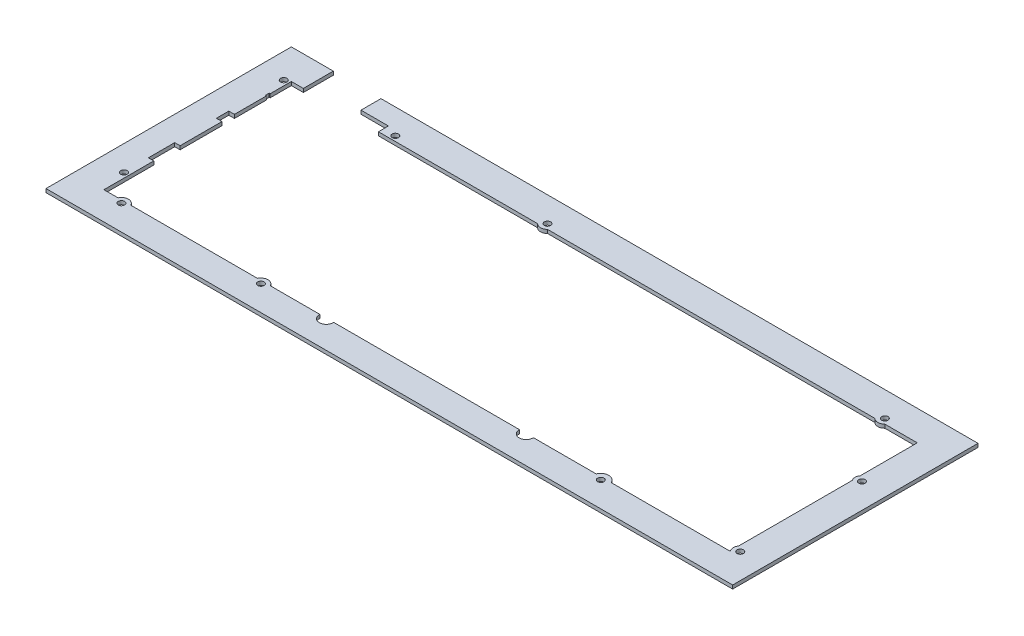
SolidWorks part; units mm, degrees
ref_plane "前视基准面" through (0, 0, 0) normal (0, 0, 1) x (1, 0, 0)
ref_plane "上视基准面" through (0, 0, 0) normal (0, 1, 0) x (1, 0, 0)
ref_plane "右视基准面" through (0, 0, 0) normal (1, 0, 0) x (0, 0, -1)
other "Configuration Table"
sketch "草图1" plane through (0, 0, 0) normal (0, 1, 0) x (1, 0, 0)
  line L0 (-34.29, 100.33) -> (-34.29, -2.54)
  line L1 (-34.29, -2.54) -> (289.56, -2.54)
  line L2 (289.56, -2.54) -> (289.56, 100.33)
  line L3 (289.56, 100.33) -> (-34.29, 100.33)
  line L4 (91.3448, 75.6639) -> (90.0599, 75.6639)
  line L5 (90.0599, 75.6639) -> (90.0599, 77.4981)
  line L6 (90.0599, 77.4981) -> (91.3448, 77.4981)
  line L7 (92.2972, 75.6639) -> (93.5821, 75.6639)
  line L8 (93.5821, 75.6639) -> (93.5821, 77.4981)
  line L9 (93.5821, 77.4981) -> (92.2972, 77.4981)
  line L10 (223.6751, 73.0568) -> (223.6751, 71.7719)
  line L11 (223.6751, 71.7719) -> (221.8409, 71.7719)
  line L12 (221.8409, 71.7719) -> (221.8409, 73.0568)
  line L13 (223.6751, 74.0092) -> (223.6751, 75.2941)
  line L14 (223.6751, 75.2941) -> (221.8409, 75.2941)
  line L15 (221.8409, 75.2941) -> (221.8409, 74.0092)
  line L16 (3.3338, 68.9329) -> (2.0489, 68.9329)
  line L17 (2.0489, 68.9329) -> (2.0489, 70.7671)
  line L18 (2.0489, 70.7671) -> (3.3338, 70.7671)
  line L19 (4.2862, 68.9329) -> (5.5711, 68.9329)
  line L20 (5.5711, 68.9329) -> (5.5711, 70.7671)
  line L21 (5.5711, 70.7671) -> (4.2862, 70.7671)
  line L22 (-12.4142, 28.9279) -> (-13.6991, 28.9279)
  line L23 (-13.6991, 28.9279) -> (-13.6991, 30.7621)
  line L24 (-13.6991, 30.7621) -> (-12.4142, 30.7621)
  line L25 (-11.4618, 28.9279) -> (-10.1769, 28.9279)
  line L26 (-10.1769, 28.9279) -> (-10.1769, 30.7621)
  line L27 (-10.1769, 30.7621) -> (-11.4618, 30.7621)
  line L28 (136.6801, 92.9958) -> (136.6801, 91.7109)
  line L29 (136.6801, 91.7109) -> (134.8459, 91.7109)
  line L30 (134.8459, 91.7109) -> (134.8459, 92.9958)
  line L31 (136.6801, 93.9482) -> (136.6801, 95.2331)
  line L32 (136.6801, 95.2331) -> (134.8459, 95.2331)
  line L33 (134.8459, 95.2331) -> (134.8459, 93.9482)
  line L34 (-6.0128, 101.14) -> (-6.0128, 100.2482)
  line L35 (-6.0128, 100.2482) -> (-6.1652, 100.0958)
  line L36 (-6.1652, 100.0958) -> (-6.6224, 100.0958)
  line L37 (-6.6224, 100.0958) -> (-6.724, 99.9942)
  line L38 (-6.724, 99.9942) -> (-6.724, 99.156)
  line L39 (-6.724, 99.156) -> (-6.6224, 99.0544)
  line L40 (-6.6224, 99.0544) -> (-6.2668, 99.0544)
  line L41 (-6.2668, 99.0544) -> (-6.0636, 98.8512)
  line L42 (-6.0636, 98.8512) -> (-6.0636, 98.775)
  line L43 (-6.0636, 98.775) -> (-6.0636, 98.0384)
  line L44 (-2.418, 98.8453) -> (-2.418, 101.14)
  line L45 (-10.2426, 101.14) -> (-2.418, 101.14)
  line L46 (-10.2038, 99.6386) -> (-7.613, 99.6386)
  line L47 (-7.613, 99.6386) -> (-7.359, 99.3846)
  line L48 (-7.359, 99.3846) -> (-7.359, 98.267)
  line L49 (-7.359, 98.267) -> (-7.1304, 98.0384)
  line L50 (-7.1304, 98.0384) -> (-5.2508, 98.0384)
  line L51 (-5.2508, 98.0384) -> (-4.8952, 98.394)
  line L52 (-4.8952, 98.394) -> (-4.8952, 99.3338)
  line L53 (-4.8952, 99.3338) -> (-4.6666, 99.5624)
  line L54 (-4.6666, 99.5624) -> (-2.418, 99.5624)
  line L55 (-9.3436, 91.6884) -> (-8.7549, 91.6884)
  line L56 (-3.9052, 91.6884) -> (-3.3564, 91.6884)
  line L57 (-10.2426, 94.1046) -> (-10.2426, 96.0288)
  line L58 (-10.2426, 98.8547) -> (-10.2426, 101.14)
  line L59 (-2.418, 94.0952) -> (-2.418, 96.0382)
  line L60 (-28.5724, 76.2138) -> (-25.5296, 76.2138)
  line L61 (-25.5296, 76.2138) -> (-25.5296, 81.2662)
  line L62 (-25.5296, 81.2662) -> (-28.5724, 81.2662)
  line L63 (-28.5724, 81.2662) -> (-28.5724, 76.2138)
  line L64 (20.2882, 93.6271) -> (21.5731, 93.6271)
  line L65 (21.5731, 93.6271) -> (21.5731, 91.7929)
  line L66 (21.5731, 91.7929) -> (20.2882, 91.7929)
  line L67 (19.3358, 93.6271) -> (18.0509, 93.6271)
  line L68 (18.0509, 93.6271) -> (18.0509, 91.7929)
  line L69 (18.0509, 91.7929) -> (19.3358, 91.7929)
  line L70 (98.5202, 77.6251) -> (99.8051, 77.6251)
  line L71 (99.8051, 77.6251) -> (99.8051, 75.7909)
  line L72 (99.8051, 75.7909) -> (98.5202, 75.7909)
  line L73 (97.5678, 77.6251) -> (96.2829, 77.6251)
  line L74 (96.2829, 77.6251) -> (96.2829, 75.7909)
  line L75 (96.2829, 75.7909) -> (97.5678, 75.7909)
  line L76 (174.0181, 91.0908) -> (174.0181, 89.8059)
  line L77 (174.0181, 89.8059) -> (172.1839, 89.8059)
  line L78 (172.1839, 89.8059) -> (172.1839, 91.0908)
  line L79 (174.0181, 92.0432) -> (174.0181, 93.3281)
  line L80 (174.0181, 93.3281) -> (172.1839, 93.3281)
  line L81 (172.1839, 93.3281) -> (172.1839, 92.0432)
  line L82 (213.6421, 91.5988) -> (213.6421, 90.3139)
  line L83 (213.6421, 90.3139) -> (211.8079, 90.3139)
  line L84 (211.8079, 90.3139) -> (211.8079, 91.5988)
  line L85 (213.6421, 92.5512) -> (213.6421, 93.8361)
  line L86 (213.6421, 93.8361) -> (211.8079, 93.8361)
  line L87 (211.8079, 93.8361) -> (211.8079, 92.5512)
  line L88 (-28.9892, 84.7236) -> (-27.5792, 84.7236)
  line L89 (-27.5792, 82.9164) -> (-28.9892, 82.9164)
  line L90 (-29.1416, 83.0688) -> (-29.1416, 84.5712)
  line L91 (-25.3668, 84.7236) -> (-26.7768, 84.7236)
  line L92 (-26.7768, 82.9164) -> (-25.3668, 82.9164)
  line L93 (-25.2144, 83.0688) -> (-25.2144, 84.5712)
  line L94 (-12.4142, 16.6089) -> (-13.6991, 16.6089)
  line L95 (-13.6991, 16.6089) -> (-13.6991, 18.4431)
  line L96 (-13.6991, 18.4431) -> (-12.4142, 18.4431)
  line L97 (-11.4618, 16.6089) -> (-10.1769, 16.6089)
  line L98 (-10.1769, 16.6089) -> (-10.1769, 18.4431)
  line L99 (-10.1769, 18.4431) -> (-11.4618, 18.4431)
  line L100 (-25.0838, 42.6707) -> (-23.5344, 42.6707)
  line L101 (-23.5344, 42.6707) -> (-23.5344, 44.7027)
  line L102 (-23.5344, 44.7027) -> (-25.0838, 44.7027)
  line L103 (-25.8712, 42.6453) -> (-27.3444, 42.6453)
  line L104 (-27.3444, 42.6453) -> (-27.7508, 43.0517)
  line L105 (-27.7508, 43.0517) -> (-27.7508, 44.3217)
  line L106 (-27.7508, 44.3217) -> (-27.3698, 44.7027)
  line L107 (-27.3698, 44.7027) -> (-25.8458, 44.7027)
  line L108 (-25.3098, 43.1863) -> (-25.3098, 44.1871)
  line L109 (-25.3098, 44.1871) -> (-25.8102, 43.6867)
  line L110 (-25.8102, 43.6867) -> (-25.3098, 43.1863)
  line L111 (-27.5095, 42.8866) -> (-27.5095, 44.4868)
  line L112 (-27.4601, 38.6398) -> (-27.4601, 37.3549)
  line L113 (-27.4601, 37.3549) -> (-25.6259, 37.3549)
  line L114 (-25.6259, 37.3549) -> (-25.6259, 38.6398)
  line L115 (-27.4601, 39.5922) -> (-27.4601, 40.8771)
  line L116 (-27.4601, 40.8771) -> (-25.6259, 40.8771)
  line L117 (-25.6259, 40.8771) -> (-25.6259, 39.5922)
  line L118 (-6.8898, 38.7069) -> (-5.6049, 38.7069)
  line L119 (-5.6049, 38.7069) -> (-5.6049, 40.5411)
  line L120 (-5.6049, 40.5411) -> (-6.8898, 40.5411)
  line L121 (-7.8422, 38.7069) -> (-9.1271, 38.7069)
  line L122 (-9.1271, 38.7069) -> (-9.1271, 40.5411)
  line L123 (-9.1271, 40.5411) -> (-7.8422, 40.5411)
  line L124 (-14.8524, 63.2422) -> (-11.3096, 63.2422)
  line L125 (-11.3096, 63.2422) -> (-11.3096, 53.0898)
  line L126 (-11.3096, 53.0898) -> (-14.8524, 53.0898)
  line L127 (-14.8524, 53.0898) -> (-14.8524, 63.2422)
  line L128 (-22.9701, 8.7965) -> (-22.9701, 15.2624)
  line L129 (-4.9701, 8.7965) -> (-4.9701, 15.2465)
  line L130 (-22.9701, 8.7965) -> (-4.9701, 8.7965)
  line L131 (-22.9701, 15.0805) -> (-4.9701, 15.0805)
  line L132 (-22.9871, 15.5894) -> (-22.9871, 15.0805)
  line L133 (-20.3662, 34.2965) -> (-22.9871, 34.2965)
  line L134 (-22.9871, 34.2965) -> (-22.9871, 33.4617)
  line L135 (-4.9701, 33.4617) -> (-4.9701, 34.2965)
  line L136 (-4.9701, 34.2965) -> (-7.5739, 34.2965)
  line L137 (-4.9701, 15.0805) -> (-4.9701, 15.5894)
  line L138 (-5.9544, 54.7038) -> (-5.9544, 56.1138)
  line L139 (-7.7616, 56.1138) -> (-7.7616, 54.7038)
  line L140 (-7.6092, 54.5514) -> (-6.1068, 54.5514)
  line L141 (-5.9544, 58.3262) -> (-5.9544, 56.9162)
  line L142 (-7.7616, 56.9162) -> (-7.7616, 58.3262)
  line L143 (-7.6092, 58.4786) -> (-6.1068, 58.4786)
  line L144 (-11.9099, 65.7542) -> (-11.9099, 67.0391)
  line L145 (-11.9099, 67.0391) -> (-13.7441, 67.0391)
  line L146 (-13.7441, 67.0391) -> (-13.7441, 65.7542)
  line L147 (-11.9099, 64.8018) -> (-11.9099, 63.5169)
  line L148 (-11.9099, 63.5169) -> (-13.7441, 63.5169)
  line L149 (-13.7441, 63.5169) -> (-13.7441, 64.8018)
  line L150 (-31.4961, 62.7179) -> (-31.4961, 62.5312)
  line L151 (-30.0991, 64.4689) -> (-30.0991, 64.7688)
  line L152 (-30.0991, 62.7688) -> (-30.0991, 62.5312)
  line L153 (-30.3646, 66.4211) -> (-29.7884, 66.4211)
  line L154 (-31.4961, 66.2821) -> (-31.4961, 66.4211)
  line L155 (-31.4961, 66.4211) -> (-31.2856, 66.4211)
  line L156 (-31.4961, 64.4689) -> (-31.4961, 64.7179)
  line L157 (-26.8258, 60.6) -> (-29.817, 60.6)
  line L158 (-29.8182, 61.722) -> (-27.3321, 61.722)
  line L159 (-30.0991, 64.2313) -> (-30.0991, 64.4689)
  line L160 (-31.4961, 64.4689) -> (-31.4961, 64.2821)
  line L161 (-27.0511, 62.7688) -> (-27.0511, 62.2313)
  line L162 (-27.0511, 64.7688) -> (-27.0511, 64.2313)
  line L163 (-29.8182, 65.278) -> (-27.3321, 65.278)
  line L164 (-25.6752, 60.6) -> (-25.8246, 60.6)
  line L165 (-30.3245, 66.4) -> (-26.8258, 66.4)
  line L166 (-25.8246, 66.4) -> (-25.6752, 66.4)
  line L167 (-25.6752, 66.4) -> (-25.6752, 66.2997)
  line L168 (-25.6752, 64.7003) -> (-25.6752, 64.2997)
  line L169 (-25.6752, 62.7003) -> (-25.6752, 62.2997)
  line L170 (-25.6752, 60.7003) -> (-25.6752, 60.6)
  line L171 (1.4, 74.4766) -> (2.3, 74.4766)
  line L172 (2.3, 74.4766) -> (2.3, 77.0768)
  line L173 (-2.3, 77.0768) -> (-2.3, 74.4766)
  line L174 (-2.3, 74.4766) -> (-1.4, 74.4766)
  line L175 (-11.0365, 71.3068) -> (-3.033, 71.3068)
  line L176 (-25.037, 73.3058) -> (-11.0365, 73.3058)
  line L177 (-11.0365, 71.3068) -> (-11.0365, 73.3068)
  line L178 (-25.0366, 71.3068) -> (-25.037, 73.3058)
  line L179 (-20.5765, 93.8544) -> (-20.5765, 100.2044)
  line L180 (-18.0365, 100.3072) -> (-18.0365, 93.8544)
  line L181 (-15.4965, 93.8544) -> (-15.4965, 100.2044)
  line L182 (-12.7866, 93.8544) -> (-12.7866, 100.3085)
  line L183 (-23.2864, 93.8074) -> (-14.9327, 93.8061)
  line L184 (-14.9327, 93.8061) -> (-12.7866, 93.8074)
  line L185 (-23.2864, 100.3072) -> (-23.2864, 93.8544)
  line L186 (-33.033, 100.307) -> (-6.0366, 100.307)
  line L187 (-30.0365, 71.3068) -> (-25.0366, 71.3068)
  line L188 (-3.033, 97.3073) -> (-3.033, 71.3068)
  line L189 (-33.033, 100.307) -> (-33.033, 74.3073)
  line L190 (16.6707, 80.128) -> (16.6707, 82.128)
  line L191 (15.0707, 80.7767) -> (16.6707, 80.7767)
  line L192 (15.0707, 80.128) -> (15.0707, 82.128)
  line L193 (15.3696, 81.5273) -> (15.3706, 81.5281)
  line L194 (15.3706, 81.5281) -> (15.8699, 80.7755)
  line L195 (15.3706, 81.5281) -> (16.2956, 81.5281)
  line L196 (16.2206, 81.5281) -> (16.2956, 81.5281)
  line L197 (16.2956, 81.5281) -> (15.864, 80.7767)
  line L198 (6.6053, 92.66) -> (15.7493, 92.66)
  line L199 (15.7493, 88.596) -> (15.7493, 92.66)
  line L200 (15.7493, 88.596) -> (10.5169, 88.596)
  line L201 (8.4341, 86.6402) -> (4.8273, 86.6402)
  line L202 (4.8273, 86.6402) -> (4.8273, 90.882)
  line L203 (7.8233, 78.802) -> (17.9233, 78.802)
  line L204 (17.9233, 78.802) -> (17.9233, 92.8025)
  line L205 (17.9233, 92.8025) -> (3.9228, 92.8025)
  line L206 (3.9228, 92.8025) -> (3.9228, 78.802)
  line L207 (3.9228, 78.802) -> (7.9233, 78.802)
  line L208 (23.7827, 41.901) -> (23.7827, 43.901)
  line L209 (22.1827, 42.5497) -> (23.7827, 42.5497)
  line L210 (22.1827, 41.901) -> (22.1827, 43.901)
  line L211 (22.4816, 43.3003) -> (22.4826, 43.3011)
  line L212 (22.4826, 43.3011) -> (22.9819, 42.5485)
  line L213 (22.4826, 43.3011) -> (23.4076, 43.3011)
  line L214 (23.3326, 43.3011) -> (23.4076, 43.3011)
  line L215 (23.4076, 43.3011) -> (22.976, 42.5497)
  line L216 (13.7173, 54.433) -> (22.8613, 54.433)
  line L217 (22.8613, 50.369) -> (22.8613, 54.433)
  line L218 (22.8613, 50.369) -> (17.6289, 50.369)
  line L219 (15.5461, 48.4132) -> (11.9393, 48.4132)
  line L220 (11.9393, 48.4132) -> (11.9393, 52.655)
  line L221 (14.9353, 40.575) -> (25.0353, 40.575)
  line L222 (25.0353, 40.575) -> (25.0353, 54.5755)
  line L223 (25.0353, 54.5755) -> (11.0348, 54.5755)
  line L224 (11.0348, 54.5755) -> (11.0348, 40.575)
  line L225 (11.0348, 40.575) -> (15.0353, 40.575)
  line L226 (28.6087, 22.851) -> (28.6087, 24.851)
  line L227 (27.0087, 23.4997) -> (28.6087, 23.4997)
  line L228 (27.0087, 22.851) -> (27.0087, 24.851)
  line L229 (27.3076, 24.2503) -> (27.3086, 24.2511)
  line L230 (27.3086, 24.2511) -> (27.8079, 23.4985)
  line L231 (27.3086, 24.2511) -> (28.2336, 24.2511)
  line L232 (28.1586, 24.2511) -> (28.2336, 24.2511)
  line L233 (28.2336, 24.2511) -> (27.802, 23.4997)
  line L234 (18.5433, 35.383) -> (27.6873, 35.383)
  line L235 (27.6873, 31.319) -> (27.6873, 35.383)
  line L236 (27.6873, 31.319) -> (22.4549, 31.319)
  line L237 (20.3721, 29.3632) -> (16.7653, 29.3632)
  line L238 (16.7653, 29.3632) -> (16.7653, 33.605)
  line L239 (19.7613, 21.525) -> (29.8613, 21.525)
  line L240 (29.8613, 21.525) -> (29.8613, 35.5255)
  line L241 (29.8613, 35.5255) -> (15.8608, 35.5255)
  line L242 (15.8608, 35.5255) -> (15.8608, 21.525)
  line L243 (15.8608, 21.525) -> (19.8613, 21.525)
  line L244 (59.4697, 22.851) -> (59.4697, 24.851)
  line L245 (57.8697, 23.4997) -> (59.4697, 23.4997)
  line L246 (57.8697, 22.851) -> (57.8697, 24.851)
  line L247 (58.1686, 24.2503) -> (58.1696, 24.2511)
  line L248 (58.1696, 24.2511) -> (58.6689, 23.4985)
  line L249 (58.1696, 24.2511) -> (59.0946, 24.2511)
  line L250 (59.0196, 24.2511) -> (59.0946, 24.2511)
  line L251 (59.0946, 24.2511) -> (58.663, 23.4997)
  line L252 (49.4043, 35.383) -> (58.5483, 35.383)
  line L253 (58.5483, 31.319) -> (58.5483, 35.383)
  line L254 (58.5483, 31.319) -> (53.3159, 31.319)
  line L255 (51.2331, 29.3632) -> (47.6263, 29.3632)
  line L256 (47.6263, 29.3632) -> (47.6263, 33.605)
  line L257 (50.6223, 21.525) -> (60.7223, 21.525)
  line L258 (60.7223, 21.525) -> (60.7223, 35.5255)
  line L259 (60.7223, 35.5255) -> (46.7218, 35.5255)
  line L260 (46.7218, 35.5255) -> (46.7218, 21.525)
  line L261 (46.7218, 21.525) -> (50.7223, 21.525)
  line L262 (50.0717, 41.901) -> (50.0717, 43.901)
  line L263 (48.4717, 42.5497) -> (50.0717, 42.5497)
  line L264 (48.4717, 41.901) -> (48.4717, 43.901)
  line L265 (48.7706, 43.3003) -> (48.7716, 43.3011)
  line L266 (48.7716, 43.3011) -> (49.2709, 42.5485)
  line L267 (48.7716, 43.3011) -> (49.6966, 43.3011)
  line L268 (49.6216, 43.3011) -> (49.6966, 43.3011)
  line L269 (49.6966, 43.3011) -> (49.265, 42.5497)
  line L270 (40.0063, 54.433) -> (49.1503, 54.433)
  line L271 (49.1503, 50.369) -> (49.1503, 54.433)
  line L272 (49.1503, 50.369) -> (43.9179, 50.369)
  line L273 (41.8351, 48.4132) -> (38.2283, 48.4132)
  line L274 (38.2283, 48.4132) -> (38.2283, 52.655)
  line L275 (41.2243, 40.575) -> (51.3243, 40.575)
  line L276 (51.3243, 40.575) -> (51.3243, 54.5755)
  line L277 (51.3243, 54.5755) -> (37.3238, 54.5755)
  line L278 (37.3238, 54.5755) -> (37.3238, 40.575)
  line L279 (37.3238, 40.575) -> (41.3243, 40.575)
  line L280 (19.0837, 3.801) -> (19.0837, 5.801)
  line L281 (17.4837, 4.4497) -> (19.0837, 4.4497)
  line L282 (17.4837, 3.801) -> (17.4837, 5.801)
  line L283 (17.7826, 5.2003) -> (17.7836, 5.2011)
  line L284 (17.7836, 5.2011) -> (18.2829, 4.4485)
  line L285 (17.7836, 5.2011) -> (18.7086, 5.2011)
  line L286 (18.6336, 5.2011) -> (18.7086, 5.2011)
  line L287 (18.7086, 5.2011) -> (18.277, 4.4497)
  line L288 (9.0183, 16.333) -> (18.1623, 16.333)
  line L289 (18.1623, 12.269) -> (18.1623, 16.333)
  line L290 (18.1623, 12.269) -> (12.9299, 12.269)
  line L291 (10.8471, 10.3132) -> (7.2403, 10.3132)
  line L292 (7.2403, 10.3132) -> (7.2403, 14.555)
  line L293 (10.2363, 2.475) -> (20.3363, 2.475)
  line L294 (20.3363, 2.475) -> (20.3363, 16.4755)
  line L295 (20.3363, 16.4755) -> (6.3358, 16.4755)
  line L296 (6.3358, 16.4755) -> (6.3358, 2.475)
  line L297 (6.3358, 2.475) -> (10.3363, 2.475)
  line L298 (42.8327, 3.801) -> (42.8327, 5.801)
  line L299 (41.2327, 4.4497) -> (42.8327, 4.4497)
  line L300 (41.2327, 3.801) -> (41.2327, 5.801)
  line L301 (41.5316, 5.2003) -> (41.5326, 5.2011)
  line L302 (41.5326, 5.2011) -> (42.0319, 4.4485)
  line L303 (41.5326, 5.2011) -> (42.4576, 5.2011)
  line L304 (42.3826, 5.2011) -> (42.4576, 5.2011)
  line L305 (42.4576, 5.2011) -> (42.026, 4.4497)
  line L306 (32.7673, 16.333) -> (41.9113, 16.333)
  line L307 (41.9113, 12.269) -> (41.9113, 16.333)
  line L308 (41.9113, 12.269) -> (36.6789, 12.269)
  line L309 (34.5961, 10.3132) -> (30.9893, 10.3132)
  line L310 (30.9893, 10.3132) -> (30.9893, 14.555)
  line L311 (33.9853, 2.475) -> (44.0853, 2.475)
  line L312 (44.0853, 2.475) -> (44.0853, 16.4755)
  line L313 (44.0853, 16.4755) -> (30.0848, 16.4755)
  line L314 (30.0848, 16.4755) -> (30.0848, 2.475)
  line L315 (30.0848, 2.475) -> (34.0853, 2.475)
  line L316 (45.2457, 61.078) -> (45.2457, 63.078)
  line L317 (43.6457, 61.7267) -> (45.2457, 61.7267)
  line L318 (43.6457, 61.078) -> (43.6457, 63.078)
  line L319 (43.9446, 62.4773) -> (43.9456, 62.4781)
  line L320 (43.9456, 62.4781) -> (44.4449, 61.7255)
  line L321 (43.9456, 62.4781) -> (44.8706, 62.4781)
  line L322 (44.7956, 62.4781) -> (44.8706, 62.4781)
  line L323 (44.8706, 62.4781) -> (44.439, 61.7267)
  line L324 (35.1803, 73.61) -> (44.3243, 73.61)
  line L325 (44.3243, 69.546) -> (44.3243, 73.61)
  line L326 (44.3243, 69.546) -> (39.0919, 69.546)
  line L327 (37.0091, 67.5902) -> (33.4023, 67.5902)
  line L328 (33.4023, 67.5902) -> (33.4023, 71.832)
  line L329 (36.3983, 59.752) -> (46.4983, 59.752)
  line L330 (46.4983, 59.752) -> (46.4983, 73.7525)
  line L331 (46.4983, 73.7525) -> (32.4978, 73.7525)
  line L332 (32.4978, 73.7525) -> (32.4978, 59.752)
  line L333 (32.4978, 59.752) -> (36.4983, 59.752)
  line L334 (35.7207, 80.128) -> (35.7207, 82.128)
  line L335 (34.1207, 80.7767) -> (35.7207, 80.7767)
  line L336 (34.1207, 80.128) -> (34.1207, 82.128)
  line L337 (34.4196, 81.5273) -> (34.4206, 81.5281)
  line L338 (34.4206, 81.5281) -> (34.9199, 80.7755)
  line L339 (34.4206, 81.5281) -> (35.3456, 81.5281)
  line L340 (35.2706, 81.5281) -> (35.3456, 81.5281)
  line L341 (35.3456, 81.5281) -> (34.914, 80.7767)
  line L342 (25.6553, 92.66) -> (34.7993, 92.66)
  line L343 (34.7993, 88.596) -> (34.7993, 92.66)
  line L344 (34.7993, 88.596) -> (29.5669, 88.596)
  line L345 (27.4841, 86.6402) -> (23.8773, 86.6402)
  line L346 (23.8773, 86.6402) -> (23.8773, 90.882)
  line L347 (26.8733, 78.802) -> (36.9733, 78.802)
  line L348 (36.9733, 78.802) -> (36.9733, 92.8025)
  line L349 (36.9733, 92.8025) -> (22.9728, 92.8025)
  line L350 (22.9728, 92.8025) -> (22.9728, 78.802)
  line L351 (22.9728, 78.802) -> (26.9733, 78.802)
  line L352 (54.7707, 80.128) -> (54.7707, 82.128)
  line L353 (53.1707, 80.7767) -> (54.7707, 80.7767)
  line L354 (53.1707, 80.128) -> (53.1707, 82.128)
  line L355 (53.4696, 81.5273) -> (53.4706, 81.5281)
  line L356 (53.4706, 81.5281) -> (53.9699, 80.7755)
  line L357 (53.4706, 81.5281) -> (54.3956, 81.5281)
  line L358 (54.3206, 81.5281) -> (54.3956, 81.5281)
  line L359 (54.3956, 81.5281) -> (53.964, 80.7767)
  line L360 (44.7053, 92.66) -> (53.8493, 92.66)
  line L361 (53.8493, 88.596) -> (53.8493, 92.66)
  line L362 (53.8493, 88.596) -> (48.6169, 88.596)
  line L363 (46.5341, 86.6402) -> (42.9273, 86.6402)
  line L364 (42.9273, 86.6402) -> (42.9273, 90.882)
  line L365 (45.9233, 78.802) -> (56.0233, 78.802)
  line L366 (56.0233, 78.802) -> (56.0233, 92.8025)
  line L367 (56.0233, 92.8025) -> (42.0228, 92.8025)
  line L368 (42.0228, 92.8025) -> (42.0228, 78.802)
  line L369 (42.0228, 78.802) -> (46.0233, 78.802)
  line L370 (64.2957, 61.078) -> (64.2957, 63.078)
  line L371 (62.6957, 61.7267) -> (64.2957, 61.7267)
  line L372 (62.6957, 61.078) -> (62.6957, 63.078)
  line L373 (62.9946, 62.4773) -> (62.9956, 62.4781)
  line L374 (62.9956, 62.4781) -> (63.4949, 61.7255)
  line L375 (62.9956, 62.4781) -> (63.9206, 62.4781)
  line L376 (63.8456, 62.4781) -> (63.9206, 62.4781)
  line L377 (63.9206, 62.4781) -> (63.489, 61.7267)
  line L378 (54.2303, 73.61) -> (63.3743, 73.61)
  line L379 (63.3743, 69.546) -> (63.3743, 73.61)
  line L380 (63.3743, 69.546) -> (58.1419, 69.546)
  line L381 (56.0591, 67.5902) -> (52.4523, 67.5902)
  line L382 (52.4523, 67.5902) -> (52.4523, 71.832)
  line L383 (55.4483, 59.752) -> (65.5483, 59.752)
  line L384 (65.5483, 59.752) -> (65.5483, 73.7525)
  line L385 (65.5483, 73.7525) -> (51.5478, 73.7525)
  line L386 (51.5478, 73.7525) -> (51.5478, 59.752)
  line L387 (51.5478, 59.752) -> (55.5483, 59.752)
  line L388 (68.9947, 41.901) -> (68.9947, 43.901)
  line L389 (67.3947, 42.5497) -> (68.9947, 42.5497)
  line L390 (67.3947, 41.901) -> (67.3947, 43.901)
  line L391 (67.6936, 43.3003) -> (67.6946, 43.3011)
  line L392 (67.6946, 43.3011) -> (68.1939, 42.5485)
  line L393 (67.6946, 43.3011) -> (68.6196, 43.3011)
  line L394 (68.5446, 43.3011) -> (68.6196, 43.3011)
  line L395 (68.6196, 43.3011) -> (68.188, 42.5497)
  line L396 (58.9293, 54.433) -> (68.0733, 54.433)
  line L397 (68.0733, 50.369) -> (68.0733, 54.433)
  line L398 (68.0733, 50.369) -> (62.8409, 50.369)
  line L399 (60.7581, 48.4132) -> (57.1513, 48.4132)
  line L400 (57.1513, 48.4132) -> (57.1513, 52.655)
  line L401 (60.1473, 40.575) -> (70.2473, 40.575)
  line L402 (70.2473, 40.575) -> (70.2473, 54.5755)
  line L403 (70.2473, 54.5755) -> (56.2468, 54.5755)
  line L404 (56.2468, 54.5755) -> (56.2468, 40.575)
  line L405 (56.2468, 40.575) -> (60.2473, 40.575)
  line L406 (78.6467, 22.978) -> (78.6467, 24.978)
  line L407 (77.0467, 23.6267) -> (78.6467, 23.6267)
  line L408 (77.0467, 22.978) -> (77.0467, 24.978)
  line L409 (77.3456, 24.3773) -> (77.3466, 24.3781)
  line L410 (77.3466, 24.3781) -> (77.8459, 23.6255)
  line L411 (77.3466, 24.3781) -> (78.2716, 24.3781)
  line L412 (78.1966, 24.3781) -> (78.2716, 24.3781)
  line L413 (78.2716, 24.3781) -> (77.84, 23.6267)
  line L414 (68.5813, 35.51) -> (77.7253, 35.51)
  line L415 (77.7253, 31.446) -> (77.7253, 35.51)
  line L416 (77.7253, 31.446) -> (72.4929, 31.446)
  line L417 (70.4101, 29.4902) -> (66.8033, 29.4902)
  line L418 (66.8033, 29.4902) -> (66.8033, 33.732)
  line L419 (69.7993, 21.652) -> (79.8993, 21.652)
  line L420 (79.8993, 21.652) -> (79.8993, 35.6525)
  line L421 (79.8993, 35.6525) -> (65.8988, 35.6525)
  line L422 (65.8988, 35.6525) -> (65.8988, 21.652)
  line L423 (65.8988, 21.652) -> (69.8993, 21.652)
  line L424 (66.7087, 3.928) -> (66.7087, 5.928)
  line L425 (65.1087, 4.5767) -> (66.7087, 4.5767)
  line L426 (65.1087, 3.928) -> (65.1087, 5.928)
  line L427 (65.4076, 5.3273) -> (65.4086, 5.3281)
  line L428 (65.4086, 5.3281) -> (65.9079, 4.5755)
  line L429 (65.4086, 5.3281) -> (66.3336, 5.3281)
  line L430 (66.2586, 5.3281) -> (66.3336, 5.3281)
  line L431 (66.3336, 5.3281) -> (65.902, 4.5767)
  line L432 (56.6433, 16.46) -> (65.7873, 16.46)
  line L433 (65.7873, 12.396) -> (65.7873, 16.46)
  line L434 (65.7873, 12.396) -> (60.5549, 12.396)
  line L435 (58.4721, 10.4402) -> (54.8653, 10.4402)
  line L436 (54.8653, 10.4402) -> (54.8653, 14.682)
  line L437 (57.8613, 2.602) -> (67.9613, 2.602)
  line L438 (67.9613, 2.602) -> (67.9613, 16.6025)
  line L439 (67.9613, 16.6025) -> (53.9608, 16.6025)
  line L440 (53.9608, 16.6025) -> (53.9608, 2.602)
  line L441 (53.9608, 2.602) -> (57.9613, 2.602)
  line L442 (97.5697, 22.978) -> (97.5697, 24.978)
  line L443 (95.9697, 23.6267) -> (97.5697, 23.6267)
  line L444 (95.9697, 22.978) -> (95.9697, 24.978)
  line L445 (96.2686, 24.3773) -> (96.2696, 24.3781)
  line L446 (96.2696, 24.3781) -> (96.7689, 23.6255)
  line L447 (96.2696, 24.3781) -> (97.1946, 24.3781)
  line L448 (97.1196, 24.3781) -> (97.1946, 24.3781)
  line L449 (97.1946, 24.3781) -> (96.763, 23.6267)
  line L450 (87.5043, 35.51) -> (96.6483, 35.51)
  line L451 (96.6483, 31.446) -> (96.6483, 35.51)
  line L452 (96.6483, 31.446) -> (91.4159, 31.446)
  line L453 (89.3331, 29.4902) -> (85.7263, 29.4902)
  line L454 (85.7263, 29.4902) -> (85.7263, 33.732)
  line L455 (88.7223, 21.652) -> (98.8223, 21.652)
  line L456 (98.8223, 21.652) -> (98.8223, 35.6525)
  line L457 (98.8223, 35.6525) -> (84.8218, 35.6525)
  line L458 (84.8218, 35.6525) -> (84.8218, 21.652)
  line L459 (84.8218, 21.652) -> (88.8223, 21.652)
  line L460 (135.7967, 22.978) -> (135.7967, 24.978)
  line L461 (134.1967, 23.6267) -> (135.7967, 23.6267)
  line L462 (134.1967, 22.978) -> (134.1967, 24.978)
  line L463 (134.4956, 24.3773) -> (134.4966, 24.3781)
  line L464 (134.4966, 24.3781) -> (134.9959, 23.6255)
  line L465 (134.4966, 24.3781) -> (135.4216, 24.3781)
  line L466 (135.3466, 24.3781) -> (135.4216, 24.3781)
  line L467 (135.4216, 24.3781) -> (134.99, 23.6267)
  line L468 (125.7313, 35.51) -> (134.8753, 35.51)
  line L469 (134.8753, 31.446) -> (134.8753, 35.51)
  line L470 (134.8753, 31.446) -> (129.6429, 31.446)
  line L471 (127.5601, 29.4902) -> (123.9533, 29.4902)
  line L472 (123.9533, 29.4902) -> (123.9533, 33.732)
  line L473 (126.9493, 21.652) -> (137.0493, 21.652)
  line L474 (137.0493, 21.652) -> (137.0493, 35.6525)
  line L475 (137.0493, 35.6525) -> (123.0488, 35.6525)
  line L476 (123.0488, 35.6525) -> (123.0488, 21.652)
  line L477 (123.0488, 21.652) -> (127.0493, 21.652)
  line L478 (126.2717, 42.028) -> (126.2717, 44.028)
  line L479 (124.6717, 42.6767) -> (126.2717, 42.6767)
  line L480 (124.6717, 42.028) -> (124.6717, 44.028)
  line L481 (124.9706, 43.4273) -> (124.9716, 43.4281)
  line L482 (124.9716, 43.4281) -> (125.4709, 42.6755)
  line L483 (124.9716, 43.4281) -> (125.8966, 43.4281)
  line L484 (125.8216, 43.4281) -> (125.8966, 43.4281)
  line L485 (125.8966, 43.4281) -> (125.465, 42.6767)
  line L486 (116.2063, 54.56) -> (125.3503, 54.56)
  line L487 (125.3503, 50.496) -> (125.3503, 54.56)
  line L488 (125.3503, 50.496) -> (120.1179, 50.496)
  line L489 (118.0351, 48.5402) -> (114.4283, 48.5402)
  line L490 (114.4283, 48.5402) -> (114.4283, 52.782)
  line L491 (117.4243, 40.702) -> (127.5243, 40.702)
  line L492 (127.5243, 40.702) -> (127.5243, 54.7025)
  line L493 (127.5243, 54.7025) -> (113.5238, 54.7025)
  line L494 (113.5238, 54.7025) -> (113.5238, 40.702)
  line L495 (113.5238, 40.702) -> (117.5243, 40.702)
  line L496 (121.4457, 61.078) -> (121.4457, 63.078)
  line L497 (119.8457, 61.7267) -> (121.4457, 61.7267)
  line L498 (119.8457, 61.078) -> (119.8457, 63.078)
  line L499 (120.1446, 62.4773) -> (120.1456, 62.4781)
  line L500 (120.1456, 62.4781) -> (120.6449, 61.7255)
  line L501 (120.1456, 62.4781) -> (121.0706, 62.4781)
  line L502 (120.9956, 62.4781) -> (121.0706, 62.4781)
  line L503 (121.0706, 62.4781) -> (120.639, 61.7267)
  line L504 (111.3803, 73.61) -> (120.5243, 73.61)
  line L505 (120.5243, 69.546) -> (120.5243, 73.61)
  line L506 (120.5243, 69.546) -> (115.2919, 69.546)
  line L507 (113.2091, 67.5902) -> (109.6023, 67.5902)
  line L508 (109.6023, 67.5902) -> (109.6023, 71.832)
  line L509 (112.5983, 59.752) -> (122.6983, 59.752)
  line L510 (122.6983, 59.752) -> (122.6983, 73.7525)
  line L511 (122.6983, 73.7525) -> (108.6978, 73.7525)
  line L512 (108.6978, 73.7525) -> (108.6978, 59.752)
  line L513 (108.6978, 59.752) -> (112.6983, 59.752)
  line L514 (111.9207, 80.128) -> (111.9207, 82.128)
  line L515 (110.3207, 80.7767) -> (111.9207, 80.7767)
  line L516 (110.3207, 80.128) -> (110.3207, 82.128)
  line L517 (110.6196, 81.5273) -> (110.6206, 81.5281)
  line L518 (110.6206, 81.5281) -> (111.1199, 80.7755)
  line L519 (110.6206, 81.5281) -> (111.5456, 81.5281)
  line L520 (111.4706, 81.5281) -> (111.5456, 81.5281)
  line L521 (111.5456, 81.5281) -> (111.114, 80.7767)
  line L522 (101.8553, 92.66) -> (110.9993, 92.66)
  line L523 (110.9993, 88.596) -> (110.9993, 92.66)
  line L524 (110.9993, 88.596) -> (105.7669, 88.596)
  line L525 (103.6841, 86.6402) -> (100.0773, 86.6402)
  line L526 (100.0773, 86.6402) -> (100.0773, 90.882)
  line L527 (103.0733, 78.802) -> (113.1733, 78.802)
  line L528 (113.1733, 78.802) -> (113.1733, 92.8025)
  line L529 (113.1733, 92.8025) -> (99.1728, 92.8025)
  line L530 (99.1728, 92.8025) -> (99.1728, 78.802)
  line L531 (99.1728, 78.802) -> (103.1733, 78.802)
  line L532 (130.9707, 80.128) -> (130.9707, 82.128)
  line L533 (129.3707, 80.7767) -> (130.9707, 80.7767)
  line L534 (129.3707, 80.128) -> (129.3707, 82.128)
  line L535 (129.6696, 81.5273) -> (129.6706, 81.5281)
  line L536 (129.6706, 81.5281) -> (130.1699, 80.7755)
  line L537 (129.6706, 81.5281) -> (130.5956, 81.5281)
  line L538 (130.5206, 81.5281) -> (130.5956, 81.5281)
  line L539 (130.5956, 81.5281) -> (130.164, 80.7767)
  line L540 (120.9053, 92.66) -> (130.0493, 92.66)
  line L541 (130.0493, 88.596) -> (130.0493, 92.66)
  line L542 (130.0493, 88.596) -> (124.8169, 88.596)
  line L543 (122.7341, 86.6402) -> (119.1273, 86.6402)
  line L544 (119.1273, 86.6402) -> (119.1273, 90.882)
  line L545 (122.1233, 78.802) -> (132.2233, 78.802)
  line L546 (132.2233, 78.802) -> (132.2233, 92.8025)
  line L547 (132.2233, 92.8025) -> (118.2228, 92.8025)
  line L548 (118.2228, 92.8025) -> (118.2228, 78.802)
  line L549 (118.2228, 78.802) -> (122.2233, 78.802)
  line L550 (140.4957, 61.078) -> (140.4957, 63.078)
  line L551 (138.8957, 61.7267) -> (140.4957, 61.7267)
  line L552 (138.8957, 61.078) -> (138.8957, 63.078)
  line L553 (139.1946, 62.4773) -> (139.1956, 62.4781)
  line L554 (139.1956, 62.4781) -> (139.6949, 61.7255)
  line L555 (139.1956, 62.4781) -> (140.1206, 62.4781)
  line L556 (140.0456, 62.4781) -> (140.1206, 62.4781)
  line L557 (140.1206, 62.4781) -> (139.689, 61.7267)
  line L558 (130.4303, 73.61) -> (139.5743, 73.61)
  line L559 (139.5743, 69.546) -> (139.5743, 73.61)
  line L560 (139.5743, 69.546) -> (134.3419, 69.546)
  line L561 (132.2591, 67.5902) -> (128.6523, 67.5902)
  line L562 (128.6523, 67.5902) -> (128.6523, 71.832)
  line L563 (131.6483, 59.752) -> (141.7483, 59.752)
  line L564 (141.7483, 59.752) -> (141.7483, 73.7525)
  line L565 (141.7483, 73.7525) -> (127.7478, 73.7525)
  line L566 (127.7478, 73.7525) -> (127.7478, 59.752)
  line L567 (127.7478, 59.752) -> (131.7483, 59.752)
  line L568 (145.1947, 42.028) -> (145.1947, 44.028)
  line L569 (143.5947, 42.6767) -> (145.1947, 42.6767)
  line L570 (143.5947, 42.028) -> (143.5947, 44.028)
  line L571 (143.8936, 43.4273) -> (143.8946, 43.4281)
  line L572 (143.8946, 43.4281) -> (144.3939, 42.6755)
  line L573 (143.8946, 43.4281) -> (144.8196, 43.4281)
  line L574 (144.7446, 43.4281) -> (144.8196, 43.4281)
  line L575 (144.8196, 43.4281) -> (144.388, 42.6767)
  line L576 (135.1293, 54.56) -> (144.2733, 54.56)
  line L577 (144.2733, 50.496) -> (144.2733, 54.56)
  line L578 (144.2733, 50.496) -> (139.0409, 50.496)
  line L579 (136.9581, 48.5402) -> (133.3513, 48.5402)
  line L580 (133.3513, 48.5402) -> (133.3513, 52.782)
  line L581 (136.3473, 40.702) -> (146.4473, 40.702)
  line L582 (146.4473, 40.702) -> (146.4473, 54.7025)
  line L583 (146.4473, 54.7025) -> (132.4468, 54.7025)
  line L584 (132.4468, 54.7025) -> (132.4468, 40.702)
  line L585 (132.4468, 40.702) -> (136.4473, 40.702)
  line L586 (154.8467, 22.978) -> (154.8467, 24.978)
  line L587 (153.2467, 23.6267) -> (154.8467, 23.6267)
  line L588 (153.2467, 22.978) -> (153.2467, 24.978)
  line L589 (153.5456, 24.3773) -> (153.5466, 24.3781)
  line L590 (153.5466, 24.3781) -> (154.0459, 23.6255)
  line L591 (153.5466, 24.3781) -> (154.4716, 24.3781)
  line L592 (154.3966, 24.3781) -> (154.4716, 24.3781)
  line L593 (154.4716, 24.3781) -> (154.04, 23.6267)
  line L594 (144.7813, 35.51) -> (153.9253, 35.51)
  line L595 (153.9253, 31.446) -> (153.9253, 35.51)
  line L596 (153.9253, 31.446) -> (148.6929, 31.446)
  line L597 (146.6101, 29.4902) -> (143.0033, 29.4902)
  line L598 (143.0033, 29.4902) -> (143.0033, 33.732)
  line L599 (145.9993, 21.652) -> (156.0993, 21.652)
  line L600 (156.0993, 21.652) -> (156.0993, 35.6525)
  line L601 (156.0993, 35.6525) -> (142.0988, 35.6525)
  line L602 (142.0988, 35.6525) -> (142.0988, 21.652)
  line L603 (142.0988, 21.652) -> (146.0993, 21.652)
  line L604 (88.1717, 41.901) -> (88.1717, 43.901)
  line L605 (86.5717, 42.5497) -> (88.1717, 42.5497)
  line L606 (86.5717, 41.901) -> (86.5717, 43.901)
  line L607 (86.8706, 43.3003) -> (86.8716, 43.3011)
  line L608 (86.8716, 43.3011) -> (87.3709, 42.5485)
  line L609 (86.8716, 43.3011) -> (87.7966, 43.3011)
  line L610 (87.7216, 43.3011) -> (87.7966, 43.3011)
  line L611 (87.7966, 43.3011) -> (87.365, 42.5497)
  line L612 (78.1063, 54.433) -> (87.2503, 54.433)
  line L613 (87.2503, 50.369) -> (87.2503, 54.433)
  line L614 (87.2503, 50.369) -> (82.0179, 50.369)
  line L615 (79.9351, 48.4132) -> (76.3283, 48.4132)
  line L616 (76.3283, 48.4132) -> (76.3283, 52.655)
  line L617 (79.3243, 40.575) -> (89.4243, 40.575)
  line L618 (89.4243, 40.575) -> (89.4243, 54.5755)
  line L619 (89.4243, 54.5755) -> (75.4238, 54.5755)
  line L620 (75.4238, 54.5755) -> (75.4238, 40.575)
  line L621 (75.4238, 40.575) -> (79.4243, 40.575)
  line L622 (83.3457, 60.951) -> (83.3457, 62.951)
  line L623 (81.7457, 61.5997) -> (83.3457, 61.5997)
  line L624 (81.7457, 60.951) -> (81.7457, 62.951)
  line L625 (82.0446, 62.3503) -> (82.0456, 62.3511)
  line L626 (82.0456, 62.3511) -> (82.5449, 61.5985)
  line L627 (82.0456, 62.3511) -> (82.9706, 62.3511)
  line L628 (82.8956, 62.3511) -> (82.9706, 62.3511)
  line L629 (82.9706, 62.3511) -> (82.539, 61.5997)
  line L630 (73.2803, 73.483) -> (82.4243, 73.483)
  line L631 (82.4243, 69.419) -> (82.4243, 73.483)
  line L632 (82.4243, 69.419) -> (77.1919, 69.419)
  line L633 (75.1091, 67.4632) -> (71.5023, 67.4632)
  line L634 (71.5023, 67.4632) -> (71.5023, 71.705)
  line L635 (74.4983, 59.625) -> (84.5983, 59.625)
  line L636 (84.5983, 59.625) -> (84.5983, 73.6255)
  line L637 (84.5983, 73.6255) -> (70.5978, 73.6255)
  line L638 (70.5978, 73.6255) -> (70.5978, 59.625)
  line L639 (70.5978, 59.625) -> (74.5983, 59.625)
  line L640 (73.8207, 80.128) -> (73.8207, 82.128)
  line L641 (72.2207, 80.7767) -> (73.8207, 80.7767)
  line L642 (72.2207, 80.128) -> (72.2207, 82.128)
  line L643 (72.5196, 81.5273) -> (72.5206, 81.5281)
  line L644 (72.5206, 81.5281) -> (73.0199, 80.7755)
  line L645 (72.5206, 81.5281) -> (73.4456, 81.5281)
  line L646 (73.3706, 81.5281) -> (73.4456, 81.5281)
  line L647 (73.4456, 81.5281) -> (73.014, 80.7767)
  line L648 (63.7553, 92.66) -> (72.8993, 92.66)
  line L649 (72.8993, 88.596) -> (72.8993, 92.66)
  line L650 (72.8993, 88.596) -> (67.6669, 88.596)
  line L651 (65.5841, 86.6402) -> (61.9773, 86.6402)
  line L652 (61.9773, 86.6402) -> (61.9773, 90.882)
  line L653 (64.9733, 78.802) -> (75.0733, 78.802)
  line L654 (75.0733, 78.802) -> (75.0733, 92.8025)
  line L655 (75.0733, 92.8025) -> (61.0728, 92.8025)
  line L656 (61.0728, 92.8025) -> (61.0728, 78.802)
  line L657 (61.0728, 78.802) -> (65.0733, 78.802)
  line L658 (92.8707, 80.128) -> (92.8707, 82.128)
  line L659 (91.2707, 80.7767) -> (92.8707, 80.7767)
  line L660 (91.2707, 80.128) -> (91.2707, 82.128)
  line L661 (91.5696, 81.5273) -> (91.5706, 81.5281)
  line L662 (91.5706, 81.5281) -> (92.0699, 80.7755)
  line L663 (91.5706, 81.5281) -> (92.4956, 81.5281)
  line L664 (92.4206, 81.5281) -> (92.4956, 81.5281)
  line L665 (92.4956, 81.5281) -> (92.064, 80.7767)
  line L666 (82.8053, 92.66) -> (91.9493, 92.66)
  line L667 (91.9493, 88.596) -> (91.9493, 92.66)
  line L668 (91.9493, 88.596) -> (86.7169, 88.596)
  line L669 (84.6341, 86.6402) -> (81.0273, 86.6402)
  line L670 (81.0273, 86.6402) -> (81.0273, 90.882)
  line L671 (84.0233, 78.802) -> (94.1233, 78.802)
  line L672 (94.1233, 78.802) -> (94.1233, 92.8025)
  line L673 (94.1233, 92.8025) -> (80.1228, 92.8025)
  line L674 (80.1228, 92.8025) -> (80.1228, 78.802)
  line L675 (80.1228, 78.802) -> (84.1233, 78.802)
  line L676 (102.3957, 60.951) -> (102.3957, 62.951)
  line L677 (100.7957, 61.5997) -> (102.3957, 61.5997)
  line L678 (100.7957, 60.951) -> (100.7957, 62.951)
  line L679 (101.0946, 62.3503) -> (101.0956, 62.3511)
  line L680 (101.0956, 62.3511) -> (101.5949, 61.5985)
  line L681 (101.0956, 62.3511) -> (102.0206, 62.3511)
  line L682 (101.9456, 62.3511) -> (102.0206, 62.3511)
  line L683 (102.0206, 62.3511) -> (101.589, 61.5997)
  line L684 (92.3303, 73.483) -> (101.4743, 73.483)
  line L685 (101.4743, 69.419) -> (101.4743, 73.483)
  line L686 (101.4743, 69.419) -> (96.2419, 69.419)
  line L687 (94.1591, 67.4632) -> (90.5523, 67.4632)
  line L688 (90.5523, 67.4632) -> (90.5523, 71.705)
  line L689 (93.5483, 59.625) -> (103.6483, 59.625)
  line L690 (103.6483, 59.625) -> (103.6483, 73.6255)
  line L691 (103.6483, 73.6255) -> (89.6478, 73.6255)
  line L692 (89.6478, 73.6255) -> (89.6478, 59.625)
  line L693 (89.6478, 59.625) -> (93.6483, 59.625)
  line L694 (107.2217, 42.028) -> (107.2217, 44.028)
  line L695 (105.6217, 42.6767) -> (107.2217, 42.6767)
  line L696 (105.6217, 42.028) -> (105.6217, 44.028)
  line L697 (105.9206, 43.4273) -> (105.9216, 43.4281)
  line L698 (105.9216, 43.4281) -> (106.4209, 42.6755)
  line L699 (105.9216, 43.4281) -> (106.8466, 43.4281)
  line L700 (106.7716, 43.4281) -> (106.8466, 43.4281)
  line L701 (106.8466, 43.4281) -> (106.415, 42.6767)
  line L702 (97.1563, 54.56) -> (106.3003, 54.56)
  line L703 (106.3003, 50.496) -> (106.3003, 54.56)
  line L704 (106.3003, 50.496) -> (101.0679, 50.496)
  line L705 (98.9851, 48.5402) -> (95.3783, 48.5402)
  line L706 (95.3783, 48.5402) -> (95.3783, 52.782)
  line L707 (98.3743, 40.702) -> (108.4743, 40.702)
  line L708 (108.4743, 40.702) -> (108.4743, 54.7025)
  line L709 (108.4743, 54.7025) -> (94.4738, 54.7025)
  line L710 (94.4738, 54.7025) -> (94.4738, 40.702)
  line L711 (94.4738, 40.702) -> (98.4743, 40.702)
  line L712 (116.7467, 22.978) -> (116.7467, 24.978)
  line L713 (115.1467, 23.6267) -> (116.7467, 23.6267)
  line L714 (115.1467, 22.978) -> (115.1467, 24.978)
  line L715 (115.4456, 24.3773) -> (115.4466, 24.3781)
  line L716 (115.4466, 24.3781) -> (115.9459, 23.6255)
  line L717 (115.4466, 24.3781) -> (116.3716, 24.3781)
  line L718 (116.2966, 24.3781) -> (116.3716, 24.3781)
  line L719 (116.3716, 24.3781) -> (115.94, 23.6267)
  line L720 (106.6813, 35.51) -> (115.8253, 35.51)
  line L721 (115.8253, 31.446) -> (115.8253, 35.51)
  line L722 (115.8253, 31.446) -> (110.5929, 31.446)
  line L723 (108.5101, 29.4902) -> (104.9033, 29.4902)
  line L724 (104.9033, 29.4902) -> (104.9033, 33.732)
  line L725 (107.8993, 21.652) -> (117.9993, 21.652)
  line L726 (117.9993, 21.652) -> (117.9993, 35.6525)
  line L727 (117.9993, 35.6525) -> (103.9988, 35.6525)
  line L728 (103.9988, 35.6525) -> (103.9988, 21.652)
  line L729 (103.9988, 21.652) -> (107.9993, 21.652)
  line L730 (138.0827, 3.801) -> (138.0827, 5.801)
  line L731 (136.4827, 4.4497) -> (138.0827, 4.4497)
  line L732 (136.4827, 3.801) -> (136.4827, 5.801)
  line L733 (136.7816, 5.2003) -> (136.7826, 5.2011)
  line L734 (136.7826, 5.2011) -> (137.2819, 4.4485)
  line L735 (136.7826, 5.2011) -> (137.7076, 5.2011)
  line L736 (137.6326, 5.2011) -> (137.7076, 5.2011)
  line L737 (137.7076, 5.2011) -> (137.276, 4.4497)
  line L738 (128.0173, 16.333) -> (137.1613, 16.333)
  line L739 (137.1613, 12.269) -> (137.1613, 16.333)
  line L740 (137.1613, 12.269) -> (131.9289, 12.269)
  line L741 (129.8461, 10.3132) -> (126.2393, 10.3132)
  line L742 (126.2393, 10.3132) -> (126.2393, 14.555)
  line L743 (129.2353, 2.475) -> (139.3353, 2.475)
  line L744 (139.3353, 2.475) -> (139.3353, 16.4755)
  line L745 (139.3353, 16.4755) -> (125.3348, 16.4755)
  line L746 (125.3348, 16.4755) -> (125.3348, 2.475)
  line L747 (125.3348, 2.475) -> (129.3353, 2.475)
  line L748 (233.3327, 3.928) -> (233.3327, 5.928)
  line L749 (231.7327, 4.5767) -> (233.3327, 4.5767)
  line L750 (231.7327, 3.928) -> (231.7327, 5.928)
  line L751 (232.0316, 5.3273) -> (232.0326, 5.3281)
  line L752 (232.0326, 5.3281) -> (232.5319, 4.5755)
  line L753 (232.0326, 5.3281) -> (232.9576, 5.3281)
  line L754 (232.8826, 5.3281) -> (232.9576, 5.3281)
  line L755 (232.9576, 5.3281) -> (232.526, 4.5767)
  line L756 (223.2673, 16.46) -> (232.4113, 16.46)
  line L757 (232.4113, 12.396) -> (232.4113, 16.46)
  line L758 (232.4113, 12.396) -> (227.1789, 12.396)
  line L759 (225.0961, 10.4402) -> (221.4893, 10.4402)
  line L760 (221.4893, 10.4402) -> (221.4893, 14.682)
  line L761 (224.4853, 2.602) -> (234.5853, 2.602)
  line L762 (234.5853, 2.602) -> (234.5853, 16.6025)
  line L763 (234.5853, 16.6025) -> (220.5848, 16.6025)
  line L764 (220.5848, 16.6025) -> (220.5848, 2.602)
  line L765 (220.5848, 2.602) -> (224.5853, 2.602)
  line L766 (231.0467, 22.851) -> (231.0467, 24.851)
  line L767 (229.4467, 23.4997) -> (231.0467, 23.4997)
  line L768 (229.4467, 22.851) -> (229.4467, 24.851)
  line L769 (229.7456, 24.2503) -> (229.7466, 24.2511)
  line L770 (229.7466, 24.2511) -> (230.2459, 23.4985)
  line L771 (229.7466, 24.2511) -> (230.6716, 24.2511)
  line L772 (230.5966, 24.2511) -> (230.6716, 24.2511)
  line L773 (230.6716, 24.2511) -> (230.24, 23.4997)
  line L774 (220.9813, 35.383) -> (230.1253, 35.383)
  line L775 (230.1253, 31.319) -> (230.1253, 35.383)
  line L776 (230.1253, 31.319) -> (224.8929, 31.319)
  line L777 (222.8101, 29.3632) -> (219.2033, 29.3632)
  line L778 (219.2033, 29.3632) -> (219.2033, 33.605)
  line L779 (222.1993, 21.525) -> (232.2993, 21.525)
  line L780 (232.2993, 21.525) -> (232.2993, 35.5255)
  line L781 (232.2993, 35.5255) -> (218.2988, 35.5255)
  line L782 (218.2988, 35.5255) -> (218.2988, 21.525)
  line L783 (218.2988, 21.525) -> (222.2993, 21.525)
  line L784 (257.2087, 3.928) -> (257.2087, 5.928)
  line L785 (255.6087, 4.5767) -> (257.2087, 4.5767)
  line L786 (255.6087, 3.928) -> (255.6087, 5.928)
  line L787 (255.9076, 5.3273) -> (255.9086, 5.3281)
  line L788 (255.9086, 5.3281) -> (256.4079, 4.5755)
  line L789 (255.9086, 5.3281) -> (256.8336, 5.3281)
  line L790 (256.7586, 5.3281) -> (256.8336, 5.3281)
  line L791 (256.8336, 5.3281) -> (256.402, 4.5767)
  line L792 (247.1433, 16.46) -> (256.2873, 16.46)
  line L793 (256.2873, 12.396) -> (256.2873, 16.46)
  line L794 (256.2873, 12.396) -> (251.0549, 12.396)
  line L795 (248.9721, 10.4402) -> (245.3653, 10.4402)
  line L796 (245.3653, 10.4402) -> (245.3653, 14.682)
  line L797 (248.3613, 2.602) -> (258.4613, 2.602)
  line L798 (258.4613, 2.602) -> (258.4613, 16.6025)
  line L799 (258.4613, 16.6025) -> (244.4608, 16.6025)
  line L800 (244.4608, 16.6025) -> (244.4608, 2.602)
  line L801 (244.4608, 2.602) -> (248.4613, 2.602)
  line L802 (280.9577, 3.801) -> (280.9577, 5.801)
  line L803 (279.3577, 4.4497) -> (280.9577, 4.4497)
  line L804 (279.3577, 3.801) -> (279.3577, 5.801)
  line L805 (279.6566, 5.2003) -> (279.6576, 5.2011)
  line L806 (279.6576, 5.2011) -> (280.1569, 4.4485)
  line L807 (279.6576, 5.2011) -> (280.5826, 5.2011)
  line L808 (280.5076, 5.2011) -> (280.5826, 5.2011)
  line L809 (280.5826, 5.2011) -> (280.151, 4.4497)
  line L810 (270.8923, 16.333) -> (280.0363, 16.333)
  line L811 (280.0363, 12.269) -> (280.0363, 16.333)
  line L812 (280.0363, 12.269) -> (274.8039, 12.269)
  line L813 (272.7211, 10.3132) -> (269.1143, 10.3132)
  line L814 (269.1143, 10.3132) -> (269.1143, 14.555)
  line L815 (272.1103, 2.475) -> (282.2103, 2.475)
  line L816 (282.2103, 2.475) -> (282.2103, 16.4755)
  line L817 (282.2103, 16.4755) -> (268.2098, 16.4755)
  line L818 (268.2098, 16.4755) -> (268.2098, 2.475)
  line L819 (268.2098, 2.475) -> (272.2103, 2.475)
  line L820 (266.7337, 22.851) -> (266.7337, 24.851)
  line L821 (265.1337, 23.4997) -> (266.7337, 23.4997)
  line L822 (265.1337, 22.851) -> (265.1337, 24.851)
  line L823 (265.4326, 24.2503) -> (265.4336, 24.2511)
  line L824 (265.4336, 24.2511) -> (265.9329, 23.4985)
  line L825 (265.4336, 24.2511) -> (266.3586, 24.2511)
  line L826 (266.2836, 24.2511) -> (266.3586, 24.2511)
  line L827 (266.3586, 24.2511) -> (265.927, 23.4997)
  line L828 (256.6683, 35.383) -> (265.8123, 35.383)
  line L829 (265.8123, 31.319) -> (265.8123, 35.383)
  line L830 (265.8123, 31.319) -> (260.5799, 31.319)
  line L831 (258.4971, 29.3632) -> (254.8903, 29.3632)
  line L832 (254.8903, 29.3632) -> (254.8903, 33.605)
  line L833 (257.8863, 21.525) -> (267.9863, 21.525)
  line L834 (267.9863, 21.525) -> (267.9863, 35.5255)
  line L835 (267.9863, 35.5255) -> (253.9858, 35.5255)
  line L836 (253.9858, 35.5255) -> (253.9858, 21.525)
  line L837 (253.9858, 21.525) -> (257.9863, 21.525)
  line L838 (271.4327, 41.901) -> (271.4327, 43.901)
  line L839 (269.8327, 42.5497) -> (271.4327, 42.5497)
  line L840 (269.8327, 41.901) -> (269.8327, 43.901)
  line L841 (270.1316, 43.3003) -> (270.1326, 43.3011)
  line L842 (270.1326, 43.3011) -> (270.6319, 42.5485)
  line L843 (270.1326, 43.3011) -> (271.0576, 43.3011)
  line L844 (270.9826, 43.3011) -> (271.0576, 43.3011)
  line L845 (271.0576, 43.3011) -> (270.626, 42.5497)
  line L846 (261.3673, 54.433) -> (270.5113, 54.433)
  line L847 (270.5113, 50.369) -> (270.5113, 54.433)
  line L848 (270.5113, 50.369) -> (265.2789, 50.369)
  line L849 (263.1961, 48.4132) -> (259.5893, 48.4132)
  line L850 (259.5893, 48.4132) -> (259.5893, 52.655)
  line L851 (262.5853, 40.575) -> (272.6853, 40.575)
  line L852 (272.6853, 40.575) -> (272.6853, 54.5755)
  line L853 (272.6853, 54.5755) -> (258.6848, 54.5755)
  line L854 (258.6848, 54.5755) -> (258.6848, 40.575)
  line L855 (258.6848, 40.575) -> (262.6853, 40.575)
  line L856 (240.4447, 41.901) -> (240.4447, 43.901)
  line L857 (238.8447, 42.5497) -> (240.4447, 42.5497)
  line L858 (238.8447, 41.901) -> (238.8447, 43.901)
  line L859 (239.1436, 43.3003) -> (239.1446, 43.3011)
  line L860 (239.1446, 43.3011) -> (239.6439, 42.5485)
  line L861 (239.1446, 43.3011) -> (240.0696, 43.3011)
  line L862 (239.9946, 43.3011) -> (240.0696, 43.3011)
  line L863 (240.0696, 43.3011) -> (239.638, 42.5497)
  line L864 (230.3793, 54.433) -> (239.5233, 54.433)
  line L865 (239.5233, 50.369) -> (239.5233, 54.433)
  line L866 (239.5233, 50.369) -> (234.2909, 50.369)
  line L867 (232.2081, 48.4132) -> (228.6013, 48.4132)
  line L868 (228.6013, 48.4132) -> (228.6013, 52.655)
  line L869 (231.5973, 40.575) -> (241.6973, 40.575)
  line L870 (241.6973, 40.575) -> (241.6973, 54.5755)
  line L871 (241.6973, 54.5755) -> (227.6968, 54.5755)
  line L872 (227.6968, 54.5755) -> (227.6968, 40.575)
  line L873 (227.6968, 40.575) -> (231.6973, 40.575)
  line L874 (235.7457, 60.951) -> (235.7457, 62.951)
  line L875 (234.1457, 61.5997) -> (235.7457, 61.5997)
  line L876 (234.1457, 60.951) -> (234.1457, 62.951)
  line L877 (234.4446, 62.3503) -> (234.4456, 62.3511)
  line L878 (234.4456, 62.3511) -> (234.9449, 61.5985)
  line L879 (234.4456, 62.3511) -> (235.3706, 62.3511)
  line L880 (235.2956, 62.3511) -> (235.3706, 62.3511)
  line L881 (235.3706, 62.3511) -> (234.939, 61.5997)
  line L882 (225.6803, 73.483) -> (234.8243, 73.483)
  line L883 (234.8243, 69.419) -> (234.8243, 73.483)
  line L884 (234.8243, 69.419) -> (229.5919, 69.419)
  line L885 (227.5091, 67.4632) -> (223.9023, 67.4632)
  line L886 (223.9023, 67.4632) -> (223.9023, 71.705)
  line L887 (226.8983, 59.625) -> (236.9983, 59.625)
  line L888 (236.9983, 59.625) -> (236.9983, 73.6255)
  line L889 (236.9983, 73.6255) -> (222.9978, 73.6255)
  line L890 (222.9978, 73.6255) -> (222.9978, 59.625)
  line L891 (222.9978, 59.625) -> (226.9983, 59.625)
  line L892 (226.2207, 80.128) -> (226.2207, 82.128)
  line L893 (224.6207, 80.7767) -> (226.2207, 80.7767)
  line L894 (224.6207, 80.128) -> (224.6207, 82.128)
  line L895 (224.9196, 81.5273) -> (224.9206, 81.5281)
  line L896 (224.9206, 81.5281) -> (225.4199, 80.7755)
  line L897 (224.9206, 81.5281) -> (225.8456, 81.5281)
  line L898 (225.7706, 81.5281) -> (225.8456, 81.5281)
  line L899 (225.8456, 81.5281) -> (225.414, 80.7767)
  line L900 (216.1553, 92.66) -> (225.2993, 92.66)
  line L901 (225.2993, 88.596) -> (225.2993, 92.66)
  line L902 (225.2993, 88.596) -> (220.0669, 88.596)
  line L903 (217.9841, 86.6402) -> (214.3773, 86.6402)
  line L904 (214.3773, 86.6402) -> (214.3773, 90.882)
  line L905 (217.3733, 78.802) -> (227.4733, 78.802)
  line L906 (227.4733, 78.802) -> (227.4733, 92.8025)
  line L907 (227.4733, 92.8025) -> (213.4728, 92.8025)
  line L908 (213.4728, 92.8025) -> (213.4728, 78.802)
  line L909 (213.4728, 78.802) -> (217.4733, 78.802)
  line L910 (245.2707, 80.128) -> (245.2707, 82.128)
  line L911 (243.6707, 80.7767) -> (245.2707, 80.7767)
  line L912 (243.6707, 80.128) -> (243.6707, 82.128)
  line L913 (243.9696, 81.5273) -> (243.9706, 81.5281)
  line L914 (243.9706, 81.5281) -> (244.4699, 80.7755)
  line L915 (243.9706, 81.5281) -> (244.8956, 81.5281)
  line L916 (244.8206, 81.5281) -> (244.8956, 81.5281)
  line L917 (244.8956, 81.5281) -> (244.464, 80.7767)
  line L918 (235.2053, 92.66) -> (244.3493, 92.66)
  line L919 (244.3493, 88.596) -> (244.3493, 92.66)
  line L920 (244.3493, 88.596) -> (239.1169, 88.596)
  line L921 (237.0341, 86.6402) -> (233.4273, 86.6402)
  line L922 (233.4273, 86.6402) -> (233.4273, 90.882)
  line L923 (236.4233, 78.802) -> (246.5233, 78.802)
  line L924 (246.5233, 78.802) -> (246.5233, 92.8025)
  line L925 (246.5233, 92.8025) -> (232.5228, 92.8025)
  line L926 (232.5228, 92.8025) -> (232.5228, 78.802)
  line L927 (232.5228, 78.802) -> (236.5233, 78.802)
  line L928 (254.7957, 60.951) -> (254.7957, 62.951)
  line L929 (253.1957, 61.5997) -> (254.7957, 61.5997)
  line L930 (253.1957, 60.951) -> (253.1957, 62.951)
  line L931 (253.4946, 62.3503) -> (253.4956, 62.3511)
  line L932 (253.4956, 62.3511) -> (253.9949, 61.5985)
  line L933 (253.4956, 62.3511) -> (254.4206, 62.3511)
  line L934 (254.3456, 62.3511) -> (254.4206, 62.3511)
  line L935 (254.4206, 62.3511) -> (253.989, 61.5997)
  line L936 (244.7303, 73.483) -> (253.8743, 73.483)
  line L937 (253.8743, 69.419) -> (253.8743, 73.483)
  line L938 (253.8743, 69.419) -> (248.6419, 69.419)
  line L939 (246.5591, 67.4632) -> (242.9523, 67.4632)
  line L940 (242.9523, 67.4632) -> (242.9523, 71.705)
  line L941 (245.9483, 59.625) -> (256.0483, 59.625)
  line L942 (256.0483, 59.625) -> (256.0483, 73.6255)
  line L943 (256.0483, 73.6255) -> (242.0478, 73.6255)
  line L944 (242.0478, 73.6255) -> (242.0478, 59.625)
  line L945 (242.0478, 59.625) -> (246.0483, 59.625)
  line L946 (278.5447, 61.078) -> (278.5447, 63.078)
  line L947 (276.9447, 61.7267) -> (278.5447, 61.7267)
  line L948 (276.9447, 61.078) -> (276.9447, 63.078)
  line L949 (277.2436, 62.4773) -> (277.2446, 62.4781)
  line L950 (277.2446, 62.4781) -> (277.7439, 61.7255)
  line L951 (277.2446, 62.4781) -> (278.1696, 62.4781)
  line L952 (278.0946, 62.4781) -> (278.1696, 62.4781)
  line L953 (278.1696, 62.4781) -> (277.738, 61.7267)
  line L954 (268.4793, 73.61) -> (277.6233, 73.61)
  line L955 (277.6233, 69.546) -> (277.6233, 73.61)
  line L956 (277.6233, 69.546) -> (272.3909, 69.546)
  line L957 (270.3081, 67.5902) -> (266.7013, 67.5902)
  line L958 (266.7013, 67.5902) -> (266.7013, 71.832)
  line L959 (269.6973, 59.752) -> (279.7973, 59.752)
  line L960 (279.7973, 59.752) -> (279.7973, 73.7525)
  line L961 (279.7973, 73.7525) -> (265.7968, 73.7525)
  line L962 (265.7968, 73.7525) -> (265.7968, 59.752)
  line L963 (265.7968, 59.752) -> (269.7973, 59.752)
  line L964 (273.8457, 80.001) -> (273.8457, 82.001)
  line L965 (272.2457, 80.6497) -> (273.8457, 80.6497)
  line L966 (272.2457, 80.001) -> (272.2457, 82.001)
  line L967 (272.5446, 81.4003) -> (272.5456, 81.4011)
  line L968 (272.5456, 81.4011) -> (273.0449, 80.6485)
  line L969 (272.5456, 81.4011) -> (273.4706, 81.4011)
  line L970 (273.3956, 81.4011) -> (273.4706, 81.4011)
  line L971 (273.4706, 81.4011) -> (273.039, 80.6497)
  line L972 (263.7803, 92.533) -> (272.9243, 92.533)
  line L973 (272.9243, 88.469) -> (272.9243, 92.533)
  line L974 (272.9243, 88.469) -> (267.6919, 88.469)
  line L975 (265.6091, 86.5132) -> (262.0023, 86.5132)
  line L976 (262.0023, 86.5132) -> (262.0023, 90.755)
  line L977 (264.9983, 78.675) -> (275.0983, 78.675)
  line L978 (275.0983, 78.675) -> (275.0983, 92.6755)
  line L979 (275.0983, 92.6755) -> (261.0978, 92.6755)
  line L980 (261.0978, 92.6755) -> (261.0978, 78.675)
  line L981 (261.0978, 78.675) -> (265.0983, 78.675)
  line L982 (209.5837, 3.928) -> (209.5837, 5.928)
  line L983 (207.9837, 4.5767) -> (209.5837, 4.5767)
  line L984 (207.9837, 3.928) -> (207.9837, 5.928)
  line L985 (208.2826, 5.3273) -> (208.2836, 5.3281)
  line L986 (208.2836, 5.3281) -> (208.7829, 4.5755)
  line L987 (208.2836, 5.3281) -> (209.2086, 5.3281)
  line L988 (209.1336, 5.3281) -> (209.2086, 5.3281)
  line L989 (209.2086, 5.3281) -> (208.777, 4.5767)
  line L990 (199.5183, 16.46) -> (208.6623, 16.46)
  line L991 (208.6623, 12.396) -> (208.6623, 16.46)
  line L992 (208.6623, 12.396) -> (203.4299, 12.396)
  line L993 (201.3471, 10.4402) -> (197.7403, 10.4402)
  line L994 (197.7403, 10.4402) -> (197.7403, 14.682)
  line L995 (200.7363, 2.602) -> (210.8363, 2.602)
  line L996 (210.8363, 2.602) -> (210.8363, 16.6025)
  line L997 (210.8363, 16.6025) -> (196.8358, 16.6025)
  line L998 (196.8358, 16.6025) -> (196.8358, 2.602)
  line L999 (196.8358, 2.602) -> (200.8363, 2.602)
  line L1000 (211.9967, 22.851) -> (211.9967, 24.851)
  line L1001 (210.3967, 23.4997) -> (211.9967, 23.4997)
  line L1002 (210.3967, 22.851) -> (210.3967, 24.851)
  line L1003 (210.6956, 24.2503) -> (210.6966, 24.2511)
  line L1004 (210.6966, 24.2511) -> (211.1959, 23.4985)
  line L1005 (210.6966, 24.2511) -> (211.6216, 24.2511)
  line L1006 (211.5466, 24.2511) -> (211.6216, 24.2511)
  line L1007 (211.6216, 24.2511) -> (211.19, 23.4997)
  line L1008 (201.9313, 35.383) -> (211.0753, 35.383)
  line L1009 (211.0753, 31.319) -> (211.0753, 35.383)
  line L1010 (211.0753, 31.319) -> (205.8429, 31.319)
  line L1011 (203.7601, 29.3632) -> (200.1533, 29.3632)
  line L1012 (200.1533, 29.3632) -> (200.1533, 33.605)
  line L1013 (203.1493, 21.525) -> (213.2493, 21.525)
  line L1014 (213.2493, 21.525) -> (213.2493, 35.5255)
  line L1015 (213.2493, 35.5255) -> (199.2488, 35.5255)
  line L1016 (199.2488, 35.5255) -> (199.2488, 21.525)
  line L1017 (199.2488, 21.525) -> (203.2493, 21.525)
  line L1018 (202.3447, 42.028) -> (202.3447, 44.028)
  line L1019 (200.7447, 42.6767) -> (202.3447, 42.6767)
  line L1020 (200.7447, 42.028) -> (200.7447, 44.028)
  line L1021 (201.0436, 43.4273) -> (201.0446, 43.4281)
  line L1022 (201.0446, 43.4281) -> (201.5439, 42.6755)
  line L1023 (201.0446, 43.4281) -> (201.9696, 43.4281)
  line L1024 (201.8946, 43.4281) -> (201.9696, 43.4281)
  line L1025 (201.9696, 43.4281) -> (201.538, 42.6767)
  line L1026 (192.2793, 54.56) -> (201.4233, 54.56)
  line L1027 (201.4233, 50.496) -> (201.4233, 54.56)
  line L1028 (201.4233, 50.496) -> (196.1909, 50.496)
  line L1029 (194.1081, 48.5402) -> (190.5013, 48.5402)
  line L1030 (190.5013, 48.5402) -> (190.5013, 52.782)
  line L1031 (193.4973, 40.702) -> (203.5973, 40.702)
  line L1032 (203.5973, 40.702) -> (203.5973, 54.7025)
  line L1033 (203.5973, 54.7025) -> (189.5968, 54.7025)
  line L1034 (189.5968, 54.7025) -> (189.5968, 40.702)
  line L1035 (189.5968, 40.702) -> (193.5973, 40.702)
  line L1036 (188.1207, 80.128) -> (188.1207, 82.128)
  line L1037 (186.5207, 80.7767) -> (188.1207, 80.7767)
  line L1038 (186.5207, 80.128) -> (186.5207, 82.128)
  line L1039 (186.8196, 81.5273) -> (186.8206, 81.5281)
  line L1040 (186.8206, 81.5281) -> (187.3199, 80.7755)
  line L1041 (186.8206, 81.5281) -> (187.7456, 81.5281)
  line L1042 (187.6706, 81.5281) -> (187.7456, 81.5281)
  line L1043 (187.7456, 81.5281) -> (187.314, 80.7767)
  line L1044 (178.0553, 92.66) -> (187.1993, 92.66)
  line L1045 (187.1993, 88.596) -> (187.1993, 92.66)
  line L1046 (187.1993, 88.596) -> (181.9669, 88.596)
  line L1047 (179.8841, 86.6402) -> (176.2773, 86.6402)
  line L1048 (176.2773, 86.6402) -> (176.2773, 90.882)
  line L1049 (179.2733, 78.802) -> (189.3733, 78.802)
  line L1050 (189.3733, 78.802) -> (189.3733, 92.8025)
  line L1051 (189.3733, 92.8025) -> (175.3728, 92.8025)
  line L1052 (175.3728, 92.8025) -> (175.3728, 78.802)
  line L1053 (175.3728, 78.802) -> (179.3733, 78.802)
  line L1054 (197.6457, 60.951) -> (197.6457, 62.951)
  line L1055 (196.0457, 61.5997) -> (197.6457, 61.5997)
  line L1056 (196.0457, 60.951) -> (196.0457, 62.951)
  line L1057 (196.3446, 62.3503) -> (196.3456, 62.3511)
  line L1058 (196.3456, 62.3511) -> (196.8449, 61.5985)
  line L1059 (196.3456, 62.3511) -> (197.2706, 62.3511)
  line L1060 (197.1956, 62.3511) -> (197.2706, 62.3511)
  line L1061 (197.2706, 62.3511) -> (196.839, 61.5997)
  line L1062 (187.5803, 73.483) -> (196.7243, 73.483)
  line L1063 (196.7243, 69.419) -> (196.7243, 73.483)
  line L1064 (196.7243, 69.419) -> (191.4919, 69.419)
  line L1065 (189.4091, 67.4632) -> (185.8023, 67.4632)
  line L1066 (185.8023, 67.4632) -> (185.8023, 71.705)
  line L1067 (188.7983, 59.625) -> (198.8983, 59.625)
  line L1068 (198.8983, 59.625) -> (198.8983, 73.6255)
  line L1069 (198.8983, 73.6255) -> (184.8978, 73.6255)
  line L1070 (184.8978, 73.6255) -> (184.8978, 59.625)
  line L1071 (184.8978, 59.625) -> (188.8983, 59.625)
  line L1072 (216.6957, 61.078) -> (216.6957, 63.078)
  line L1073 (215.0957, 61.7267) -> (216.6957, 61.7267)
  line L1074 (215.0957, 61.078) -> (215.0957, 63.078)
  line L1075 (215.3946, 62.4773) -> (215.3956, 62.4781)
  line L1076 (215.3956, 62.4781) -> (215.8949, 61.7255)
  line L1077 (215.3956, 62.4781) -> (216.3206, 62.4781)
  line L1078 (216.2456, 62.4781) -> (216.3206, 62.4781)
  line L1079 (216.3206, 62.4781) -> (215.889, 61.7267)
  line L1080 (206.6303, 73.61) -> (215.7743, 73.61)
  line L1081 (215.7743, 69.546) -> (215.7743, 73.61)
  line L1082 (215.7743, 69.546) -> (210.5419, 69.546)
  line L1083 (208.4591, 67.5902) -> (204.8523, 67.5902)
  line L1084 (204.8523, 67.5902) -> (204.8523, 71.832)
  line L1085 (207.8483, 59.752) -> (217.9483, 59.752)
  line L1086 (217.9483, 59.752) -> (217.9483, 73.7525)
  line L1087 (217.9483, 73.7525) -> (203.9478, 73.7525)
  line L1088 (203.9478, 73.7525) -> (203.9478, 59.752)
  line L1089 (203.9478, 59.752) -> (207.9483, 59.752)
  line L1090 (207.1707, 80.128) -> (207.1707, 82.128)
  line L1091 (205.5707, 80.7767) -> (207.1707, 80.7767)
  line L1092 (205.5707, 80.128) -> (205.5707, 82.128)
  line L1093 (205.8696, 81.5273) -> (205.8706, 81.5281)
  line L1094 (205.8706, 81.5281) -> (206.3699, 80.7755)
  line L1095 (205.8706, 81.5281) -> (206.7956, 81.5281)
  line L1096 (206.7206, 81.5281) -> (206.7956, 81.5281)
  line L1097 (206.7956, 81.5281) -> (206.364, 80.7767)
  line L1098 (197.1053, 92.66) -> (206.2493, 92.66)
  line L1099 (206.2493, 88.596) -> (206.2493, 92.66)
  line L1100 (206.2493, 88.596) -> (201.0169, 88.596)
  line L1101 (198.9341, 86.6402) -> (195.3273, 86.6402)
  line L1102 (195.3273, 86.6402) -> (195.3273, 90.882)
  line L1103 (198.3233, 78.802) -> (208.4233, 78.802)
  line L1104 (208.4233, 78.802) -> (208.4233, 92.8025)
  line L1105 (208.4233, 92.8025) -> (194.4228, 92.8025)
  line L1106 (194.4228, 92.8025) -> (194.4228, 78.802)
  line L1107 (194.4228, 78.802) -> (198.4233, 78.802)
  line L1108 (221.5217, 42.028) -> (221.5217, 44.028)
  line L1109 (219.9217, 42.6767) -> (221.5217, 42.6767)
  line L1110 (219.9217, 42.028) -> (219.9217, 44.028)
  line L1111 (220.2206, 43.4273) -> (220.2216, 43.4281)
  line L1112 (220.2216, 43.4281) -> (220.7209, 42.6755)
  line L1113 (220.2216, 43.4281) -> (221.1466, 43.4281)
  line L1114 (221.0716, 43.4281) -> (221.1466, 43.4281)
  line L1115 (221.1466, 43.4281) -> (220.715, 42.6767)
  line L1116 (211.4563, 54.56) -> (220.6003, 54.56)
  line L1117 (220.6003, 50.496) -> (220.6003, 54.56)
  line L1118 (220.6003, 50.496) -> (215.3679, 50.496)
  line L1119 (213.2851, 48.5402) -> (209.6783, 48.5402)
  line L1120 (209.6783, 48.5402) -> (209.6783, 52.782)
  line L1121 (212.6743, 40.702) -> (222.7743, 40.702)
  line L1122 (222.7743, 40.702) -> (222.7743, 54.7025)
  line L1123 (222.7743, 54.7025) -> (208.7738, 54.7025)
  line L1124 (208.7738, 54.7025) -> (208.7738, 40.702)
  line L1125 (208.7738, 40.702) -> (212.7743, 40.702)
  line L1126 (173.7697, 22.851) -> (173.7697, 24.851)
  line L1127 (172.1697, 23.4997) -> (173.7697, 23.4997)
  line L1128 (172.1697, 22.851) -> (172.1697, 24.851)
  line L1129 (172.4686, 24.2503) -> (172.4696, 24.2511)
  line L1130 (172.4696, 24.2511) -> (172.9689, 23.4985)
  line L1131 (172.4696, 24.2511) -> (173.3946, 24.2511)
  line L1132 (173.3196, 24.2511) -> (173.3946, 24.2511)
  line L1133 (173.3946, 24.2511) -> (172.963, 23.4997)
  line L1134 (163.7043, 35.383) -> (172.8483, 35.383)
  line L1135 (172.8483, 31.319) -> (172.8483, 35.383)
  line L1136 (172.8483, 31.319) -> (167.6159, 31.319)
  line L1137 (165.5331, 29.3632) -> (161.9263, 29.3632)
  line L1138 (161.9263, 29.3632) -> (161.9263, 33.605)
  line L1139 (164.9223, 21.525) -> (175.0223, 21.525)
  line L1140 (175.0223, 21.525) -> (175.0223, 35.5255)
  line L1141 (175.0223, 35.5255) -> (161.0218, 35.5255)
  line L1142 (161.0218, 35.5255) -> (161.0218, 21.525)
  line L1143 (161.0218, 21.525) -> (165.0223, 21.525)
  line L1144 (164.3717, 42.028) -> (164.3717, 44.028)
  line L1145 (162.7717, 42.6767) -> (164.3717, 42.6767)
  line L1146 (162.7717, 42.028) -> (162.7717, 44.028)
  line L1147 (163.0706, 43.4273) -> (163.0716, 43.4281)
  line L1148 (163.0716, 43.4281) -> (163.5709, 42.6755)
  line L1149 (163.0716, 43.4281) -> (163.9966, 43.4281)
  line L1150 (163.9216, 43.4281) -> (163.9966, 43.4281)
  line L1151 (163.9966, 43.4281) -> (163.565, 42.6767)
  line L1152 (154.3063, 54.56) -> (163.4503, 54.56)
  line L1153 (163.4503, 50.496) -> (163.4503, 54.56)
  line L1154 (163.4503, 50.496) -> (158.2179, 50.496)
  line L1155 (156.1351, 48.5402) -> (152.5283, 48.5402)
  line L1156 (152.5283, 48.5402) -> (152.5283, 52.782)
  line L1157 (155.5243, 40.702) -> (165.6243, 40.702)
  line L1158 (165.6243, 40.702) -> (165.6243, 54.7025)
  line L1159 (165.6243, 54.7025) -> (151.6238, 54.7025)
  line L1160 (151.6238, 54.7025) -> (151.6238, 40.702)
  line L1161 (151.6238, 40.702) -> (155.6243, 40.702)
  line L1162 (159.5457, 61.078) -> (159.5457, 63.078)
  line L1163 (157.9457, 61.7267) -> (159.5457, 61.7267)
  line L1164 (157.9457, 61.078) -> (157.9457, 63.078)
  line L1165 (158.2446, 62.4773) -> (158.2456, 62.4781)
  line L1166 (158.2456, 62.4781) -> (158.7449, 61.7255)
  line L1167 (158.2456, 62.4781) -> (159.1706, 62.4781)
  line L1168 (159.0956, 62.4781) -> (159.1706, 62.4781)
  line L1169 (159.1706, 62.4781) -> (158.739, 61.7267)
  line L1170 (149.4803, 73.61) -> (158.6243, 73.61)
  line L1171 (158.6243, 69.546) -> (158.6243, 73.61)
  line L1172 (158.6243, 69.546) -> (153.3919, 69.546)
  line L1173 (151.3091, 67.5902) -> (147.7023, 67.5902)
  line L1174 (147.7023, 67.5902) -> (147.7023, 71.832)
  line L1175 (150.6983, 59.752) -> (160.7983, 59.752)
  line L1176 (160.7983, 59.752) -> (160.7983, 73.7525)
  line L1177 (160.7983, 73.7525) -> (146.7978, 73.7525)
  line L1178 (146.7978, 73.7525) -> (146.7978, 59.752)
  line L1179 (146.7978, 59.752) -> (150.7983, 59.752)
  line L1180 (150.0207, 80.128) -> (150.0207, 82.128)
  line L1181 (148.4207, 80.7767) -> (150.0207, 80.7767)
  line L1182 (148.4207, 80.128) -> (148.4207, 82.128)
  line L1183 (148.7196, 81.5273) -> (148.7206, 81.5281)
  line L1184 (148.7206, 81.5281) -> (149.2199, 80.7755)
  line L1185 (148.7206, 81.5281) -> (149.6456, 81.5281)
  line L1186 (149.5706, 81.5281) -> (149.6456, 81.5281)
  line L1187 (149.6456, 81.5281) -> (149.214, 80.7767)
  line L1188 (139.9553, 92.66) -> (149.0993, 92.66)
  line L1189 (149.0993, 88.596) -> (149.0993, 92.66)
  line L1190 (149.0993, 88.596) -> (143.8669, 88.596)
  line L1191 (141.7841, 86.6402) -> (138.1773, 86.6402)
  line L1192 (138.1773, 86.6402) -> (138.1773, 90.882)
  line L1193 (141.1733, 78.802) -> (151.2733, 78.802)
  line L1194 (151.2733, 78.802) -> (151.2733, 92.8025)
  line L1195 (151.2733, 92.8025) -> (137.2728, 92.8025)
  line L1196 (137.2728, 92.8025) -> (137.2728, 78.802)
  line L1197 (137.2728, 78.802) -> (141.2733, 78.802)
  line L1198 (169.0707, 80.128) -> (169.0707, 82.128)
  line L1199 (167.4707, 80.7767) -> (169.0707, 80.7767)
  line L1200 (167.4707, 80.128) -> (167.4707, 82.128)
  line L1201 (167.7696, 81.5273) -> (167.7706, 81.5281)
  line L1202 (167.7706, 81.5281) -> (168.2699, 80.7755)
  line L1203 (167.7706, 81.5281) -> (168.6956, 81.5281)
  line L1204 (168.6206, 81.5281) -> (168.6956, 81.5281)
  line L1205 (168.6956, 81.5281) -> (168.264, 80.7767)
  line L1206 (159.0053, 92.66) -> (168.1493, 92.66)
  line L1207 (168.1493, 88.596) -> (168.1493, 92.66)
  line L1208 (168.1493, 88.596) -> (162.9169, 88.596)
  line L1209 (160.8341, 86.6402) -> (157.2273, 86.6402)
  line L1210 (157.2273, 86.6402) -> (157.2273, 90.882)
  line L1211 (160.2233, 78.802) -> (170.3233, 78.802)
  line L1212 (170.3233, 78.802) -> (170.3233, 92.8025)
  line L1213 (170.3233, 92.8025) -> (156.3228, 92.8025)
  line L1214 (156.3228, 92.8025) -> (156.3228, 78.802)
  line L1215 (156.3228, 78.802) -> (160.3233, 78.802)
  line L1216 (178.5957, 60.951) -> (178.5957, 62.951)
  line L1217 (176.9957, 61.5997) -> (178.5957, 61.5997)
  line L1218 (176.9957, 60.951) -> (176.9957, 62.951)
  line L1219 (177.2946, 62.3503) -> (177.2956, 62.3511)
  line L1220 (177.2956, 62.3511) -> (177.7949, 61.5985)
  line L1221 (177.2956, 62.3511) -> (178.2206, 62.3511)
  line L1222 (178.1456, 62.3511) -> (178.2206, 62.3511)
  line L1223 (178.2206, 62.3511) -> (177.789, 61.5997)
  line L1224 (168.5303, 73.483) -> (177.6743, 73.483)
  line L1225 (177.6743, 69.419) -> (177.6743, 73.483)
  line L1226 (177.6743, 69.419) -> (172.4419, 69.419)
  line L1227 (170.3591, 67.4632) -> (166.7523, 67.4632)
  line L1228 (166.7523, 67.4632) -> (166.7523, 71.705)
  line L1229 (169.7483, 59.625) -> (179.8483, 59.625)
  line L1230 (179.8483, 59.625) -> (179.8483, 73.6255)
  line L1231 (179.8483, 73.6255) -> (165.8478, 73.6255)
  line L1232 (165.8478, 73.6255) -> (165.8478, 59.625)
  line L1233 (165.8478, 59.625) -> (169.8483, 59.625)
  line L1234 (183.2947, 42.028) -> (183.2947, 44.028)
  line L1235 (181.6947, 42.6767) -> (183.2947, 42.6767)
  line L1236 (181.6947, 42.028) -> (181.6947, 44.028)
  line L1237 (181.9936, 43.4273) -> (181.9946, 43.4281)
  line L1238 (181.9946, 43.4281) -> (182.4939, 42.6755)
  line L1239 (181.9946, 43.4281) -> (182.9196, 43.4281)
  line L1240 (182.8446, 43.4281) -> (182.9196, 43.4281)
  line L1241 (182.9196, 43.4281) -> (182.488, 42.6767)
  line L1242 (173.2293, 54.56) -> (182.3733, 54.56)
  line L1243 (182.3733, 50.496) -> (182.3733, 54.56)
  line L1244 (182.3733, 50.496) -> (177.1409, 50.496)
  line L1245 (175.0581, 48.5402) -> (171.4513, 48.5402)
  line L1246 (171.4513, 48.5402) -> (171.4513, 52.782)
  line L1247 (174.4473, 40.702) -> (184.5473, 40.702)
  line L1248 (184.5473, 40.702) -> (184.5473, 54.7025)
  line L1249 (184.5473, 54.7025) -> (170.5468, 54.7025)
  line L1250 (170.5468, 54.7025) -> (170.5468, 40.702)
  line L1251 (170.5468, 40.702) -> (174.5473, 40.702)
  line L1252 (192.8197, 22.851) -> (192.8197, 24.851)
  line L1253 (191.2197, 23.4997) -> (192.8197, 23.4997)
  line L1254 (191.2197, 22.851) -> (191.2197, 24.851)
  line L1255 (191.5186, 24.2503) -> (191.5196, 24.2511)
  line L1256 (191.5196, 24.2511) -> (192.0189, 23.4985)
  line L1257 (191.5196, 24.2511) -> (192.4446, 24.2511)
  line L1258 (192.3696, 24.2511) -> (192.4446, 24.2511)
  line L1259 (192.4446, 24.2511) -> (192.013, 23.4997)
  line L1260 (182.7543, 35.383) -> (191.8983, 35.383)
  line L1261 (191.8983, 31.319) -> (191.8983, 35.383)
  line L1262 (191.8983, 31.319) -> (186.6659, 31.319)
  line L1263 (184.5831, 29.3632) -> (180.9763, 29.3632)
  line L1264 (180.9763, 29.3632) -> (180.9763, 33.605)
  line L1265 (183.9723, 21.525) -> (194.0723, 21.525)
  line L1266 (194.0723, 21.525) -> (194.0723, 35.5255)
  line L1267 (194.0723, 35.5255) -> (180.0718, 35.5255)
  line L1268 (180.0718, 35.5255) -> (180.0718, 21.525)
  line L1269 (180.0718, 21.525) -> (184.0723, 21.525)
  line L1270 (21.4967, 61.078) -> (21.4967, 63.078)
  line L1271 (19.8967, 61.7267) -> (21.4967, 61.7267)
  line L1272 (19.8967, 61.078) -> (19.8967, 63.078)
  line L1273 (20.1956, 62.4773) -> (20.1966, 62.4781)
  line L1274 (20.1966, 62.4781) -> (20.6959, 61.7255)
  line L1275 (20.1966, 62.4781) -> (21.1216, 62.4781)
  line L1276 (21.0466, 62.4781) -> (21.1216, 62.4781)
  line L1277 (21.1216, 62.4781) -> (20.69, 61.7267)
  line L1278 (11.4313, 73.61) -> (20.5753, 73.61)
  line L1279 (20.5753, 69.546) -> (20.5753, 73.61)
  line L1280 (20.5753, 69.546) -> (15.3429, 69.546)
  line L1281 (13.2601, 67.5902) -> (9.6533, 67.5902)
  line L1282 (9.6533, 67.5902) -> (9.6533, 71.832)
  line L1283 (12.6493, 59.752) -> (22.7493, 59.752)
  line L1284 (22.7493, 59.752) -> (22.7493, 73.7525)
  line L1285 (22.7493, 73.7525) -> (8.7488, 73.7525)
  line L1286 (8.7488, 73.7525) -> (8.7488, 59.752)
  line L1287 (8.7488, 59.752) -> (12.7493, 59.752)
  line L1288 (287.147, 0) -> (287.147, 95.25)
  line L1289 (1.397, 0) -> (1.397, 95.25)
  line L1290 (1.397, 95.25) -> (287.147, 95.25)
  line L1291 (1.397, 0) -> (287.147, 0)
  line L1292 (282.2408, 16.025) -> (282.2408, 3.025)
  line L1293 (268.2407, 16.025) -> (268.2407, 3.025)
  line L1294 (268.7407, 2.525) -> (281.7408, 2.525)
  line L1295 (268.7407, 16.525) -> (281.7408, 16.525)
  line L1296 (258.4283, 16.025) -> (258.4283, 3.025)
  line L1297 (244.4282, 16.025) -> (244.4282, 3.025)
  line L1298 (244.9282, 2.525) -> (257.9283, 2.525)
  line L1299 (244.9282, 16.525) -> (257.9283, 16.525)
  line L1300 (234.6158, 16.025) -> (234.6158, 3.025)
  line L1301 (220.6157, 16.025) -> (220.6157, 3.025)
  line L1302 (221.1157, 2.525) -> (234.1158, 2.525)
  line L1303 (221.1157, 16.525) -> (234.1158, 16.525)
  line L1304 (210.8033, 16.025) -> (210.8033, 3.025)
  line L1305 (196.8032, 16.025) -> (196.8032, 3.025)
  line L1306 (197.3032, 2.525) -> (210.3033, 2.525)
  line L1307 (197.3032, 16.525) -> (210.3033, 16.525)
  line L1308 (185.8657, 15.025) -> (185.8657, 1.025)
  line L1309 (178.8658, 15.025) -> (178.8658, 1.025)
  line L1310 (179.3658, 0.525) -> (185.3657, 0.525)
  line L1311 (179.3658, 15.525) -> (185.3657, 15.525)
  line L1312 (85.8657, 15.025) -> (85.8657, 1.025)
  line L1313 (78.8658, 15.025) -> (78.8658, 1.025)
  line L1314 (79.3658, 0.525) -> (85.3657, 0.525)
  line L1315 (79.3658, 15.525) -> (85.3657, 15.525)
  line L1316 (139.3658, 16.025) -> (139.3658, 3.025)
  line L1317 (125.3657, 16.025) -> (125.3657, 3.025)
  line L1318 (125.8657, 2.525) -> (138.8658, 2.525)
  line L1319 (125.8657, 16.525) -> (138.8658, 16.525)
  line L1320 (67.9283, 16.025) -> (67.9283, 3.025)
  line L1321 (53.9282, 16.025) -> (53.9282, 3.025)
  line L1322 (54.4282, 2.525) -> (67.4283, 2.525)
  line L1323 (54.4282, 16.525) -> (67.4283, 16.525)
  line L1324 (44.1158, 16.025) -> (44.1158, 3.025)
  line L1325 (30.1157, 16.025) -> (30.1157, 3.025)
  line L1326 (30.6157, 2.525) -> (43.6158, 2.525)
  line L1327 (30.6157, 16.525) -> (43.6158, 16.525)
  line L1328 (20.3033, 16.025) -> (20.3033, 3.025)
  line L1329 (6.3032, 16.025) -> (6.3032, 3.025)
  line L1330 (6.8032, 2.525) -> (19.8033, 2.525)
  line L1331 (6.8032, 16.525) -> (19.8033, 16.525)
  line L1332 (276.3912, 34.075) -> (276.3912, 20.075)
  line L1333 (269.3913, 34.075) -> (269.3913, 20.075)
  line L1334 (269.8913, 19.575) -> (275.8912, 19.575)
  line L1335 (269.8913, 34.575) -> (275.8912, 34.575)
  line L1336 (252.5152, 34.075) -> (252.5152, 20.075)
  line L1337 (245.5153, 34.075) -> (245.5153, 20.075)
  line L1338 (246.0153, 19.575) -> (252.0152, 19.575)
  line L1339 (246.0153, 34.575) -> (252.0152, 34.575)
  line L1340 (267.9533, 35.075) -> (267.9533, 22.075)
  line L1341 (253.9532, 35.075) -> (253.9532, 22.075)
  line L1342 (254.4532, 21.575) -> (267.4533, 21.575)
  line L1343 (254.4532, 35.575) -> (267.4533, 35.575)
  line L1344 (232.2345, 35.075) -> (232.2345, 22.075)
  line L1345 (218.2345, 35.075) -> (218.2345, 22.075)
  line L1346 (218.7345, 21.575) -> (231.7345, 21.575)
  line L1347 (218.7345, 35.575) -> (231.7345, 35.575)
  line L1348 (213.1845, 35.075) -> (213.1845, 22.075)
  line L1349 (199.1845, 35.075) -> (199.1845, 22.075)
  line L1350 (199.6845, 21.575) -> (212.6845, 21.575)
  line L1351 (199.6845, 35.575) -> (212.6845, 35.575)
  line L1352 (194.1345, 35.075) -> (194.1345, 22.075)
  line L1353 (180.1345, 35.075) -> (180.1345, 22.075)
  line L1354 (180.6345, 21.575) -> (193.6345, 21.575)
  line L1355 (180.6345, 35.575) -> (193.6345, 35.575)
  line L1356 (175.0845, 35.075) -> (175.0845, 22.075)
  line L1357 (161.0845, 35.075) -> (161.0845, 22.075)
  line L1358 (161.5845, 21.575) -> (174.5845, 21.575)
  line L1359 (161.5845, 35.575) -> (174.5845, 35.575)
  line L1360 (156.0345, 35.075) -> (156.0345, 22.075)
  line L1361 (142.0345, 35.075) -> (142.0345, 22.075)
  line L1362 (142.5345, 21.575) -> (155.5345, 21.575)
  line L1363 (142.5345, 35.575) -> (155.5345, 35.575)
  line L1364 (136.9845, 35.075) -> (136.9845, 22.075)
  line L1365 (122.9845, 35.075) -> (122.9845, 22.075)
  line L1366 (123.4845, 21.575) -> (136.4845, 21.575)
  line L1367 (123.4845, 35.575) -> (136.4845, 35.575)
  line L1368 (117.9345, 35.075) -> (117.9345, 22.075)
  line L1369 (103.9345, 35.075) -> (103.9345, 22.075)
  line L1370 (104.4345, 21.575) -> (117.4345, 21.575)
  line L1371 (104.4345, 35.575) -> (117.4345, 35.575)
  line L1372 (98.8845, 35.075) -> (98.8845, 22.075)
  line L1373 (84.8845, 35.075) -> (84.8845, 22.075)
  line L1374 (85.3845, 21.575) -> (98.3845, 21.575)
  line L1375 (85.3845, 35.575) -> (98.3845, 35.575)
  line L1376 (79.8345, 35.075) -> (79.8345, 22.075)
  line L1377 (65.8345, 35.075) -> (65.8345, 22.075)
  line L1378 (66.3345, 21.575) -> (79.3345, 21.575)
  line L1379 (66.3345, 35.575) -> (79.3345, 35.575)
  line L1380 (60.7845, 35.075) -> (60.7845, 22.075)
  line L1381 (46.7845, 35.075) -> (46.7845, 22.075)
  line L1382 (47.2845, 21.575) -> (60.2845, 21.575)
  line L1383 (47.2845, 35.575) -> (60.2845, 35.575)
  line L1384 (38.2662, 34.075) -> (38.2662, 20.075)
  line L1385 (31.2663, 34.075) -> (31.2663, 20.075)
  line L1386 (31.7663, 19.575) -> (37.7662, 19.575)
  line L1387 (31.7663, 34.575) -> (37.7662, 34.575)
  line L1388 (14.3902, 34.075) -> (14.3902, 20.075)
  line L1389 (7.3903, 34.075) -> (7.3903, 20.075)
  line L1390 (7.8903, 19.575) -> (13.8902, 19.575)
  line L1391 (7.8903, 34.575) -> (13.8902, 34.575)
  line L1392 (29.8283, 35.075) -> (29.8283, 22.075)
  line L1393 (15.8282, 35.075) -> (15.8282, 22.075)
  line L1394 (16.3282, 21.575) -> (29.3283, 21.575)
  line L1395 (16.3282, 35.575) -> (29.3283, 35.575)
  line L1396 (281.1537, 53.125) -> (281.1537, 39.125)
  line L1397 (274.1538, 53.125) -> (274.1538, 39.125)
  line L1398 (274.6538, 38.625) -> (280.6537, 38.625)
  line L1399 (274.6538, 53.625) -> (280.6537, 53.625)
  line L1400 (257.2777, 53.125) -> (257.2777, 39.125)
  line L1401 (250.2778, 53.125) -> (250.2778, 39.125)
  line L1402 (250.7778, 38.625) -> (256.7777, 38.625)
  line L1403 (250.7778, 53.625) -> (256.7777, 53.625)
  line L1404 (272.7158, 54.125) -> (272.7158, 41.125)
  line L1405 (258.7157, 54.125) -> (258.7157, 41.125)
  line L1406 (259.2157, 40.625) -> (272.2158, 40.625)
  line L1407 (259.2157, 54.625) -> (272.2158, 54.625)
  line L1408 (241.7595, 54.125) -> (241.7595, 41.125)
  line L1409 (227.7595, 54.125) -> (227.7595, 41.125)
  line L1410 (228.2595, 40.625) -> (241.2595, 40.625)
  line L1411 (228.2595, 54.625) -> (241.2595, 54.625)
  line L1412 (222.7095, 54.125) -> (222.7095, 41.125)
  line L1413 (208.7095, 54.125) -> (208.7095, 41.125)
  line L1414 (209.2095, 40.625) -> (222.2095, 40.625)
  line L1415 (209.2095, 54.625) -> (222.2095, 54.625)
  line L1416 (203.6595, 54.125) -> (203.6595, 41.125)
  line L1417 (189.6595, 54.125) -> (189.6595, 41.125)
  line L1418 (190.1595, 40.625) -> (203.1595, 40.625)
  line L1419 (190.1595, 54.625) -> (203.1595, 54.625)
  line L1420 (184.6095, 54.125) -> (184.6095, 41.125)
  line L1421 (170.6095, 54.125) -> (170.6095, 41.125)
  line L1422 (171.1095, 40.625) -> (184.1095, 40.625)
  line L1423 (171.1095, 54.625) -> (184.1095, 54.625)
  line L1424 (165.5595, 54.125) -> (165.5595, 41.125)
  line L1425 (151.5595, 54.125) -> (151.5595, 41.125)
  line L1426 (152.0595, 40.625) -> (165.0595, 40.625)
  line L1427 (152.0595, 54.625) -> (165.0595, 54.625)
  line L1428 (146.5095, 54.125) -> (146.5095, 41.125)
  line L1429 (132.5095, 54.125) -> (132.5095, 41.125)
  line L1430 (133.0095, 40.625) -> (146.0095, 40.625)
  line L1431 (133.0095, 54.625) -> (146.0095, 54.625)
  line L1432 (127.4595, 54.125) -> (127.4595, 41.125)
  line L1433 (113.4595, 54.125) -> (113.4595, 41.125)
  line L1434 (113.9595, 40.625) -> (126.9595, 40.625)
  line L1435 (113.9595, 54.625) -> (126.9595, 54.625)
  line L1436 (108.4095, 54.125) -> (108.4095, 41.125)
  line L1437 (94.4095, 54.125) -> (94.4095, 41.125)
  line L1438 (94.9095, 40.625) -> (107.9095, 40.625)
  line L1439 (94.9095, 54.625) -> (107.9095, 54.625)
  line L1440 (89.3595, 54.125) -> (89.3595, 41.125)
  line L1441 (75.3595, 54.125) -> (75.3595, 41.125)
  line L1442 (75.8595, 40.625) -> (88.8595, 40.625)
  line L1443 (75.8595, 54.625) -> (88.8595, 54.625)
  line L1444 (70.3095, 54.125) -> (70.3095, 41.125)
  line L1445 (56.3095, 54.125) -> (56.3095, 41.125)
  line L1446 (56.8095, 40.625) -> (69.8095, 40.625)
  line L1447 (56.8095, 54.625) -> (69.8095, 54.625)
  line L1448 (51.2595, 54.125) -> (51.2595, 41.125)
  line L1449 (37.2595, 54.125) -> (37.2595, 41.125)
  line L1450 (37.7595, 40.625) -> (50.7595, 40.625)
  line L1451 (37.7595, 54.625) -> (50.7595, 54.625)
  line L1452 (25.0658, 54.125) -> (25.0658, 41.125)
  line L1453 (11.0657, 54.125) -> (11.0657, 41.125)
  line L1454 (11.5657, 40.625) -> (24.5658, 40.625)
  line L1455 (11.5657, 54.625) -> (24.5658, 54.625)
  line L1456 (279.8595, 73.175) -> (279.8595, 60.175)
  line L1457 (265.8595, 73.175) -> (265.8595, 60.175)
  line L1458 (266.3595, 59.675) -> (279.3595, 59.675)
  line L1459 (266.3595, 73.675) -> (279.3595, 73.675)
  line L1460 (256.047, 73.175) -> (256.047, 60.175)
  line L1461 (242.047, 73.175) -> (242.047, 60.175)
  line L1462 (242.547, 59.675) -> (255.547, 59.675)
  line L1463 (242.547, 73.675) -> (255.547, 73.675)
  line L1464 (236.997, 73.175) -> (236.997, 60.175)
  line L1465 (222.997, 73.175) -> (222.997, 60.175)
  line L1466 (223.497, 59.675) -> (236.497, 59.675)
  line L1467 (223.497, 73.675) -> (236.497, 73.675)
  line L1468 (217.947, 73.175) -> (217.947, 60.175)
  line L1469 (203.947, 73.175) -> (203.947, 60.175)
  line L1470 (204.447, 59.675) -> (217.447, 59.675)
  line L1471 (204.447, 73.675) -> (217.447, 73.675)
  line L1472 (198.897, 73.175) -> (198.897, 60.175)
  line L1473 (184.897, 73.175) -> (184.897, 60.175)
  line L1474 (185.397, 59.675) -> (198.397, 59.675)
  line L1475 (185.397, 73.675) -> (198.397, 73.675)
  line L1476 (179.847, 73.175) -> (179.847, 60.175)
  line L1477 (165.847, 73.175) -> (165.847, 60.175)
  line L1478 (166.347, 59.675) -> (179.347, 59.675)
  line L1479 (166.347, 73.675) -> (179.347, 73.675)
  line L1480 (160.797, 73.175) -> (160.797, 60.175)
  line L1481 (146.797, 73.175) -> (146.797, 60.175)
  line L1482 (147.297, 59.675) -> (160.297, 59.675)
  line L1483 (147.297, 73.675) -> (160.297, 73.675)
  line L1484 (141.747, 73.175) -> (141.747, 60.175)
  line L1485 (127.747, 73.175) -> (127.747, 60.175)
  line L1486 (128.247, 59.675) -> (141.247, 59.675)
  line L1487 (128.247, 73.675) -> (141.247, 73.675)
  line L1488 (122.697, 73.175) -> (122.697, 60.175)
  line L1489 (108.697, 73.175) -> (108.697, 60.175)
  line L1490 (109.197, 59.675) -> (122.197, 59.675)
  line L1491 (109.197, 73.675) -> (122.197, 73.675)
  line L1492 (103.647, 73.175) -> (103.647, 60.175)
  line L1493 (89.647, 73.175) -> (89.647, 60.175)
  line L1494 (90.147, 59.675) -> (103.147, 59.675)
  line L1495 (90.147, 73.675) -> (103.147, 73.675)
  line L1496 (84.597, 73.175) -> (84.597, 60.175)
  line L1497 (70.597, 73.175) -> (70.597, 60.175)
  line L1498 (71.097, 59.675) -> (84.097, 59.675)
  line L1499 (71.097, 73.675) -> (84.097, 73.675)
  line L1500 (65.547, 73.175) -> (65.547, 60.175)
  line L1501 (51.547, 73.175) -> (51.547, 60.175)
  line L1502 (52.047, 59.675) -> (65.047, 59.675)
  line L1503 (52.047, 73.675) -> (65.047, 73.675)
  line L1504 (46.497, 73.175) -> (46.497, 60.175)
  line L1505 (32.497, 73.175) -> (32.497, 60.175)
  line L1506 (32.997, 59.675) -> (45.997, 59.675)
  line L1507 (32.997, 73.675) -> (45.997, 73.675)
  line L1508 (22.6845, 73.175) -> (22.6845, 60.175)
  line L1509 (8.6845, 73.175) -> (8.6845, 60.175)
  line L1510 (9.1845, 59.675) -> (22.1845, 59.675)
  line L1511 (9.1845, 73.675) -> (22.1845, 73.675)
  line L1512 (283.535, 91.225) -> (283.535, 77.225)
  line L1513 (276.535, 91.225) -> (276.535, 77.225)
  line L1514 (277.035, 76.725) -> (283.035, 76.725)
  line L1515 (277.035, 91.725) -> (283.035, 91.725)
  line L1516 (259.659, 91.225) -> (259.659, 77.225)
  line L1517 (252.659, 91.225) -> (252.659, 77.225)
  line L1518 (253.159, 76.725) -> (259.159, 76.725)
  line L1519 (253.159, 91.725) -> (259.159, 91.725)
  line L1520 (275.097, 92.225) -> (275.097, 79.225)
  line L1521 (261.097, 92.225) -> (261.097, 79.225)
  line L1522 (261.597, 78.725) -> (274.597, 78.725)
  line L1523 (261.597, 92.725) -> (274.597, 92.725)
  line L1524 (246.522, 92.225) -> (246.522, 79.225)
  line L1525 (232.522, 92.225) -> (232.522, 79.225)
  line L1526 (233.022, 78.725) -> (246.022, 78.725)
  line L1527 (233.022, 92.725) -> (246.022, 92.725)
  line L1528 (227.472, 92.225) -> (227.472, 79.225)
  line L1529 (213.472, 92.225) -> (213.472, 79.225)
  line L1530 (213.972, 78.725) -> (226.972, 78.725)
  line L1531 (213.972, 92.725) -> (226.972, 92.725)
  line L1532 (208.422, 92.225) -> (208.422, 79.225)
  line L1533 (194.422, 92.225) -> (194.422, 79.225)
  line L1534 (194.922, 78.725) -> (207.922, 78.725)
  line L1535 (194.922, 92.725) -> (207.922, 92.725)
  line L1536 (189.372, 92.225) -> (189.372, 79.225)
  line L1537 (175.372, 92.225) -> (175.372, 79.225)
  line L1538 (175.872, 78.725) -> (188.872, 78.725)
  line L1539 (175.872, 92.725) -> (188.872, 92.725)
  line L1540 (170.322, 92.225) -> (170.322, 79.225)
  line L1541 (156.322, 92.225) -> (156.322, 79.225)
  line L1542 (156.822, 78.725) -> (169.822, 78.725)
  line L1543 (156.822, 92.725) -> (169.822, 92.725)
  line L1544 (151.272, 92.225) -> (151.272, 79.225)
  line L1545 (137.272, 92.225) -> (137.272, 79.225)
  line L1546 (137.772, 78.725) -> (150.772, 78.725)
  line L1547 (137.772, 92.725) -> (150.772, 92.725)
  line L1548 (132.222, 92.225) -> (132.222, 79.225)
  line L1549 (118.222, 92.225) -> (118.222, 79.225)
  line L1550 (118.722, 78.725) -> (131.722, 78.725)
  line L1551 (118.722, 92.725) -> (131.722, 92.725)
  line L1552 (113.172, 92.225) -> (113.172, 79.225)
  line L1553 (99.172, 92.225) -> (99.172, 79.225)
  line L1554 (99.672, 78.725) -> (112.672, 78.725)
  line L1555 (99.672, 92.725) -> (112.672, 92.725)
  line L1556 (94.122, 92.225) -> (94.122, 79.225)
  line L1557 (80.122, 92.225) -> (80.122, 79.225)
  line L1558 (80.622, 78.725) -> (93.622, 78.725)
  line L1559 (80.622, 92.725) -> (93.622, 92.725)
  line L1560 (75.072, 92.225) -> (75.072, 79.225)
  line L1561 (61.072, 92.225) -> (61.072, 79.225)
  line L1562 (61.572, 78.725) -> (74.572, 78.725)
  line L1563 (61.572, 92.725) -> (74.572, 92.725)
  line L1564 (56.022, 92.225) -> (56.022, 79.225)
  line L1565 (42.022, 92.225) -> (42.022, 79.225)
  line L1566 (42.522, 78.725) -> (55.522, 78.725)
  line L1567 (42.522, 92.725) -> (55.522, 92.725)
  line L1568 (36.972, 92.225) -> (36.972, 79.225)
  line L1569 (22.972, 92.225) -> (22.972, 79.225)
  line L1570 (23.472, 78.725) -> (36.472, 78.725)
  line L1571 (23.472, 92.725) -> (36.472, 92.725)
  line L1572 (17.922, 92.225) -> (17.922, 79.225)
  line L1573 (3.922, 92.225) -> (3.922, 79.225)
  line L1574 (4.422, 78.725) -> (17.422, 78.725)
  line L1575 (4.422, 92.725) -> (17.422, 92.725)
  line L1576 (2.2714, 17.8132) -> (2.2714, 16.4032)
  line L1577 (4.0786, 16.4032) -> (4.0786, 17.8132)
  line L1578 (3.9262, 17.9656) -> (2.4238, 17.9656)
  line L1579 (2.2714, 14.1908) -> (2.2714, 15.6008)
  line L1580 (4.0786, 15.6008) -> (4.0786, 14.1908)
  line L1581 (3.9262, 14.0384) -> (2.4238, 14.0384)
  line L1582 (0.1416, 11.2698) -> (0.1416, 12.6798)
  line L1583 (-1.6656, 12.6798) -> (-1.6656, 11.2698)
  line L1584 (-1.5132, 11.1174) -> (-0.0108, 11.1174)
  line L1585 (0.1416, 14.8922) -> (0.1416, 13.4822)
  line L1586 (-1.6656, 13.4822) -> (-1.6656, 14.8922)
  line L1587 (-1.5132, 15.0446) -> (-0.0108, 15.0446)
  line L1588 (-4.3326, 14.8922) -> (-4.3326, 13.4822)
  line L1589 (-2.5254, 13.4822) -> (-2.5254, 14.8922)
  line L1590 (-2.6778, 15.0446) -> (-4.1802, 15.0446)
  line L1591 (-4.3326, 11.2698) -> (-4.3326, 12.6798)
  line L1592 (-2.5254, 12.6798) -> (-2.5254, 11.2698)
  line L1593 (-2.6778, 11.1174) -> (-4.1802, 11.1174)
  line L1594 (9.1772, 96.6616) -> (7.7672, 96.6616)
  line L1595 (7.7672, 94.8544) -> (9.1772, 94.8544)
  line L1596 (9.3296, 95.0068) -> (9.3296, 96.5092)
  line L1597 (5.5548, 96.6616) -> (6.9648, 96.6616)
  line L1598 (6.9648, 94.8544) -> (5.5548, 94.8544)
  line L1599 (5.4024, 95.0068) -> (5.4024, 96.5092)
  line L1600 (-4.9198, 79.1356) -> (-6.3298, 79.1356)
  line L1601 (-6.3298, 77.3284) -> (-4.9198, 77.3284)
  line L1602 (-4.7674, 77.4808) -> (-4.7674, 78.9832)
  line L1603 (-8.5422, 79.1356) -> (-7.1322, 79.1356)
  line L1604 (-7.1322, 77.3284) -> (-8.5422, 77.3284)
  line L1605 (-8.6946, 77.4808) -> (-8.6946, 78.9832)
  line L1606 (-3.0812, 81.9004) -> (-1.6712, 81.9004)
  line L1607 (-1.6712, 83.7076) -> (-3.0812, 83.7076)
  line L1608 (-3.2336, 83.5552) -> (-3.2336, 82.0528)
  line L1609 (0.5412, 81.9004) -> (-0.8688, 81.9004)
  line L1610 (-0.8688, 83.7076) -> (0.5412, 83.7076)
  line L1611 (0.6936, 83.5552) -> (0.6936, 82.0528)
  line L1612 (-0.7339, 18.3832) -> (-0.7339, 19.6681)
  line L1613 (-0.7339, 19.6681) -> (-2.5681, 19.6681)
  line L1614 (-2.5681, 19.6681) -> (-2.5681, 18.3832)
  line L1615 (-0.7339, 17.4308) -> (-0.7339, 16.1459)
  line L1616 (-0.7339, 16.1459) -> (-2.5681, 16.1459)
  line L1617 (-2.5681, 16.1459) -> (-2.5681, 17.4308)
  line L1618 (91.821, 77.851) -> (89.8565, 77.851) construction
  line L1619 (221.488, 73.533) -> (221.488, 71.5685) construction
  line L1620 (3.81, 71.12) -> (1.8455, 71.12) construction
  line L1621 (-11.938, 31.115) -> (-13.9025, 31.115) construction
  line L1622 (134.493, 93.472) -> (134.493, 91.5075) construction
  line L1623 (-6.4501, 90.7674) -> (-2.4139, 90.7674) construction
  line L1624 (-22.987, 78.486) -> (-22.987, 80.4505) construction
  line L1625 (19.812, 91.44) -> (21.7765, 91.44) construction
  line L1626 (98.044, 75.438) -> (100.0085, 75.438) construction
  line L1627 (171.831, 91.567) -> (171.831, 89.6025) construction
  line L1628 (211.455, 92.075) -> (211.455, 89.2532) construction
  line L1629 (-27.178, 85.09) -> (-29.1425, 85.09) construction
  line L1630 (-11.938, 18.796) -> (-13.9025, 18.796) construction
  line L1631 (-25.273, 39.116) -> (-25.273, 36.2942) construction
  line L1632 (-9.017, 58.42) -> (-9.017, 56.4555) construction
  line L1633 (-24.3665, 21.9974) -> (-24.3665, 24.8192) construction
  line L1634 (-5.588, 56.515) -> (-5.588, 54.5505) construction
  line L1635 (-14.097, 65.278) -> (-14.097, 68.0998) construction
  line L1636 (-32.1102, 63.42) -> (-32.1102, 66.8133) construction
  line L1637 (-3.048, 75.8393) -> (-3.048, 77.8039) construction
  line L1638 (1.905, 16.002) -> (1.905, 17.9665) construction
  line L1639 (0.508, 13.081) -> (0.508, 11.1165) construction
  line L1640 (-4.699, 13.081) -> (-4.699, 15.0455) construction
  line L1641 (-1.27, 81.534) -> (-3.2345, 81.534) construction
  line L1642 (-2.921, 17.907) -> (-2.921, 20.7288) construction
  line L1643 (8.22, 99.66) -> (8.22, 98.46)
  line L1644 (8.22, 98.46) -> (7.02, 98.46)
  line L1645 (7.02, 98.46) -> (7.02, 99.66)
  line L1646 (7.02, 99.66) -> (8.22, 99.66)
  line L1647 (-10.4585, 96.8666) -> (-10.4585, 98.0132)
  line L1648 (-10.4585, 98.0132) -> (-10.4585, 96.8666)
  line L1649 (-9.6415, 96.8666) -> (-9.6415, 98.0132)
  line L1650 (-9.6415, 98.0132) -> (-9.6415, 96.8666)
  line L1651 (-10.4585, 96.8666) -> (-10.4585, 98.0132)
  line L1652 (-10.4585, 98.0132) -> (-10.4585, 96.8666)
  line L1653 (-9.6415, 96.8666) -> (-9.6415, 98.0132)
  line L1654 (-9.6415, 98.0132) -> (-9.6415, 96.8666)
  line L1655 (-10.45, 96.8899) -> (-10.45, 97.9899)
  line L1656 (-10.45, 97.9899) -> (-10.45, 96.8899)
  line L1657 (-9.65, 96.8899) -> (-9.65, 97.9899)
  line L1658 (-9.65, 97.9899) -> (-9.65, 96.8899)
  line L1659 (-10.4585, 92.1167) -> (-10.4585, 93.2633)
  line L1660 (-10.4585, 93.2633) -> (-10.4585, 92.1167)
  line L1661 (-9.6415, 92.1167) -> (-9.6415, 93.2633)
  line L1662 (-9.6415, 93.2633) -> (-9.6415, 92.1167)
  line L1663 (-10.4585, 92.1167) -> (-10.4585, 93.2633)
  line L1664 (-10.4585, 93.2633) -> (-10.4585, 92.1167)
  line L1665 (-9.6415, 92.1167) -> (-9.6415, 93.2633)
  line L1666 (-9.6415, 93.2633) -> (-9.6415, 92.1167)
  line L1667 (-10.45, 92.14) -> (-10.45, 93.24)
  line L1668 (-10.45, 93.24) -> (-10.45, 92.14)
  line L1669 (-9.65, 92.14) -> (-9.65, 93.24)
  line L1670 (-9.65, 93.24) -> (-9.65, 92.14)
  line L1671 (-3.0585, 92.1167) -> (-3.0585, 93.2633)
  line L1672 (-3.0585, 93.2633) -> (-3.0585, 92.1167)
  line L1673 (-2.2415, 92.1167) -> (-2.2415, 93.2633)
  line L1674 (-2.2415, 93.2633) -> (-2.2415, 92.1167)
  line L1675 (-3.0585, 92.1167) -> (-3.0585, 93.2633)
  line L1676 (-3.0585, 93.2633) -> (-3.0585, 92.1167)
  line L1677 (-2.2415, 92.1167) -> (-2.2415, 93.2633)
  line L1678 (-2.2415, 93.2633) -> (-2.2415, 92.1167)
  line L1679 (-3.05, 92.14) -> (-3.05, 93.24)
  line L1680 (-3.05, 93.24) -> (-3.05, 92.14)
  line L1681 (-2.25, 92.14) -> (-2.25, 93.24)
  line L1682 (-2.25, 93.24) -> (-2.25, 92.14)
  line L1683 (-3.0585, 96.8666) -> (-3.0585, 98.0132)
  line L1684 (-3.0585, 98.0132) -> (-3.0585, 96.8666)
  line L1685 (-2.2415, 96.8666) -> (-2.2415, 98.0132)
  line L1686 (-2.2415, 98.0132) -> (-2.2415, 96.8666)
  line L1687 (-3.0585, 96.8666) -> (-3.0585, 98.0132)
  line L1688 (-3.0585, 98.0132) -> (-3.0585, 96.8666)
  line L1689 (-2.2415, 96.8666) -> (-2.2415, 98.0132)
  line L1690 (-2.2415, 98.0132) -> (-2.2415, 96.8666)
  line L1691 (-3.05, 96.8899) -> (-3.05, 97.9899)
  line L1692 (-3.05, 97.9899) -> (-3.05, 96.8899)
  line L1693 (-2.25, 96.8899) -> (-2.25, 97.9899)
  line L1694 (-2.25, 97.9899) -> (-2.25, 96.8899)
  arc A0 (-29.1416, 83.0688) -> (-28.9892, 82.9164) centre (-28.9892, 83.0688) ccw
  arc A1 (-28.9892, 84.7236) -> (-29.1416, 84.5712) centre (-28.9892, 84.5712) ccw
  arc A2 (-25.3668, 82.9164) -> (-25.2144, 83.0688) centre (-25.3668, 83.0688) ccw
  arc A3 (-25.2144, 84.5712) -> (-25.3668, 84.7236) centre (-25.3668, 84.5712) ccw
  arc A4 (-7.7616, 54.7038) -> (-7.6092, 54.5514) centre (-7.6092, 54.7038) ccw
  arc A5 (-6.1068, 54.5514) -> (-5.9544, 54.7038) centre (-6.1068, 54.7038) ccw
  arc A6 (-7.6092, 58.4786) -> (-7.7616, 58.3262) centre (-7.6092, 58.3262) ccw
  arc A7 (-5.9544, 58.3262) -> (-6.1068, 58.4786) centre (-6.1068, 58.3262) ccw
  arc A8 (-3.0353, 97.3062) -> (-6.0353, 100.3085) centre (-6.0353, 97.3085) ccw
  arc A9 (-33.0353, 74.3065) -> (-30.0353, 71.3068) centre (-30.0353, 74.3068) ccw
  arc A10 (10.5169, 88.596) -> (8.4341, 86.6402) centre (10.6377, 86.3804) ccw
  arc A11 (6.6053, 92.66) -> (4.8273, 90.882) centre (6.5967, 90.8906) ccw
  arc A12 (17.6289, 50.369) -> (15.5461, 48.4132) centre (17.7497, 48.1534) ccw
  arc A13 (13.7173, 54.433) -> (11.9393, 52.655) centre (13.7087, 52.6636) ccw
  arc A14 (22.4549, 31.319) -> (20.3721, 29.3632) centre (22.5757, 29.1034) ccw
  arc A15 (18.5433, 35.383) -> (16.7653, 33.605) centre (18.5347, 33.6136) ccw
  arc A16 (53.3159, 31.319) -> (51.2331, 29.3632) centre (53.4367, 29.1034) ccw
  arc A17 (49.4043, 35.383) -> (47.6263, 33.605) centre (49.3957, 33.6136) ccw
  arc A18 (43.9179, 50.369) -> (41.8351, 48.4132) centre (44.0387, 48.1534) ccw
  arc A19 (40.0063, 54.433) -> (38.2283, 52.655) centre (39.9977, 52.6636) ccw
  arc A20 (12.9299, 12.269) -> (10.8471, 10.3132) centre (13.0507, 10.0534) ccw
  arc A21 (9.0183, 16.333) -> (7.2403, 14.555) centre (9.0097, 14.5636) ccw
  arc A22 (36.6789, 12.269) -> (34.5961, 10.3132) centre (36.7997, 10.0534) ccw
  arc A23 (32.7673, 16.333) -> (30.9893, 14.555) centre (32.7587, 14.5636) ccw
  arc A24 (39.0919, 69.546) -> (37.0091, 67.5902) centre (39.2127, 67.3304) ccw
  arc A25 (35.1803, 73.61) -> (33.4023, 71.832) centre (35.1717, 71.8406) ccw
  arc A26 (29.5669, 88.596) -> (27.4841, 86.6402) centre (29.6877, 86.3804) ccw
  arc A27 (25.6553, 92.66) -> (23.8773, 90.882) centre (25.6467, 90.8906) ccw
  arc A28 (48.6169, 88.596) -> (46.5341, 86.6402) centre (48.7377, 86.3804) ccw
  arc A29 (44.7053, 92.66) -> (42.9273, 90.882) centre (44.6967, 90.8906) ccw
  arc A30 (58.1419, 69.546) -> (56.0591, 67.5902) centre (58.2627, 67.3304) ccw
  arc A31 (54.2303, 73.61) -> (52.4523, 71.832) centre (54.2217, 71.8406) ccw
  arc A32 (62.8409, 50.369) -> (60.7581, 48.4132) centre (62.9617, 48.1534) ccw
  arc A33 (58.9293, 54.433) -> (57.1513, 52.655) centre (58.9207, 52.6636) ccw
  arc A34 (72.4929, 31.446) -> (70.4101, 29.4902) centre (72.6137, 29.2304) ccw
  arc A35 (68.5813, 35.51) -> (66.8033, 33.732) centre (68.5727, 33.7406) ccw
  arc A36 (60.5549, 12.396) -> (58.4721, 10.4402) centre (60.6757, 10.1804) ccw
  arc A37 (56.6433, 16.46) -> (54.8653, 14.682) centre (56.6347, 14.6906) ccw
  arc A38 (91.4159, 31.446) -> (89.3331, 29.4902) centre (91.5367, 29.2304) ccw
  arc A39 (87.5043, 35.51) -> (85.7263, 33.732) centre (87.4957, 33.7406) ccw
  arc A40 (129.6429, 31.446) -> (127.5601, 29.4902) centre (129.7637, 29.2304) ccw
  arc A41 (125.7313, 35.51) -> (123.9533, 33.732) centre (125.7227, 33.7406) ccw
  arc A42 (120.1179, 50.496) -> (118.0351, 48.5402) centre (120.2387, 48.2804) ccw
  arc A43 (116.2063, 54.56) -> (114.4283, 52.782) centre (116.1977, 52.7906) ccw
  arc A44 (115.2919, 69.546) -> (113.2091, 67.5902) centre (115.4127, 67.3304) ccw
  arc A45 (111.3803, 73.61) -> (109.6023, 71.832) centre (111.3717, 71.8406) ccw
  arc A46 (105.7669, 88.596) -> (103.6841, 86.6402) centre (105.8877, 86.3804) ccw
  arc A47 (101.8553, 92.66) -> (100.0773, 90.882) centre (101.8467, 90.8906) ccw
  arc A48 (124.8169, 88.596) -> (122.7341, 86.6402) centre (124.9377, 86.3804) ccw
  arc A49 (120.9053, 92.66) -> (119.1273, 90.882) centre (120.8967, 90.8906) ccw
  arc A50 (134.3419, 69.546) -> (132.2591, 67.5902) centre (134.4627, 67.3304) ccw
  arc A51 (130.4303, 73.61) -> (128.6523, 71.832) centre (130.4217, 71.8406) ccw
  arc A52 (139.0409, 50.496) -> (136.9581, 48.5402) centre (139.1617, 48.2804) ccw
  arc A53 (135.1293, 54.56) -> (133.3513, 52.782) centre (135.1207, 52.7906) ccw
  arc A54 (148.6929, 31.446) -> (146.6101, 29.4902) centre (148.8137, 29.2304) ccw
  arc A55 (144.7813, 35.51) -> (143.0033, 33.732) centre (144.7727, 33.7406) ccw
  arc A56 (82.0179, 50.369) -> (79.9351, 48.4132) centre (82.1387, 48.1534) ccw
  arc A57 (78.1063, 54.433) -> (76.3283, 52.655) centre (78.0977, 52.6636) ccw
  arc A58 (77.1919, 69.419) -> (75.1091, 67.4632) centre (77.3127, 67.2034) ccw
  arc A59 (73.2803, 73.483) -> (71.5023, 71.705) centre (73.2717, 71.7136) ccw
  arc A60 (67.6669, 88.596) -> (65.5841, 86.6402) centre (67.7877, 86.3804) ccw
  arc A61 (63.7553, 92.66) -> (61.9773, 90.882) centre (63.7467, 90.8906) ccw
  arc A62 (86.7169, 88.596) -> (84.6341, 86.6402) centre (86.8377, 86.3804) ccw
  arc A63 (82.8053, 92.66) -> (81.0273, 90.882) centre (82.7967, 90.8906) ccw
  arc A64 (96.2419, 69.419) -> (94.1591, 67.4632) centre (96.3627, 67.2034) ccw
  arc A65 (92.3303, 73.483) -> (90.5523, 71.705) centre (92.3217, 71.7136) ccw
  arc A66 (101.0679, 50.496) -> (98.9851, 48.5402) centre (101.1887, 48.2804) ccw
  arc A67 (97.1563, 54.56) -> (95.3783, 52.782) centre (97.1477, 52.7906) ccw
  arc A68 (110.5929, 31.446) -> (108.5101, 29.4902) centre (110.7137, 29.2304) ccw
  arc A69 (106.6813, 35.51) -> (104.9033, 33.732) centre (106.6727, 33.7406) ccw
  arc A70 (131.9289, 12.269) -> (129.8461, 10.3132) centre (132.0497, 10.0534) ccw
  arc A71 (128.0173, 16.333) -> (126.2393, 14.555) centre (128.0087, 14.5636) ccw
  arc A72 (227.1789, 12.396) -> (225.0961, 10.4402) centre (227.2997, 10.1804) ccw
  arc A73 (223.2673, 16.46) -> (221.4893, 14.682) centre (223.2587, 14.6906) ccw
  arc A74 (224.8929, 31.319) -> (222.8101, 29.3632) centre (225.0137, 29.1034) ccw
  arc A75 (220.9813, 35.383) -> (219.2033, 33.605) centre (220.9727, 33.6136) ccw
  arc A76 (251.0549, 12.396) -> (248.9721, 10.4402) centre (251.1757, 10.1804) ccw
  arc A77 (247.1433, 16.46) -> (245.3653, 14.682) centre (247.1347, 14.6906) ccw
  arc A78 (274.8039, 12.269) -> (272.7211, 10.3132) centre (274.9247, 10.0534) ccw
  arc A79 (270.8923, 16.333) -> (269.1143, 14.555) centre (270.8837, 14.5636) ccw
  arc A80 (260.5799, 31.319) -> (258.4971, 29.3632) centre (260.7007, 29.1034) ccw
  arc A81 (256.6683, 35.383) -> (254.8903, 33.605) centre (256.6597, 33.6136) ccw
  arc A82 (265.2789, 50.369) -> (263.1961, 48.4132) centre (265.3997, 48.1534) ccw
  arc A83 (261.3673, 54.433) -> (259.5893, 52.655) centre (261.3587, 52.6636) ccw
  arc A84 (234.2909, 50.369) -> (232.2081, 48.4132) centre (234.4117, 48.1534) ccw
  arc A85 (230.3793, 54.433) -> (228.6013, 52.655) centre (230.3707, 52.6636) ccw
  arc A86 (229.5919, 69.419) -> (227.5091, 67.4632) centre (229.7127, 67.2034) ccw
  arc A87 (225.6803, 73.483) -> (223.9023, 71.705) centre (225.6717, 71.7136) ccw
  arc A88 (220.0669, 88.596) -> (217.9841, 86.6402) centre (220.1877, 86.3804) ccw
  arc A89 (216.1553, 92.66) -> (214.3773, 90.882) centre (216.1467, 90.8906) ccw
  arc A90 (239.1169, 88.596) -> (237.0341, 86.6402) centre (239.2377, 86.3804) ccw
  arc A91 (235.2053, 92.66) -> (233.4273, 90.882) centre (235.1967, 90.8906) ccw
  arc A92 (248.6419, 69.419) -> (246.5591, 67.4632) centre (248.7627, 67.2034) ccw
  arc A93 (244.7303, 73.483) -> (242.9523, 71.705) centre (244.7217, 71.7136) ccw
  arc A94 (272.3909, 69.546) -> (270.3081, 67.5902) centre (272.5117, 67.3304) ccw
  arc A95 (268.4793, 73.61) -> (266.7013, 71.832) centre (268.4707, 71.8406) ccw
  arc A96 (267.6919, 88.469) -> (265.6091, 86.5132) centre (267.8127, 86.2534) ccw
  arc A97 (263.7803, 92.533) -> (262.0023, 90.755) centre (263.7717, 90.7636) ccw
  arc A98 (203.4299, 12.396) -> (201.3471, 10.4402) centre (203.5507, 10.1804) ccw
  arc A99 (199.5183, 16.46) -> (197.7403, 14.682) centre (199.5097, 14.6906) ccw
  arc A100 (205.8429, 31.319) -> (203.7601, 29.3632) centre (205.9637, 29.1034) ccw
  arc A101 (201.9313, 35.383) -> (200.1533, 33.605) centre (201.9227, 33.6136) ccw
  arc A102 (196.1909, 50.496) -> (194.1081, 48.5402) centre (196.3117, 48.2804) ccw
  arc A103 (192.2793, 54.56) -> (190.5013, 52.782) centre (192.2707, 52.7906) ccw
  arc A104 (181.9669, 88.596) -> (179.8841, 86.6402) centre (182.0877, 86.3804) ccw
  arc A105 (178.0553, 92.66) -> (176.2773, 90.882) centre (178.0467, 90.8906) ccw
  arc A106 (191.4919, 69.419) -> (189.4091, 67.4632) centre (191.6127, 67.2034) ccw
  arc A107 (187.5803, 73.483) -> (185.8023, 71.705) centre (187.5717, 71.7136) ccw
  arc A108 (210.5419, 69.546) -> (208.4591, 67.5902) centre (210.6627, 67.3304) ccw
  arc A109 (206.6303, 73.61) -> (204.8523, 71.832) centre (206.6217, 71.8406) ccw
  arc A110 (201.0169, 88.596) -> (198.9341, 86.6402) centre (201.1377, 86.3804) ccw
  arc A111 (197.1053, 92.66) -> (195.3273, 90.882) centre (197.0967, 90.8906) ccw
  arc A112 (215.3679, 50.496) -> (213.2851, 48.5402) centre (215.4887, 48.2804) ccw
  arc A113 (211.4563, 54.56) -> (209.6783, 52.782) centre (211.4477, 52.7906) ccw
  arc A114 (167.6159, 31.319) -> (165.5331, 29.3632) centre (167.7367, 29.1034) ccw
  arc A115 (163.7043, 35.383) -> (161.9263, 33.605) centre (163.6957, 33.6136) ccw
  arc A116 (158.2179, 50.496) -> (156.1351, 48.5402) centre (158.3387, 48.2804) ccw
  arc A117 (154.3063, 54.56) -> (152.5283, 52.782) centre (154.2977, 52.7906) ccw
  arc A118 (153.3919, 69.546) -> (151.3091, 67.5902) centre (153.5127, 67.3304) ccw
  arc A119 (149.4803, 73.61) -> (147.7023, 71.832) centre (149.4717, 71.8406) ccw
  arc A120 (143.8669, 88.596) -> (141.7841, 86.6402) centre (143.9877, 86.3804) ccw
  arc A121 (139.9553, 92.66) -> (138.1773, 90.882) centre (139.9467, 90.8906) ccw
  arc A122 (162.9169, 88.596) -> (160.8341, 86.6402) centre (163.0377, 86.3804) ccw
  arc A123 (159.0053, 92.66) -> (157.2273, 90.882) centre (158.9967, 90.8906) ccw
  arc A124 (172.4419, 69.419) -> (170.3591, 67.4632) centre (172.5627, 67.2034) ccw
  arc A125 (168.5303, 73.483) -> (166.7523, 71.705) centre (168.5217, 71.7136) ccw
  arc A126 (177.1409, 50.496) -> (175.0581, 48.5402) centre (177.2617, 48.2804) ccw
  arc A127 (173.2293, 54.56) -> (171.4513, 52.782) centre (173.2207, 52.7906) ccw
  arc A128 (186.6659, 31.319) -> (184.5831, 29.3632) centre (186.7867, 29.1034) ccw
  arc A129 (182.7543, 35.383) -> (180.9763, 33.605) centre (182.7457, 33.6136) ccw
  arc A130 (15.3429, 69.546) -> (13.2601, 67.5902) centre (15.4637, 67.3304) ccw
  arc A131 (11.4313, 73.61) -> (9.6533, 71.832) centre (11.4227, 71.8406) ccw
  arc A132 (4.422, 92.725) -> (3.922, 92.225) centre (4.422, 92.225) ccw
  arc A133 (17.922, 92.225) -> (17.422, 92.725) centre (17.422, 92.225) ccw
  arc A134 (3.922, 79.225) -> (4.422, 78.725) centre (4.422, 79.225) ccw
  arc A135 (17.422, 78.725) -> (17.922, 79.225) centre (17.422, 79.225) ccw
  arc A136 (23.472, 92.725) -> (22.972, 92.225) centre (23.472, 92.225) ccw
  arc A137 (36.972, 92.225) -> (36.472, 92.725) centre (36.472, 92.225) ccw
  arc A138 (22.972, 79.225) -> (23.472, 78.725) centre (23.472, 79.225) ccw
  arc A139 (36.472, 78.725) -> (36.972, 79.225) centre (36.472, 79.225) ccw
  arc A140 (42.522, 92.725) -> (42.022, 92.225) centre (42.522, 92.225) ccw
  arc A141 (56.022, 92.225) -> (55.522, 92.725) centre (55.522, 92.225) ccw
  arc A142 (42.022, 79.225) -> (42.522, 78.725) centre (42.522, 79.225) ccw
  arc A143 (55.522, 78.725) -> (56.022, 79.225) centre (55.522, 79.225) ccw
  arc A144 (61.572, 92.725) -> (61.072, 92.225) centre (61.572, 92.225) ccw
  arc A145 (75.072, 92.225) -> (74.572, 92.725) centre (74.572, 92.225) ccw
  arc A146 (61.072, 79.225) -> (61.572, 78.725) centre (61.572, 79.225) ccw
  arc A147 (74.572, 78.725) -> (75.072, 79.225) centre (74.572, 79.225) ccw
  arc A148 (80.622, 92.725) -> (80.122, 92.225) centre (80.622, 92.225) ccw
  arc A149 (94.122, 92.225) -> (93.622, 92.725) centre (93.622, 92.225) ccw
  arc A150 (80.122, 79.225) -> (80.622, 78.725) centre (80.622, 79.225) ccw
  arc A151 (93.622, 78.725) -> (94.122, 79.225) centre (93.622, 79.225) ccw
  arc A152 (99.672, 92.725) -> (99.172, 92.225) centre (99.672, 92.225) ccw
  arc A153 (113.172, 92.225) -> (112.672, 92.725) centre (112.672, 92.225) ccw
  arc A154 (99.172, 79.225) -> (99.672, 78.725) centre (99.672, 79.225) ccw
  arc A155 (112.672, 78.725) -> (113.172, 79.225) centre (112.672, 79.225) ccw
  arc A156 (118.722, 92.725) -> (118.222, 92.225) centre (118.722, 92.225) ccw
  arc A157 (132.222, 92.225) -> (131.722, 92.725) centre (131.722, 92.225) ccw
  arc A158 (118.222, 79.225) -> (118.722, 78.725) centre (118.722, 79.225) ccw
  arc A159 (131.722, 78.725) -> (132.222, 79.225) centre (131.722, 79.225) ccw
  arc A160 (137.772, 92.725) -> (137.272, 92.225) centre (137.772, 92.225) ccw
  arc A161 (151.272, 92.225) -> (150.772, 92.725) centre (150.772, 92.225) ccw
  arc A162 (137.272, 79.225) -> (137.772, 78.725) centre (137.772, 79.225) ccw
  arc A163 (150.772, 78.725) -> (151.272, 79.225) centre (150.772, 79.225) ccw
  arc A164 (156.822, 92.725) -> (156.322, 92.225) centre (156.822, 92.225) ccw
  arc A165 (170.322, 92.225) -> (169.822, 92.725) centre (169.822, 92.225) ccw
  arc A166 (156.322, 79.225) -> (156.822, 78.725) centre (156.822, 79.225) ccw
  arc A167 (169.822, 78.725) -> (170.322, 79.225) centre (169.822, 79.225) ccw
  arc A168 (175.872, 92.725) -> (175.372, 92.225) centre (175.872, 92.225) ccw
  arc A169 (189.372, 92.225) -> (188.872, 92.725) centre (188.872, 92.225) ccw
  arc A170 (175.372, 79.225) -> (175.872, 78.725) centre (175.872, 79.225) ccw
  arc A171 (188.872, 78.725) -> (189.372, 79.225) centre (188.872, 79.225) ccw
  arc A172 (194.922, 92.725) -> (194.422, 92.225) centre (194.922, 92.225) ccw
  arc A173 (208.422, 92.225) -> (207.922, 92.725) centre (207.922, 92.225) ccw
  arc A174 (194.422, 79.225) -> (194.922, 78.725) centre (194.922, 79.225) ccw
  arc A175 (207.922, 78.725) -> (208.422, 79.225) centre (207.922, 79.225) ccw
  arc A176 (213.972, 92.725) -> (213.472, 92.225) centre (213.972, 92.225) ccw
  arc A177 (227.472, 92.225) -> (226.972, 92.725) centre (226.972, 92.225) ccw
  arc A178 (213.472, 79.225) -> (213.972, 78.725) centre (213.972, 79.225) ccw
  arc A179 (226.972, 78.725) -> (227.472, 79.225) centre (226.972, 79.225) ccw
  arc A180 (233.022, 92.725) -> (232.522, 92.225) centre (233.022, 92.225) ccw
  arc A181 (246.522, 92.225) -> (246.022, 92.725) centre (246.022, 92.225) ccw
  arc A182 (232.522, 79.225) -> (233.022, 78.725) centre (233.022, 79.225) ccw
  arc A183 (246.022, 78.725) -> (246.522, 79.225) centre (246.022, 79.225) ccw
  arc A184 (261.597, 92.725) -> (261.097, 92.225) centre (261.597, 92.225) ccw
  arc A185 (275.097, 92.225) -> (274.597, 92.725) centre (274.597, 92.225) ccw
  arc A186 (261.097, 79.225) -> (261.597, 78.725) centre (261.597, 79.225) ccw
  arc A187 (274.597, 78.725) -> (275.097, 79.225) centre (274.597, 79.225) ccw
  arc A188 (253.159, 91.725) -> (252.659, 91.225) centre (253.159, 91.225) ccw
  arc A189 (259.659, 91.225) -> (259.159, 91.725) centre (259.159, 91.225) ccw
  arc A190 (252.659, 77.225) -> (253.159, 76.725) centre (253.159, 77.225) ccw
  arc A191 (259.159, 76.725) -> (259.659, 77.225) centre (259.159, 77.225) ccw
  arc A192 (277.035, 91.725) -> (276.535, 91.225) centre (277.035, 91.225) ccw
  arc A193 (283.535, 91.225) -> (283.035, 91.725) centre (283.035, 91.225) ccw
  arc A194 (276.535, 77.225) -> (277.035, 76.725) centre (277.035, 77.225) ccw
  arc A195 (283.035, 76.725) -> (283.535, 77.225) centre (283.035, 77.225) ccw
  arc A196 (9.1845, 73.675) -> (8.6845, 73.175) centre (9.1845, 73.175) ccw
  arc A197 (22.6845, 73.175) -> (22.1845, 73.675) centre (22.1845, 73.175) ccw
  arc A198 (8.6845, 60.175) -> (9.1845, 59.675) centre (9.1845, 60.175) ccw
  arc A199 (22.1845, 59.675) -> (22.6845, 60.175) centre (22.1845, 60.175) ccw
  arc A200 (32.997, 73.675) -> (32.497, 73.175) centre (32.997, 73.175) ccw
  arc A201 (46.497, 73.175) -> (45.997, 73.675) centre (45.997, 73.175) ccw
  arc A202 (32.497, 60.175) -> (32.997, 59.675) centre (32.997, 60.175) ccw
  arc A203 (45.997, 59.675) -> (46.497, 60.175) centre (45.997, 60.175) ccw
  arc A204 (52.047, 73.675) -> (51.547, 73.175) centre (52.047, 73.175) ccw
  arc A205 (65.547, 73.175) -> (65.047, 73.675) centre (65.047, 73.175) ccw
  arc A206 (51.547, 60.175) -> (52.047, 59.675) centre (52.047, 60.175) ccw
  arc A207 (65.047, 59.675) -> (65.547, 60.175) centre (65.047, 60.175) ccw
  arc A208 (71.097, 73.675) -> (70.597, 73.175) centre (71.097, 73.175) ccw
  arc A209 (84.597, 73.175) -> (84.097, 73.675) centre (84.097, 73.175) ccw
  arc A210 (70.597, 60.175) -> (71.097, 59.675) centre (71.097, 60.175) ccw
  arc A211 (84.097, 59.675) -> (84.597, 60.175) centre (84.097, 60.175) ccw
  arc A212 (90.147, 73.675) -> (89.647, 73.175) centre (90.147, 73.175) ccw
  arc A213 (103.647, 73.175) -> (103.147, 73.675) centre (103.147, 73.175) ccw
  arc A214 (89.647, 60.175) -> (90.147, 59.675) centre (90.147, 60.175) ccw
  arc A215 (103.147, 59.675) -> (103.647, 60.175) centre (103.147, 60.175) ccw
  arc A216 (109.197, 73.675) -> (108.697, 73.175) centre (109.197, 73.175) ccw
  arc A217 (122.697, 73.175) -> (122.197, 73.675) centre (122.197, 73.175) ccw
  arc A218 (108.697, 60.175) -> (109.197, 59.675) centre (109.197, 60.175) ccw
  arc A219 (122.197, 59.675) -> (122.697, 60.175) centre (122.197, 60.175) ccw
  arc A220 (128.247, 73.675) -> (127.747, 73.175) centre (128.247, 73.175) ccw
  arc A221 (141.747, 73.175) -> (141.247, 73.675) centre (141.247, 73.175) ccw
  arc A222 (127.747, 60.175) -> (128.247, 59.675) centre (128.247, 60.175) ccw
  arc A223 (141.247, 59.675) -> (141.747, 60.175) centre (141.247, 60.175) ccw
  arc A224 (147.297, 73.675) -> (146.797, 73.175) centre (147.297, 73.175) ccw
  arc A225 (160.797, 73.175) -> (160.297, 73.675) centre (160.297, 73.175) ccw
  arc A226 (146.797, 60.175) -> (147.297, 59.675) centre (147.297, 60.175) ccw
  arc A227 (160.297, 59.675) -> (160.797, 60.175) centre (160.297, 60.175) ccw
  arc A228 (166.347, 73.675) -> (165.847, 73.175) centre (166.347, 73.175) ccw
  arc A229 (179.847, 73.175) -> (179.347, 73.675) centre (179.347, 73.175) ccw
  arc A230 (165.847, 60.175) -> (166.347, 59.675) centre (166.347, 60.175) ccw
  arc A231 (179.347, 59.675) -> (179.847, 60.175) centre (179.347, 60.175) ccw
  arc A232 (185.397, 73.675) -> (184.897, 73.175) centre (185.397, 73.175) ccw
  arc A233 (198.897, 73.175) -> (198.397, 73.675) centre (198.397, 73.175) ccw
  arc A234 (184.897, 60.175) -> (185.397, 59.675) centre (185.397, 60.175) ccw
  arc A235 (198.397, 59.675) -> (198.897, 60.175) centre (198.397, 60.175) ccw
  arc A236 (204.447, 73.675) -> (203.947, 73.175) centre (204.447, 73.175) ccw
  arc A237 (217.947, 73.175) -> (217.447, 73.675) centre (217.447, 73.175) ccw
  arc A238 (203.947, 60.175) -> (204.447, 59.675) centre (204.447, 60.175) ccw
  arc A239 (217.447, 59.675) -> (217.947, 60.175) centre (217.447, 60.175) ccw
  arc A240 (223.497, 73.675) -> (222.997, 73.175) centre (223.497, 73.175) ccw
  arc A241 (236.997, 73.175) -> (236.497, 73.675) centre (236.497, 73.175) ccw
  arc A242 (222.997, 60.175) -> (223.497, 59.675) centre (223.497, 60.175) ccw
  arc A243 (236.497, 59.675) -> (236.997, 60.175) centre (236.497, 60.175) ccw
  arc A244 (242.547, 73.675) -> (242.047, 73.175) centre (242.547, 73.175) ccw
  arc A245 (256.047, 73.175) -> (255.547, 73.675) centre (255.547, 73.175) ccw
  arc A246 (242.047, 60.175) -> (242.547, 59.675) centre (242.547, 60.175) ccw
  arc A247 (255.547, 59.675) -> (256.047, 60.175) centre (255.547, 60.175) ccw
  arc A248 (266.3595, 73.675) -> (265.8595, 73.175) centre (266.3595, 73.175) ccw
  arc A249 (279.8595, 73.175) -> (279.3595, 73.675) centre (279.3595, 73.175) ccw
  arc A250 (265.8595, 60.175) -> (266.3595, 59.675) centre (266.3595, 60.175) ccw
  arc A251 (279.3595, 59.675) -> (279.8595, 60.175) centre (279.3595, 60.175) ccw
  arc A252 (11.5657, 54.625) -> (11.0657, 54.125) centre (11.5657, 54.125) ccw
  arc A253 (25.0658, 54.125) -> (24.5658, 54.625) centre (24.5658, 54.125) ccw
  arc A254 (11.0657, 41.125) -> (11.5657, 40.625) centre (11.5657, 41.125) ccw
  arc A255 (24.5658, 40.625) -> (25.0658, 41.125) centre (24.5658, 41.125) ccw
  arc A256 (37.7595, 54.625) -> (37.2595, 54.125) centre (37.7595, 54.125) ccw
  arc A257 (51.2595, 54.125) -> (50.7595, 54.625) centre (50.7595, 54.125) ccw
  arc A258 (37.2595, 41.125) -> (37.7595, 40.625) centre (37.7595, 41.125) ccw
  arc A259 (50.7595, 40.625) -> (51.2595, 41.125) centre (50.7595, 41.125) ccw
  arc A260 (56.8095, 54.625) -> (56.3095, 54.125) centre (56.8095, 54.125) ccw
  arc A261 (70.3095, 54.125) -> (69.8095, 54.625) centre (69.8095, 54.125) ccw
  arc A262 (56.3095, 41.125) -> (56.8095, 40.625) centre (56.8095, 41.125) ccw
  arc A263 (69.8095, 40.625) -> (70.3095, 41.125) centre (69.8095, 41.125) ccw
  arc A264 (75.8595, 54.625) -> (75.3595, 54.125) centre (75.8595, 54.125) ccw
  arc A265 (89.3595, 54.125) -> (88.8595, 54.625) centre (88.8595, 54.125) ccw
  arc A266 (75.3595, 41.125) -> (75.8595, 40.625) centre (75.8595, 41.125) ccw
  arc A267 (88.8595, 40.625) -> (89.3595, 41.125) centre (88.8595, 41.125) ccw
  arc A268 (94.9095, 54.625) -> (94.4095, 54.125) centre (94.9095, 54.125) ccw
  arc A269 (108.4095, 54.125) -> (107.9095, 54.625) centre (107.9095, 54.125) ccw
  arc A270 (94.4095, 41.125) -> (94.9095, 40.625) centre (94.9095, 41.125) ccw
  arc A271 (107.9095, 40.625) -> (108.4095, 41.125) centre (107.9095, 41.125) ccw
  arc A272 (113.9595, 54.625) -> (113.4595, 54.125) centre (113.9595, 54.125) ccw
  arc A273 (127.4595, 54.125) -> (126.9595, 54.625) centre (126.9595, 54.125) ccw
  arc A274 (113.4595, 41.125) -> (113.9595, 40.625) centre (113.9595, 41.125) ccw
  arc A275 (126.9595, 40.625) -> (127.4595, 41.125) centre (126.9595, 41.125) ccw
  arc A276 (133.0095, 54.625) -> (132.5095, 54.125) centre (133.0095, 54.125) ccw
  arc A277 (146.5095, 54.125) -> (146.0095, 54.625) centre (146.0095, 54.125) ccw
  arc A278 (132.5095, 41.125) -> (133.0095, 40.625) centre (133.0095, 41.125) ccw
  arc A279 (146.0095, 40.625) -> (146.5095, 41.125) centre (146.0095, 41.125) ccw
  arc A280 (152.0595, 54.625) -> (151.5595, 54.125) centre (152.0595, 54.125) ccw
  arc A281 (165.5595, 54.125) -> (165.0595, 54.625) centre (165.0595, 54.125) ccw
  arc A282 (151.5595, 41.125) -> (152.0595, 40.625) centre (152.0595, 41.125) ccw
  arc A283 (165.0595, 40.625) -> (165.5595, 41.125) centre (165.0595, 41.125) ccw
  arc A284 (171.1095, 54.625) -> (170.6095, 54.125) centre (171.1095, 54.125) ccw
  arc A285 (184.6095, 54.125) -> (184.1095, 54.625) centre (184.1095, 54.125) ccw
  arc A286 (170.6095, 41.125) -> (171.1095, 40.625) centre (171.1095, 41.125) ccw
  arc A287 (184.1095, 40.625) -> (184.6095, 41.125) centre (184.1095, 41.125) ccw
  arc A288 (190.1595, 54.625) -> (189.6595, 54.125) centre (190.1595, 54.125) ccw
  arc A289 (203.6595, 54.125) -> (203.1595, 54.625) centre (203.1595, 54.125) ccw
  arc A290 (189.6595, 41.125) -> (190.1595, 40.625) centre (190.1595, 41.125) ccw
  arc A291 (203.1595, 40.625) -> (203.6595, 41.125) centre (203.1595, 41.125) ccw
  arc A292 (209.2095, 54.625) -> (208.7095, 54.125) centre (209.2095, 54.125) ccw
  arc A293 (222.7095, 54.125) -> (222.2095, 54.625) centre (222.2095, 54.125) ccw
  arc A294 (208.7095, 41.125) -> (209.2095, 40.625) centre (209.2095, 41.125) ccw
  arc A295 (222.2095, 40.625) -> (222.7095, 41.125) centre (222.2095, 41.125) ccw
  arc A296 (228.2595, 54.625) -> (227.7595, 54.125) centre (228.2595, 54.125) ccw
  arc A297 (241.7595, 54.125) -> (241.2595, 54.625) centre (241.2595, 54.125) ccw
  arc A298 (227.7595, 41.125) -> (228.2595, 40.625) centre (228.2595, 41.125) ccw
  arc A299 (241.2595, 40.625) -> (241.7595, 41.125) centre (241.2595, 41.125) ccw
  arc A300 (259.2157, 54.625) -> (258.7157, 54.125) centre (259.2157, 54.125) ccw
  arc A301 (272.7158, 54.125) -> (272.2158, 54.625) centre (272.2158, 54.125) ccw
  arc A302 (258.7157, 41.125) -> (259.2157, 40.625) centre (259.2157, 41.125) ccw
  arc A303 (272.2158, 40.625) -> (272.7158, 41.125) centre (272.2158, 41.125) ccw
  arc A304 (250.7778, 53.625) -> (250.2778, 53.125) centre (250.7778, 53.125) ccw
  arc A305 (257.2777, 53.125) -> (256.7777, 53.625) centre (256.7777, 53.125) ccw
  arc A306 (250.2778, 39.125) -> (250.7778, 38.625) centre (250.7778, 39.125) ccw
  arc A307 (256.7777, 38.625) -> (257.2777, 39.125) centre (256.7777, 39.125) ccw
  arc A308 (274.6538, 53.625) -> (274.1538, 53.125) centre (274.6538, 53.125) ccw
  arc A309 (281.1537, 53.125) -> (280.6537, 53.625) centre (280.6537, 53.125) ccw
  arc A310 (274.1538, 39.125) -> (274.6538, 38.625) centre (274.6538, 39.125) ccw
  arc A311 (280.6537, 38.625) -> (281.1537, 39.125) centre (280.6537, 39.125) ccw
  arc A312 (16.3282, 35.575) -> (15.8282, 35.075) centre (16.3282, 35.075) ccw
  arc A313 (29.8283, 35.075) -> (29.3283, 35.575) centre (29.3283, 35.075) ccw
  arc A314 (15.8282, 22.075) -> (16.3282, 21.575) centre (16.3282, 22.075) ccw
  arc A315 (29.3283, 21.575) -> (29.8283, 22.075) centre (29.3283, 22.075) ccw
  arc A316 (7.8903, 34.575) -> (7.3903, 34.075) centre (7.8903, 34.075) ccw
  arc A317 (14.3902, 34.075) -> (13.8902, 34.575) centre (13.8902, 34.075) ccw
  arc A318 (7.3903, 20.075) -> (7.8903, 19.575) centre (7.8903, 20.075) ccw
  arc A319 (13.8902, 19.575) -> (14.3902, 20.075) centre (13.8902, 20.075) ccw
  arc A320 (31.7663, 34.575) -> (31.2663, 34.075) centre (31.7663, 34.075) ccw
  arc A321 (38.2662, 34.075) -> (37.7662, 34.575) centre (37.7662, 34.075) ccw
  arc A322 (31.2663, 20.075) -> (31.7663, 19.575) centre (31.7663, 20.075) ccw
  arc A323 (37.7662, 19.575) -> (38.2662, 20.075) centre (37.7662, 20.075) ccw
  arc A324 (47.2845, 35.575) -> (46.7845, 35.075) centre (47.2845, 35.075) ccw
  arc A325 (60.7845, 35.075) -> (60.2845, 35.575) centre (60.2845, 35.075) ccw
  arc A326 (46.7845, 22.075) -> (47.2845, 21.575) centre (47.2845, 22.075) ccw
  arc A327 (60.2845, 21.575) -> (60.7845, 22.075) centre (60.2845, 22.075) ccw
  arc A328 (66.3345, 35.575) -> (65.8345, 35.075) centre (66.3345, 35.075) ccw
  arc A329 (79.8345, 35.075) -> (79.3345, 35.575) centre (79.3345, 35.075) ccw
  arc A330 (65.8345, 22.075) -> (66.3345, 21.575) centre (66.3345, 22.075) ccw
  arc A331 (79.3345, 21.575) -> (79.8345, 22.075) centre (79.3345, 22.075) ccw
  arc A332 (85.3845, 35.575) -> (84.8845, 35.075) centre (85.3845, 35.075) ccw
  arc A333 (98.8845, 35.075) -> (98.3845, 35.575) centre (98.3845, 35.075) ccw
  arc A334 (84.8845, 22.075) -> (85.3845, 21.575) centre (85.3845, 22.075) ccw
  arc A335 (98.3845, 21.575) -> (98.8845, 22.075) centre (98.3845, 22.075) ccw
  arc A336 (104.4345, 35.575) -> (103.9345, 35.075) centre (104.4345, 35.075) ccw
  arc A337 (117.9345, 35.075) -> (117.4345, 35.575) centre (117.4345, 35.075) ccw
  arc A338 (103.9345, 22.075) -> (104.4345, 21.575) centre (104.4345, 22.075) ccw
  arc A339 (117.4345, 21.575) -> (117.9345, 22.075) centre (117.4345, 22.075) ccw
  arc A340 (123.4845, 35.575) -> (122.9845, 35.075) centre (123.4845, 35.075) ccw
  arc A341 (136.9845, 35.075) -> (136.4845, 35.575) centre (136.4845, 35.075) ccw
  arc A342 (122.9845, 22.075) -> (123.4845, 21.575) centre (123.4845, 22.075) ccw
  arc A343 (136.4845, 21.575) -> (136.9845, 22.075) centre (136.4845, 22.075) ccw
  arc A344 (142.5345, 35.575) -> (142.0345, 35.075) centre (142.5345, 35.075) ccw
  arc A345 (156.0345, 35.075) -> (155.5345, 35.575) centre (155.5345, 35.075) ccw
  arc A346 (142.0345, 22.075) -> (142.5345, 21.575) centre (142.5345, 22.075) ccw
  arc A347 (155.5345, 21.575) -> (156.0345, 22.075) centre (155.5345, 22.075) ccw
  arc A348 (161.5845, 35.575) -> (161.0845, 35.075) centre (161.5845, 35.075) ccw
  arc A349 (175.0845, 35.075) -> (174.5845, 35.575) centre (174.5845, 35.075) ccw
  arc A350 (161.0845, 22.075) -> (161.5845, 21.575) centre (161.5845, 22.075) ccw
  arc A351 (174.5845, 21.575) -> (175.0845, 22.075) centre (174.5845, 22.075) ccw
  arc A352 (180.6345, 35.575) -> (180.1345, 35.075) centre (180.6345, 35.075) ccw
  arc A353 (194.1345, 35.075) -> (193.6345, 35.575) centre (193.6345, 35.075) ccw
  arc A354 (180.1345, 22.075) -> (180.6345, 21.575) centre (180.6345, 22.075) ccw
  arc A355 (193.6345, 21.575) -> (194.1345, 22.075) centre (193.6345, 22.075) ccw
  arc A356 (199.6845, 35.575) -> (199.1845, 35.075) centre (199.6845, 35.075) ccw
  arc A357 (213.1845, 35.075) -> (212.6845, 35.575) centre (212.6845, 35.075) ccw
  arc A358 (199.1845, 22.075) -> (199.6845, 21.575) centre (199.6845, 22.075) ccw
  arc A359 (212.6845, 21.575) -> (213.1845, 22.075) centre (212.6845, 22.075) ccw
  arc A360 (218.7345, 35.575) -> (218.2345, 35.075) centre (218.7345, 35.075) ccw
  arc A361 (232.2345, 35.075) -> (231.7345, 35.575) centre (231.7345, 35.075) ccw
  arc A362 (218.2345, 22.075) -> (218.7345, 21.575) centre (218.7345, 22.075) ccw
  arc A363 (231.7345, 21.575) -> (232.2345, 22.075) centre (231.7345, 22.075) ccw
  arc A364 (254.4532, 35.575) -> (253.9532, 35.075) centre (254.4532, 35.075) ccw
  arc A365 (267.9533, 35.075) -> (267.4533, 35.575) centre (267.4533, 35.075) ccw
  arc A366 (253.9532, 22.075) -> (254.4532, 21.575) centre (254.4532, 22.075) ccw
  arc A367 (267.4533, 21.575) -> (267.9533, 22.075) centre (267.4533, 22.075) ccw
  arc A368 (246.0153, 34.575) -> (245.5153, 34.075) centre (246.0153, 34.075) ccw
  arc A369 (252.5152, 34.075) -> (252.0152, 34.575) centre (252.0152, 34.075) ccw
  arc A370 (245.5153, 20.075) -> (246.0153, 19.575) centre (246.0153, 20.075) ccw
  arc A371 (252.0152, 19.575) -> (252.5152, 20.075) centre (252.0152, 20.075) ccw
  arc A372 (269.8913, 34.575) -> (269.3913, 34.075) centre (269.8913, 34.075) ccw
  arc A373 (276.3912, 34.075) -> (275.8912, 34.575) centre (275.8912, 34.075) ccw
  arc A374 (269.3913, 20.075) -> (269.8913, 19.575) centre (269.8913, 20.075) ccw
  arc A375 (275.8912, 19.575) -> (276.3912, 20.075) centre (275.8912, 20.075) ccw
  arc A376 (6.8032, 16.525) -> (6.3032, 16.025) centre (6.8032, 16.025) ccw
  arc A377 (20.3033, 16.025) -> (19.8033, 16.525) centre (19.8033, 16.025) ccw
  arc A378 (6.3032, 3.025) -> (6.8032, 2.525) centre (6.8032, 3.025) ccw
  arc A379 (19.8033, 2.525) -> (20.3033, 3.025) centre (19.8033, 3.025) ccw
  arc A380 (30.6157, 16.525) -> (30.1157, 16.025) centre (30.6157, 16.025) ccw
  arc A381 (44.1158, 16.025) -> (43.6158, 16.525) centre (43.6158, 16.025) ccw
  arc A382 (30.1157, 3.025) -> (30.6157, 2.525) centre (30.6157, 3.025) ccw
  arc A383 (43.6158, 2.525) -> (44.1158, 3.025) centre (43.6158, 3.025) ccw
  arc A384 (54.4282, 16.525) -> (53.9282, 16.025) centre (54.4282, 16.025) ccw
  arc A385 (67.9283, 16.025) -> (67.4283, 16.525) centre (67.4283, 16.025) ccw
  arc A386 (53.9282, 3.025) -> (54.4282, 2.525) centre (54.4282, 3.025) ccw
  arc A387 (67.4283, 2.525) -> (67.9283, 3.025) centre (67.4283, 3.025) ccw
  arc A388 (125.8657, 16.525) -> (125.3657, 16.025) centre (125.8657, 16.025) ccw
  arc A389 (139.3658, 16.025) -> (138.8658, 16.525) centre (138.8658, 16.025) ccw
  arc A390 (125.3657, 3.025) -> (125.8657, 2.525) centre (125.8657, 3.025) ccw
  arc A391 (138.8658, 2.525) -> (139.3658, 3.025) centre (138.8658, 3.025) ccw
  arc A392 (79.3658, 15.525) -> (78.8658, 15.025) centre (79.3658, 15.025) ccw
  arc A393 (85.8657, 15.025) -> (85.3657, 15.525) centre (85.3657, 15.025) ccw
  arc A394 (78.8658, 1.025) -> (79.3658, 0.525) centre (79.3658, 1.025) ccw
  arc A395 (85.3657, 0.525) -> (85.8657, 1.025) centre (85.3657, 1.025) ccw
  arc A396 (179.3658, 15.525) -> (178.8658, 15.025) centre (179.3658, 15.025) ccw
  arc A397 (185.8657, 15.025) -> (185.3657, 15.525) centre (185.3657, 15.025) ccw
  arc A398 (178.8658, 1.025) -> (179.3658, 0.525) centre (179.3658, 1.025) ccw
  arc A399 (185.3657, 0.525) -> (185.8657, 1.025) centre (185.3657, 1.025) ccw
  arc A400 (197.3032, 16.525) -> (196.8032, 16.025) centre (197.3032, 16.025) ccw
  arc A401 (210.8033, 16.025) -> (210.3033, 16.525) centre (210.3033, 16.025) ccw
  arc A402 (196.8032, 3.025) -> (197.3032, 2.525) centre (197.3032, 3.025) ccw
  arc A403 (210.3033, 2.525) -> (210.8033, 3.025) centre (210.3033, 3.025) ccw
  arc A404 (221.1157, 16.525) -> (220.6157, 16.025) centre (221.1157, 16.025) ccw
  arc A405 (234.6158, 16.025) -> (234.1158, 16.525) centre (234.1158, 16.025) ccw
  arc A406 (220.6157, 3.025) -> (221.1157, 2.525) centre (221.1157, 3.025) ccw
  arc A407 (234.1158, 2.525) -> (234.6158, 3.025) centre (234.1158, 3.025) ccw
  arc A408 (244.9282, 16.525) -> (244.4282, 16.025) centre (244.9282, 16.025) ccw
  arc A409 (258.4283, 16.025) -> (257.9283, 16.525) centre (257.9283, 16.025) ccw
  arc A410 (244.4282, 3.025) -> (244.9282, 2.525) centre (244.9282, 3.025) ccw
  arc A411 (257.9283, 2.525) -> (258.4283, 3.025) centre (257.9283, 3.025) ccw
  arc A412 (268.7407, 16.525) -> (268.2407, 16.025) centre (268.7407, 16.025) ccw
  arc A413 (282.2408, 16.025) -> (281.7408, 16.525) centre (281.7408, 16.025) ccw
  arc A414 (268.2407, 3.025) -> (268.7407, 2.525) centre (268.7407, 3.025) ccw
  arc A415 (281.7408, 2.525) -> (282.2408, 3.025) centre (281.7408, 3.025) ccw
  arc A416 (4.0786, 17.8132) -> (3.9262, 17.9656) centre (3.9262, 17.8132) ccw
  arc A417 (2.4238, 17.9656) -> (2.2714, 17.8132) centre (2.4238, 17.8132) ccw
  arc A418 (3.9262, 14.0384) -> (4.0786, 14.1908) centre (3.9262, 14.1908) ccw
  arc A419 (2.2714, 14.1908) -> (2.4238, 14.0384) centre (2.4238, 14.1908) ccw
  arc A420 (-1.6656, 11.2698) -> (-1.5132, 11.1174) centre (-1.5132, 11.2698) ccw
  arc A421 (-0.0108, 11.1174) -> (0.1416, 11.2698) centre (-0.0108, 11.2698) ccw
  arc A422 (-1.5132, 15.0446) -> (-1.6656, 14.8922) centre (-1.5132, 14.8922) ccw
  arc A423 (0.1416, 14.8922) -> (-0.0108, 15.0446) centre (-0.0108, 14.8922) ccw
  arc A424 (-2.5254, 14.8922) -> (-2.6778, 15.0446) centre (-2.6778, 14.8922) ccw
  arc A425 (-4.1802, 15.0446) -> (-4.3326, 14.8922) centre (-4.1802, 14.8922) ccw
  arc A426 (-2.6778, 11.1174) -> (-2.5254, 11.2698) centre (-2.6778, 11.2698) ccw
  arc A427 (-4.3326, 11.2698) -> (-4.1802, 11.1174) centre (-4.1802, 11.2698) ccw
  arc A428 (9.1772, 94.8544) -> (9.3296, 95.0068) centre (9.1772, 95.0068) ccw
  arc A429 (9.3296, 96.5092) -> (9.1772, 96.6616) centre (9.1772, 96.5092) ccw
  arc A430 (5.4024, 95.0068) -> (5.5548, 94.8544) centre (5.5548, 95.0068) ccw
  arc A431 (5.5548, 96.6616) -> (5.4024, 96.5092) centre (5.5548, 96.5092) ccw
  arc A432 (-4.9198, 77.3284) -> (-4.7674, 77.4808) centre (-4.9198, 77.4808) ccw
  arc A433 (-4.7674, 78.9832) -> (-4.9198, 79.1356) centre (-4.9198, 78.9832) ccw
  arc A434 (-8.6946, 77.4808) -> (-8.5422, 77.3284) centre (-8.5422, 77.4808) ccw
  arc A435 (-8.5422, 79.1356) -> (-8.6946, 78.9832) centre (-8.5422, 78.9832) ccw
  arc A436 (-3.0812, 83.7076) -> (-3.2336, 83.5552) centre (-3.0812, 83.5552) ccw
  arc A437 (-3.2336, 82.0528) -> (-3.0812, 81.9004) centre (-3.0812, 82.0528) ccw
  arc A438 (0.6936, 83.5552) -> (0.5412, 83.7076) centre (0.5412, 83.5552) ccw
  arc A439 (0.5412, 81.9004) -> (0.6936, 82.0528) centre (0.5412, 82.0528) ccw
  circle A440 centre (-27.8201, 76.835) radius 0.1501
  circle A441 centre (-29.8188, 76.0956) radius 0.1501
  circle A442 centre (-14.1, 62.611) radius 0.1501
  circle A443 centre (-15.9535, 63.3433) radius 0.1501
  circle A444 centre (2.3597, 77.7563) radius 0.2553
  circle A445 centre (15.9233, 85.802) radius 1.2499
  circle A446 centre (5.9233, 85.802) radius 1.2499
  circle A447 centre (23.0353, 47.575) radius 1.2499
  circle A448 centre (13.0353, 47.575) radius 1.2499
  circle A449 centre (27.8613, 28.525) radius 1.2499
  circle A450 centre (17.8613, 28.525) radius 1.2499
  circle A451 centre (58.7223, 28.525) radius 1.2499
  circle A452 centre (48.7223, 28.525) radius 1.2499
  circle A453 centre (49.3243, 47.575) radius 1.2499
  circle A454 centre (39.3243, 47.575) radius 1.2499
  circle A455 centre (18.3363, 9.475) radius 1.2499
  circle A456 centre (8.3363, 9.475) radius 1.2499
  circle A457 centre (42.0853, 9.475) radius 1.2499
  circle A458 centre (32.0853, 9.475) radius 1.2499
  circle A459 centre (44.4983, 66.752) radius 1.2499
  circle A460 centre (34.4983, 66.752) radius 1.2499
  circle A461 centre (34.9733, 85.802) radius 1.2499
  circle A462 centre (24.9733, 85.802) radius 1.2499
  circle A463 centre (54.0233, 85.802) radius 1.2499
  circle A464 centre (44.0233, 85.802) radius 1.2499
  circle A465 centre (63.5483, 66.752) radius 1.2499
  circle A466 centre (53.5483, 66.752) radius 1.2499
  circle A467 centre (68.2473, 47.575) radius 1.2499
  circle A468 centre (58.2473, 47.575) radius 1.2499
  circle A469 centre (77.8993, 28.652) radius 1.2499
  circle A470 centre (67.8993, 28.652) radius 1.2499
  circle A471 centre (65.9613, 9.602) radius 1.2499
  circle A472 centre (55.9613, 9.602) radius 1.2499
  circle A473 centre (96.8223, 28.652) radius 1.2499
  circle A474 centre (86.8223, 28.652) radius 1.2499
  circle A475 centre (135.0493, 28.652) radius 1.2499
  circle A476 centre (125.0493, 28.652) radius 1.2499
  circle A477 centre (125.5243, 47.702) radius 1.2499
  circle A478 centre (115.5243, 47.702) radius 1.2499
  circle A479 centre (120.6983, 66.752) radius 1.2499
  circle A480 centre (110.6983, 66.752) radius 1.2499
  circle A481 centre (111.1733, 85.802) radius 1.2499
  circle A482 centre (101.1733, 85.802) radius 1.2499
  circle A483 centre (130.2233, 85.802) radius 1.2499
  circle A484 centre (120.2233, 85.802) radius 1.2499
  circle A485 centre (139.7483, 66.752) radius 1.2499
  circle A486 centre (129.7483, 66.752) radius 1.2499
  circle A487 centre (144.4473, 47.702) radius 1.2499
  circle A488 centre (134.4473, 47.702) radius 1.2499
  circle A489 centre (154.0993, 28.652) radius 1.2499
  circle A490 centre (144.0993, 28.652) radius 1.2499
  circle A491 centre (87.4243, 47.575) radius 1.2499
  circle A492 centre (77.4243, 47.575) radius 1.2499
  circle A493 centre (82.5983, 66.625) radius 1.2499
  circle A494 centre (72.5983, 66.625) radius 1.2499
  circle A495 centre (73.0733, 85.802) radius 1.2499
  circle A496 centre (63.0733, 85.802) radius 1.2499
  circle A497 centre (92.1233, 85.802) radius 1.2499
  circle A498 centre (82.1233, 85.802) radius 1.2499
  circle A499 centre (101.6483, 66.625) radius 1.2499
  circle A500 centre (91.6483, 66.625) radius 1.2499
  circle A501 centre (106.4743, 47.702) radius 1.2499
  circle A502 centre (96.4743, 47.702) radius 1.2499
  circle A503 centre (115.9993, 28.652) radius 1.2499
  circle A504 centre (105.9993, 28.652) radius 1.2499
  circle A505 centre (137.3353, 9.475) radius 1.2499
  circle A506 centre (127.3353, 9.475) radius 1.2499
  circle A507 centre (232.5853, 9.602) radius 1.2499
  circle A508 centre (222.5853, 9.602) radius 1.2499
  circle A509 centre (230.2993, 28.525) radius 1.2499
  circle A510 centre (220.2993, 28.525) radius 1.2499
  circle A511 centre (256.4613, 9.602) radius 1.2499
  circle A512 centre (246.4613, 9.602) radius 1.2499
  circle A513 centre (280.2103, 9.475) radius 1.2499
  circle A514 centre (270.2103, 9.475) radius 1.2499
  circle A515 centre (265.9863, 28.525) radius 1.2499
  circle A516 centre (255.9863, 28.525) radius 1.2499
  circle A517 centre (270.6853, 47.575) radius 1.2499
  circle A518 centre (260.6853, 47.575) radius 1.2499
  circle A519 centre (239.6973, 47.575) radius 1.2499
  circle A520 centre (229.6973, 47.575) radius 1.2499
  circle A521 centre (234.9983, 66.625) radius 1.2499
  circle A522 centre (224.9983, 66.625) radius 1.2499
  circle A523 centre (225.4733, 85.802) radius 1.2499
  circle A524 centre (215.4733, 85.802) radius 1.2499
  circle A525 centre (244.5233, 85.802) radius 1.2499
  circle A526 centre (234.5233, 85.802) radius 1.2499
  circle A527 centre (254.0483, 66.625) radius 1.2499
  circle A528 centre (244.0483, 66.625) radius 1.2499
  circle A529 centre (277.7973, 66.752) radius 1.2499
  circle A530 centre (267.7973, 66.752) radius 1.2499
  circle A531 centre (273.0983, 85.675) radius 1.2499
  circle A532 centre (263.0983, 85.675) radius 1.2499
  circle A533 centre (208.8363, 9.602) radius 1.2499
  circle A534 centre (198.8363, 9.602) radius 1.2499
  circle A535 centre (211.2493, 28.525) radius 1.2499
  circle A536 centre (201.2493, 28.525) radius 1.2499
  circle A537 centre (201.5973, 47.702) radius 1.2499
  circle A538 centre (191.5973, 47.702) radius 1.2499
  circle A539 centre (187.3733, 85.802) radius 1.2499
  circle A540 centre (177.3733, 85.802) radius 1.2499
  circle A541 centre (196.8983, 66.625) radius 1.2499
  circle A542 centre (186.8983, 66.625) radius 1.2499
  circle A543 centre (215.9483, 66.752) radius 1.2499
  circle A544 centre (205.9483, 66.752) radius 1.2499
  circle A545 centre (206.4233, 85.802) radius 1.2499
  circle A546 centre (196.4233, 85.802) radius 1.2499
  circle A547 centre (220.7743, 47.702) radius 1.2499
  circle A548 centre (210.7743, 47.702) radius 1.2499
  circle A549 centre (173.0223, 28.525) radius 1.2499
  circle A550 centre (163.0223, 28.525) radius 1.2499
  circle A551 centre (163.6243, 47.702) radius 1.2499
  circle A552 centre (153.6243, 47.702) radius 1.2499
  circle A553 centre (158.7983, 66.752) radius 1.2499
  circle A554 centre (148.7983, 66.752) radius 1.2499
  circle A555 centre (149.2733, 85.802) radius 1.2499
  circle A556 centre (139.2733, 85.802) radius 1.2499
  circle A557 centre (168.3233, 85.802) radius 1.2499
  circle A558 centre (158.3233, 85.802) radius 1.2499
  circle A559 centre (177.8483, 66.625) radius 1.2499
  circle A560 centre (167.8483, 66.625) radius 1.2499
  circle A561 centre (182.5473, 47.702) radius 1.2499
  circle A562 centre (172.5473, 47.702) radius 1.2499
  circle A563 centre (192.0723, 28.525) radius 1.2499
  circle A564 centre (182.0723, 28.525) radius 1.2499
  circle A565 centre (20.7493, 66.752) radius 1.2499
  circle A566 centre (10.7493, 66.752) radius 1.2499
  circle A567 centre (5.0799, 99.0599) radius 0.417
  circle A568 centre (5.08, 99.06) radius 0.6255
  circle A569 centre (5.0799, 99.0599) radius 0.417
  circle A570 centre (5.08, 99.06) radius 0.6255
  circle A571 centre (5.0799, 99.0599) radius 0.4
  circle A572 centre (5.08, 99.06) radius 0.6
  circle A573 centre (-30.48, 35.56) radius 0.4723
  circle A574 centre (-30.48, 35.56) radius 0.7875
  circle A575 centre (-30.48, 35.56) radius 0.4723
  circle A576 centre (-30.48, 35.56) radius 0.7875
  circle A577 centre (-30.48, 35.56) radius 0.457
  circle A578 centre (-30.48, 35.56) radius 0.762
  circle A579 centre (-30.48, 38.1) radius 0.4723
  circle A580 centre (-30.48, 38.1) radius 0.7875
  circle A581 centre (-30.48, 38.1) radius 0.4723
  circle A582 centre (-30.48, 38.1) radius 0.7875
  circle A583 centre (-30.48, 38.1) radius 0.457
  circle A584 centre (-30.48, 38.1) radius 0.762
  circle A585 centre (-30.48, 27.94) radius 0.4063
  circle A586 centre (-30.48, 27.94) radius 0.6755
  circle A587 centre (-30.48, 27.94) radius 0.4063
  circle A588 centre (-30.48, 27.94) radius 0.6755
  circle A589 centre (-30.48, 27.94) radius 0.391
  circle A590 centre (-30.48, 27.94) radius 0.65
  circle A591 centre (-30.48, 30.48) radius 0.4063
  circle A592 centre (-30.48, 30.48) radius 0.6755
  circle A593 centre (-30.48, 30.48) radius 0.4063
  circle A594 centre (-30.48, 30.48) radius 0.6755
  circle A595 centre (-30.48, 30.48) radius 0.391
  circle A596 centre (-30.48, 30.48) radius 0.65
  circle A597 centre (-4.7301, 91.79) radius 0.4169
  circle A598 centre (-4.73, 91.79) radius 0.6254
  circle A599 centre (-4.7301, 91.79) radius 0.4169
  circle A600 centre (-4.73, 91.79) radius 0.6254
  circle A601 centre (-4.7301, 91.79) radius 0.4
  circle A602 centre (-4.73, 91.79) radius 0.6
  circle A603 centre (-6.3301, 91.79) radius 0.4169
  circle A604 centre (-6.3299, 91.79) radius 0.6254
  circle A605 centre (-6.3301, 91.79) radius 0.4169
  circle A606 centre (-6.3299, 91.79) radius 0.6254
  circle A607 centre (-6.3301, 91.79) radius 0.4
  circle A608 centre (-6.3299, 91.79) radius 0.6
  circle A609 centre (-5.5302, 92.99) radius 0.4169
  circle A610 centre (-5.5301, 92.9899) radius 0.6254
  circle A611 centre (-5.5302, 92.99) radius 0.4169
  circle A612 centre (-5.5301, 92.9899) radius 0.6254
  circle A613 centre (-5.5302, 92.99) radius 0.4
  circle A614 centre (-5.5301, 92.9899) radius 0.6
  circle A615 centre (-7.1302, 92.99) radius 0.4169
  circle A616 centre (-7.13, 92.9899) radius 0.6254
  circle A617 centre (-7.1302, 92.99) radius 0.4169
  circle A618 centre (-7.13, 92.9899) radius 0.6254
  circle A619 centre (-7.1302, 92.99) radius 0.4
  circle A620 centre (-7.13, 92.9899) radius 0.6
  circle A621 centre (-7.93, 91.79) radius 0.4169
  circle A622 centre (-7.9299, 91.79) radius 0.6254
  circle A623 centre (-7.93, 91.79) radius 0.4169
  circle A624 centre (-7.9299, 91.79) radius 0.6254
  circle A625 centre (-7.93, 91.79) radius 0.4
  circle A626 centre (-7.9299, 91.79) radius 0.6
  circle A627 centre (-30.8251, 63.5) radius 0.5675
  circle A628 centre (-30.8249, 63.5) radius 0.8254
  circle A629 centre (-30.8251, 63.5) radius 0.5675
  circle A630 centre (-30.8249, 63.5) radius 0.8254
  circle A631 centre (-30.8251, 63.5) radius 0.55
  circle A632 centre (-30.8249, 63.5) radius 0.8
  circle A633 centre (-30.8251, 65.5) radius 0.5675
  circle A634 centre (-30.8249, 65.5) radius 0.8254
  circle A635 centre (-30.8251, 65.5) radius 0.5675
  circle A636 centre (-30.8249, 65.5) radius 0.8254
  circle A637 centre (-30.8251, 65.5) radius 0.55
  circle A638 centre (-30.8249, 65.5) radius 0.8
  circle A639 centre (-26.3252, 65.5) radius 0.5675
  circle A640 centre (-26.3251, 65.5) radius 0.8254
  circle A641 centre (-26.3252, 65.5) radius 0.5675
  circle A642 centre (-26.3251, 65.5) radius 0.8254
  circle A643 centre (-26.3252, 65.5) radius 0.55
  circle A644 centre (-26.3251, 65.5) radius 0.8
  circle A645 centre (-26.3252, 63.5) radius 0.5675
  circle A646 centre (-26.3251, 63.5) radius 0.8254
  circle A647 centre (-26.3252, 63.5) radius 0.5675
  circle A648 centre (-26.3251, 63.5) radius 0.8254
  circle A649 centre (-26.3252, 63.5) radius 0.55
  circle A650 centre (-26.3251, 63.5) radius 0.8
  circle A651 centre (-26.3252, 61.5) radius 0.5675
  circle A652 centre (-26.3251, 61.5) radius 0.8254
  circle A653 centre (-26.3252, 61.5) radius 0.5675
  circle A654 centre (-26.3251, 61.5) radius 0.8254
  circle A655 centre (-26.3252, 61.5) radius 0.55
  circle A656 centre (-26.3251, 61.5) radius 0.8
  circle A657 centre (-14.2242, 98.8076) radius 0.5154
  circle A658 centre (-14.224, 98.8073) radius 0.8504
  circle A659 centre (-14.2242, 98.8076) radius 0.5154
  circle A660 centre (-14.224, 98.8073) radius 0.8504
  circle A661 centre (-14.2242, 98.8076) radius 0.5
  circle A662 centre (-14.224, 98.8073) radius 0.825
  circle A663 centre (-16.7642, 98.8076) radius 0.5154
  circle A664 centre (-16.764, 98.8073) radius 0.8504
  circle A665 centre (-16.7642, 98.8076) radius 0.5154
  circle A666 centre (-16.764, 98.8073) radius 0.8504
  circle A667 centre (-16.7642, 98.8076) radius 0.5
  circle A668 centre (-16.764, 98.8073) radius 0.825
  circle A669 centre (-19.3042, 98.8076) radius 0.5154
  circle A670 centre (-19.304, 98.8073) radius 0.8504
  circle A671 centre (-19.3042, 98.8076) radius 0.5154
  circle A672 centre (-19.304, 98.8073) radius 0.8504
  circle A673 centre (-19.3042, 98.8076) radius 0.5
  circle A674 centre (-19.304, 98.8073) radius 0.825
  circle A675 centre (-21.8442, 98.805) radius 0.5154
  circle A676 centre (-21.844, 98.8047) radius 0.8504
  circle A677 centre (-21.8442, 98.805) radius 0.5154
  circle A678 centre (-21.844, 98.8047) radius 0.8504
  circle A679 centre (-21.8442, 98.805) radius 0.5
  circle A680 centre (-21.844, 98.8047) radius 0.825
  circle A681 centre (7.62, 99.06) radius 0.417
  circle A682 centre (7.62, 99.06) radius 0.417
  circle A683 centre (7.62, 99.06) radius 0.4
  arc A684 (-9.6415, 98.0132) -> (-10.4585, 98.0132) centre (-10.05, 98.0132) ccw
  arc A685 (-10.4585, 96.8666) -> (-9.6415, 96.8666) centre (-10.05, 96.8666) ccw
  arc A686 (-9.6415, 98.0132) -> (-10.4585, 98.0132) centre (-10.05, 98.0132) ccw
  arc A687 (-10.4585, 96.8666) -> (-9.6415, 96.8666) centre (-10.05, 96.8666) ccw
  arc A688 (-9.65, 97.9899) -> (-10.45, 97.9899) centre (-10.05, 97.9899) ccw
  arc A689 (-10.45, 96.8899) -> (-9.65, 96.8899) centre (-10.05, 96.8899) ccw
  arc A690 (-9.6415, 93.2633) -> (-10.4585, 93.2633) centre (-10.05, 93.2633) ccw
  arc A691 (-10.4585, 92.1167) -> (-9.6415, 92.1167) centre (-10.05, 92.1167) ccw
  arc A692 (-9.6415, 93.2633) -> (-10.4585, 93.2633) centre (-10.05, 93.2633) ccw
  arc A693 (-10.4585, 92.1167) -> (-9.6415, 92.1167) centre (-10.05, 92.1167) ccw
  arc A694 (-9.65, 93.24) -> (-10.45, 93.24) centre (-10.05, 93.24) ccw
  arc A695 (-10.45, 92.14) -> (-9.65, 92.14) centre (-10.05, 92.14) ccw
  arc A696 (-2.2415, 93.2633) -> (-3.0585, 93.2633) centre (-2.65, 93.2633) ccw
  arc A697 (-3.0585, 92.1167) -> (-2.2415, 92.1167) centre (-2.65, 92.1167) ccw
  arc A698 (-2.2415, 93.2633) -> (-3.0585, 93.2633) centre (-2.65, 93.2633) ccw
  arc A699 (-3.0585, 92.1167) -> (-2.2415, 92.1167) centre (-2.65, 92.1167) ccw
  arc A700 (-2.25, 93.24) -> (-3.05, 93.24) centre (-2.65, 93.24) ccw
  arc A701 (-3.05, 92.14) -> (-2.25, 92.14) centre (-2.65, 92.14) ccw
  arc A702 (-2.2415, 98.0132) -> (-3.0585, 98.0132) centre (-2.65, 98.0132) ccw
  arc A703 (-3.0585, 96.8666) -> (-2.2415, 96.8666) centre (-2.65, 96.8666) ccw
  arc A704 (-2.2415, 98.0132) -> (-3.0585, 98.0132) centre (-2.65, 98.0132) ccw
  arc A705 (-3.0585, 96.8666) -> (-2.2415, 96.8666) centre (-2.65, 96.8666) ccw
  arc A706 (-2.25, 97.9899) -> (-3.05, 97.9899) centre (-2.65, 97.9899) ccw
  arc A707 (-3.05, 96.8899) -> (-2.25, 96.8899) centre (-2.65, 96.8899) ccw
  circle A708 centre (-30.8251, 61.5) radius 0.5675
  circle A709 centre (-30.8251, 61.5) radius 0.5675
  circle A710 centre (-30.8251, 61.5) radius 0.55
  circle A711 centre (240.157, 72.517) radius 0.31
  circle A712 centre (231.14, 84.963) radius 0.31
  circle A713 centre (209.55, 93.853) radius 0.31
  circle A714 centre (226.187, 21.717) radius 0.31
  circle A715 centre (212.217, 19.05) radius 0.31
  circle A716 centre (176.53, 94.107) radius 0.31
  circle A717 centre (195.58, 8.89) radius 0.31
  circle A718 centre (203.327, 75.946) radius 0.31
  circle A719 centre (166.37, 52.07) radius 0.3048
  circle A720 centre (217.17, 77.47) radius 0.31
  circle A721 centre (222.25, 57.15) radius 0.31
  circle A722 centre (226.06, 54.483) radius 0.3048
  circle A723 centre (179.07, 57.15) radius 0.3048
  circle A724 centre (247.65, 58.547) radius 0.3048
  circle A725 centre (210.82, 62.23) radius 0.3048
  circle A726 centre (203.2, 22.733) radius 0.3048
  circle A727 centre (185.547, 38.1) radius 0.3048
  circle A728 centre (-3.81, 87.63) radius 0.3048
  circle A729 centre (-3.81, 80.01) radius 0.3048
  circle A730 centre (10.16, 94.869) radius 0.3048
  circle A731 centre (3.556, 96.012) radius 0.3048
  circle A732 centre (-20.32, 95.25) radius 0.3048
  circle A733 centre (-7.62, 17.526) radius 0.3048
  circle A734 centre (-16.383, 17.78) radius 0.3048
  circle A735 centre (-21.59, 54.991) radius 0.31
  circle A736 centre (-8.89, 87.63) radius 0.31
  circle A737 centre (-7.62, 89.154) radius 0.3048
  circle A738 centre (-17.78, 59.182) radius 0.31
  circle A739 centre (-19.05, 59.69) radius 0.3048
  circle A740 centre (-19.812, 31.877) radius 0.31
  circle A741 centre (-20.828, 29.972) radius 0.3048
  circle A742 centre (-22.86, 74.93) radius 0.3048
  circle A743 centre (-21.59, 73.66) radius 0.3048
  circle A744 centre (-30.48, 24.003) radius 0.3048
  circle A745 centre (-29.21, 20.32) radius 0.3048
  circle A746 centre (-15.24, 30.48) radius 0.3048
  circle A747 centre (-5.08, 61.087) radius 0.3048
  circle A748 centre (-20.32, 90.17) radius 0.3048
  circle A749 centre (-19.05, 88.9) radius 0.3048
  circle A750 centre (-17.78, 77.47) radius 0.3048
  circle A751 centre (-19.05, 76.2) radius 0.3048
  circle A752 centre (-20.955, 19.05) radius 0.3048
  circle A753 centre (-19.812, 23.749) radius 0.3048
  circle A754 centre (242.57, 5.08) radius 0.31
  circle A755 centre (203.2, 38.1) radius 0.31
  circle A756 centre (-8.89, 13.97) radius 0.31
  circle A757 centre (-19.05, 13.97) radius 0.31
  circle A758 centre (-6.985, 25.4) radius 0.31
  circle A759 centre (96.52, 92.71) radius 0.31
  circle A760 centre (146.05, 77.47) radius 0.3048
  circle A761 centre (130.81, 77.47) radius 0.3048
  circle A762 centre (180.34, 79.928) radius 0.3048
  circle A763 centre (172.72, 79.928) radius 0.3048
  circle A764 centre (163.83, 77.47) radius 0.3048
  circle A765 centre (115.57, 76.2) radius 0.3048
  circle A766 centre (105.41, 66.04) radius 0.3048
  circle A767 centre (-28.448, 34.29) radius 0.3048
  circle A768 centre (-2.159, 28.956) radius 0.3048
  circle A769 centre (0, 70.993) radius 0.3048
  circle A770 centre (10.287, 60.833) radius 0.3048
  circle A771 centre (10.16, 77.47) radius 0.3048
  circle A772 centre (38.1, 1.397) radius 0.3048
  circle A773 centre (-27.051, 16.764) radius 0.3048
  circle A774 centre (-27.813, 29.21) radius 0.3048
  circle A775 centre (164.721, 55.88) radius 0.3048
  circle A776 centre (162.433, 62.23) radius 0.3048
  circle A777 centre (260.35, 24.003) radius 0.3048
  circle A778 centre (190.5, 55.88) radius 0.3048
  circle A779 centre (182.88, 57.15) radius 0.3048
  circle A780 centre (157.48, 77.47) radius 0.3048
  circle A781 centre (133.35, 62.23) radius 0.3048
  circle A782 centre (76.2, 77.47) radius 0.3048
  circle A783 centre (90.17, 60.96) radius 0.3048
  circle A784 centre (90.17, 55.88) radius 0.3048
  circle A785 centre (214.503, 17.78) radius 0.3048
  circle A786 centre (97.917, 11.557) radius 0.3048
  circle A787 centre (113.03, 22.86) radius 0.3048
  circle A788 centre (124.46, 38.1) radius 0.3048
  circle A789 centre (217.17, 36.83) radius 0.3048
  circle A790 centre (173.99, 19.05) radius 0.3048
  circle A791 centre (149.86, 22.86) radius 0.3048
  circle A792 centre (81.28, 39.37) radius 0.3048
  circle A793 centre (58.547, 5.207) radius 0.3048
  circle A794 centre (-8.763, 18.923) radius 0.3048
  circle A795 centre (-7.62, 31.75) radius 0.3048
  circle A796 centre (24.13, 66.04) radius 0.3048
  circle A797 centre (-9.525, 44.45) radius 0.3048
  circle A798 centre (6.35, 43.18) radius 0.3048
  circle A799 centre (19.05, 41.91) radius 0.3048
  circle A800 centre (48.26, 12.7) radius 0.3048
  circle A801 centre (21.59, 7.62) radius 0.3048
  circle A802 centre (30.48, 76.2) radius 0.3048
  circle A803 centre (77.597, 60.96) radius 0.3048
  circle A804 centre (163.83, 39.37) radius 0.3048
  circle A805 centre (144.7897, 39.37) radius 0.3048
  circle A806 centre (273.05, 74.93) radius 0.3048
  circle A807 centre (7.62, 2.54) radius 0.3048
  circle A808 centre (0, 20.32) radius 0.3048
  circle A809 centre (46.99, 58.42) radius 0.3048
  circle A810 centre (33.02, 58.547) radius 0.3048
  circle A811 centre (74.295, 46.99) radius 0.3048
  circle A812 centre (88.9155, 81.28) radius 0.3048
  circle A813 centre (67.437, 72.263) radius 0.3048
  circle A814 centre (53.34, 54.61) radius 0.3048
  circle A815 centre (44.45, 22.86) radius 0.3048
  circle A816 centre (34.29, 39.37) radius 0.3048
  circle A817 centre (12.7, 44.45) radius 0.3048
  circle A818 centre (6.35, 44.45) radius 0.3048
  circle A819 centre (-18.669, 25.146) radius 0.3048
  circle A820 centre (26.67, 15.24) radius 0.3048
  circle A821 centre (12.7, 25.4) radius 0.3048
  circle A822 centre (133.35, 90.0928) radius 0.3048
  circle A823 centre (198.247, 41.91) radius 0.3048
  circle A824 centre (116.84, 57.15) radius 0.3048
  circle A825 centre (175.26, 58.42) radius 0.3048
  circle A826 centre (95.25, 20.32) radius 0.3048
  circle A827 centre (104.14, 38.1) radius 0.3048
  circle A828 centre (31.75, 50.8) radius 0.3048
  circle A829 centre (42.037, 76.2) radius 0.3048
  circle A830 centre (3.81, 2.54) radius 0.3048
  circle A831 centre (5.08, 59.69) radius 0.3048
  circle A832 centre (-5.08, 41.8681) radius 0.3048
  circle A833 centre (-5.08, 54.61) radius 0.3048
  circle A834 centre (-1.27, 55.88) radius 0.3048
  circle A835 centre (-25.4, 18.923) radius 0.3048
  circle A836 centre (-15.24, 44.45) radius 0.3048
  circle A837 centre (-26.67, 35.56) radius 0.3048
  circle A838 centre (38.1, 43.18) radius 0.3048
  circle A839 centre (43.18, 39.37) radius 0.3048
  circle A840 centre (59.69, 41.529) radius 0.3048
  circle A841 centre (64.643, 36.576) radius 0.3048
  circle A842 centre (30.607, 40.132) radius 0.3048
  circle A843 centre (73.66, 22.86) radius 0.3048
  circle A844 centre (24.892, 14.097) radius 0.3048
  circle A845 centre (-1.27, 22.86) radius 0.3048
  circle A846 centre (-1.27, 26.4305) radius 0.3048
  circle A847 centre (76.2, 57.15) radius 0.3048
  circle A848 centre (21.59, 57.15) radius 0.3048
  circle A849 centre (33.02, 57.15) radius 0.3048
  circle A850 centre (57.15, 57.15) radius 0.3048
  circle A851 centre (50.8, 57.15) radius 0.3048
  circle A852 centre (-10.16, 46.99) radius 0.3048
  circle A853 centre (-6.477, 46.99) radius 0.3048
  circle A854 centre (-25.4, 31.75) radius 0.3048
  circle A855 centre (-19.685, 28.956) radius 0.3048
  circle A856 centre (-13.97, 27.94) radius 0.3048
  circle A857 centre (265.43, 97.79) radius 1.6
  circle A858 centre (287.02, 64.77) radius 1.6
  circle A859 centre (220.98, 0) radius 1.6
  circle A860 centre (96.52, 97.79) radius 1.6
  circle A861 centre (50.8, 0) radius 1.6
  circle A862 centre (20.32, 97.79) radius 1.6
  circle A863 centre (-31.75, 93.98) radius 1.6
  circle A864 centre (-31.75, 13.97) radius 1.6
  circle A865 centre (-19.05, 0) radius 1.6
  circle A866 centre (287.02, 3.81) radius 1.6
  circle A867 centre (182.3339, 1.2451) radius 2
  circle A868 centre (82.3341, 1.2451) radius 2
  circle A869 centre (182.3339, 16.4851) radius 1.575
  circle A870 centre (82.3341, 16.4851) radius 1.575
  circle A871 centre (277.588, 39.3649) radius 1.9901
  circle A872 centre (277.588, 54.6649) radius 1.524
  circle A873 centre (253.78, 39.3649) radius 1.9901
  circle A874 centre (253.78, 54.6649) radius 1.524
  circle A875 centre (280.001, 77.4649) radius 1.9901
  circle A876 centre (280.001, 92.7649) radius 1.524
  circle A877 centre (256.193, 77.4649) radius 1.9901
  circle A878 centre (256.193, 92.7649) radius 1.524
  circle A879 centre (272.889, 20.3149) radius 1.9901
  circle A880 centre (272.889, 35.6149) radius 1.524
  circle A881 centre (249.081, 20.3149) radius 1.9901
  circle A882 centre (249.081, 35.6149) radius 1.524
  circle A883 centre (34.764, 20.3149) radius 1.9901
  circle A884 centre (34.764, 35.6149) radius 1.524
  circle A885 centre (10.956, 20.3149) radius 1.9901
  circle A886 centre (10.956, 35.6149) radius 1.524
  circle A887 centre (10.9233, 85.802) radius 2
  circle A888 centre (13.4633, 90.882) radius 1.5
  circle A889 centre (7.1133, 88.342) radius 1.5
  circle A890 centre (15.9233, 85.802) radius 0.95
  circle A891 centre (5.9233, 85.802) radius 0.95
  circle A892 centre (18.0353, 47.575) radius 2
  circle A893 centre (20.5753, 52.655) radius 1.5
  circle A894 centre (14.2253, 50.115) radius 1.5
  circle A895 centre (23.0353, 47.575) radius 0.95
  circle A896 centre (13.0353, 47.575) radius 0.95
  circle A897 centre (22.8613, 28.525) radius 2
  circle A898 centre (25.4013, 33.605) radius 1.5
  circle A899 centre (19.0513, 31.065) radius 1.5
  circle A900 centre (27.8613, 28.525) radius 0.95
  circle A901 centre (17.8613, 28.525) radius 0.95
  circle A902 centre (53.7223, 28.525) radius 2
  circle A903 centre (56.2623, 33.605) radius 1.5
  circle A904 centre (49.9123, 31.065) radius 1.5
  circle A905 centre (58.7223, 28.525) radius 0.95
  circle A906 centre (48.7223, 28.525) radius 0.95
  circle A907 centre (44.3243, 47.575) radius 2
  circle A908 centre (46.8643, 52.655) radius 1.5
  circle A909 centre (40.5143, 50.115) radius 1.5
  circle A910 centre (49.3243, 47.575) radius 0.95
  circle A911 centre (39.3243, 47.575) radius 0.95
  circle A912 centre (13.3363, 9.475) radius 2
  circle A913 centre (15.8763, 14.555) radius 1.5
  circle A914 centre (9.5263, 12.015) radius 1.5
  circle A915 centre (18.3363, 9.475) radius 0.95
  circle A916 centre (8.3363, 9.475) radius 0.95
  circle A917 centre (37.0853, 9.475) radius 2
  circle A918 centre (39.6253, 14.555) radius 1.5
  circle A919 centre (33.2753, 12.015) radius 1.5
  circle A920 centre (42.0853, 9.475) radius 0.95
  circle A921 centre (32.0853, 9.475) radius 0.95
  circle A922 centre (39.4983, 66.752) radius 2
  circle A923 centre (42.0383, 71.832) radius 1.5
  circle A924 centre (35.6883, 69.292) radius 1.5
  circle A925 centre (44.4983, 66.752) radius 0.95
  circle A926 centre (34.4983, 66.752) radius 0.95
  circle A927 centre (29.9733, 85.802) radius 2
  circle A928 centre (32.5133, 90.882) radius 1.5
  circle A929 centre (26.1633, 88.342) radius 1.5
  circle A930 centre (34.9733, 85.802) radius 0.95
  circle A931 centre (24.9733, 85.802) radius 0.95
  circle A932 centre (49.0233, 85.802) radius 2
  circle A933 centre (51.5633, 90.882) radius 1.5
  circle A934 centre (45.2133, 88.342) radius 1.5
  circle A935 centre (54.0233, 85.802) radius 0.95
  circle A936 centre (44.0233, 85.802) radius 0.95
  circle A937 centre (58.5483, 66.752) radius 2
  circle A938 centre (61.0883, 71.832) radius 1.5
  circle A939 centre (54.7383, 69.292) radius 1.5
  circle A940 centre (63.5483, 66.752) radius 0.95
  circle A941 centre (53.5483, 66.752) radius 0.95
  circle A942 centre (63.2473, 47.575) radius 2
  circle A943 centre (65.7873, 52.655) radius 1.5
  circle A944 centre (59.4373, 50.115) radius 1.5
  circle A945 centre (68.2473, 47.575) radius 0.95
  circle A946 centre (58.2473, 47.575) radius 0.95
  circle A947 centre (72.8993, 28.652) radius 2
  circle A948 centre (75.4393, 33.732) radius 1.5
  circle A949 centre (69.0893, 31.192) radius 1.5
  circle A950 centre (77.8993, 28.652) radius 0.95
  circle A951 centre (67.8993, 28.652) radius 0.95
  circle A952 centre (60.9613, 9.602) radius 2
  circle A953 centre (63.5013, 14.682) radius 1.5
  circle A954 centre (57.1513, 12.142) radius 1.5
  circle A955 centre (65.9613, 9.602) radius 0.95
  circle A956 centre (55.9613, 9.602) radius 0.95
  circle A957 centre (91.8223, 28.652) radius 2
  circle A958 centre (94.3623, 33.732) radius 1.5
  circle A959 centre (88.0123, 31.192) radius 1.5
  circle A960 centre (96.8223, 28.652) radius 0.95
  circle A961 centre (86.8223, 28.652) radius 0.95
  circle A962 centre (130.0493, 28.652) radius 2
  circle A963 centre (132.5893, 33.732) radius 1.5
  circle A964 centre (126.2393, 31.192) radius 1.5
  circle A965 centre (135.0493, 28.652) radius 0.95
  circle A966 centre (125.0493, 28.652) radius 0.95
  circle A967 centre (120.5243, 47.702) radius 2
  circle A968 centre (123.0643, 52.782) radius 1.5
  circle A969 centre (116.7143, 50.242) radius 1.5
  circle A970 centre (125.5243, 47.702) radius 0.95
  circle A971 centre (115.5243, 47.702) radius 0.95
  circle A972 centre (115.6983, 66.752) radius 2
  circle A973 centre (118.2383, 71.832) radius 1.5
  circle A974 centre (111.8883, 69.292) radius 1.5
  circle A975 centre (120.6983, 66.752) radius 0.95
  circle A976 centre (110.6983, 66.752) radius 0.95
  circle A977 centre (106.1733, 85.802) radius 2
  circle A978 centre (108.7133, 90.882) radius 1.5
  circle A979 centre (102.3633, 88.342) radius 1.5
  circle A980 centre (111.1733, 85.802) radius 0.95
  circle A981 centre (101.1733, 85.802) radius 0.95
  circle A982 centre (125.2233, 85.802) radius 2
  circle A983 centre (127.7633, 90.882) radius 1.5
  circle A984 centre (121.4133, 88.342) radius 1.5
  circle A985 centre (130.2233, 85.802) radius 0.95
  circle A986 centre (120.2233, 85.802) radius 0.95
  circle A987 centre (134.7483, 66.752) radius 2
  circle A988 centre (137.2883, 71.832) radius 1.5
  circle A989 centre (130.9383, 69.292) radius 1.5
  circle A990 centre (139.7483, 66.752) radius 0.95
  circle A991 centre (129.7483, 66.752) radius 0.95
  circle A992 centre (139.4473, 47.702) radius 2
  circle A993 centre (141.9873, 52.782) radius 1.5
  circle A994 centre (135.6373, 50.242) radius 1.5
  circle A995 centre (144.4473, 47.702) radius 0.95
  circle A996 centre (134.4473, 47.702) radius 0.95
  circle A997 centre (149.0993, 28.652) radius 2
  circle A998 centre (151.6393, 33.732) radius 1.5
  circle A999 centre (145.2893, 31.192) radius 1.5
  circle A1000 centre (154.0993, 28.652) radius 0.95
  circle A1001 centre (144.0993, 28.652) radius 0.95
  circle A1002 centre (82.4243, 47.575) radius 2
  circle A1003 centre (84.9643, 52.655) radius 1.5
  circle A1004 centre (78.6143, 50.115) radius 1.5
  circle A1005 centre (87.4243, 47.575) radius 0.95
  circle A1006 centre (77.4243, 47.575) radius 0.95
  circle A1007 centre (77.5983, 66.625) radius 2
  circle A1008 centre (80.1383, 71.705) radius 1.5
  circle A1009 centre (73.7883, 69.165) radius 1.5
  circle A1010 centre (82.5983, 66.625) radius 0.95
  circle A1011 centre (72.5983, 66.625) radius 0.95
  circle A1012 centre (68.0733, 85.802) radius 2
  circle A1013 centre (70.6133, 90.882) radius 1.5
  circle A1014 centre (64.2633, 88.342) radius 1.5
  circle A1015 centre (73.0733, 85.802) radius 0.95
  circle A1016 centre (63.0733, 85.802) radius 0.95
  circle A1017 centre (87.1233, 85.802) radius 2
  circle A1018 centre (89.6633, 90.882) radius 1.5
  circle A1019 centre (83.3133, 88.342) radius 1.5
  circle A1020 centre (92.1233, 85.802) radius 0.95
  circle A1021 centre (82.1233, 85.802) radius 0.95
  circle A1022 centre (96.6483, 66.625) radius 2
  circle A1023 centre (99.1883, 71.705) radius 1.5
  circle A1024 centre (92.8383, 69.165) radius 1.5
  circle A1025 centre (101.6483, 66.625) radius 0.95
  circle A1026 centre (91.6483, 66.625) radius 0.95
  circle A1027 centre (101.4743, 47.702) radius 2
  circle A1028 centre (104.0143, 52.782) radius 1.5
  circle A1029 centre (97.6643, 50.242) radius 1.5
  circle A1030 centre (106.4743, 47.702) radius 0.95
  circle A1031 centre (96.4743, 47.702) radius 0.95
  circle A1032 centre (110.9993, 28.652) radius 2
  circle A1033 centre (113.5393, 33.732) radius 1.5
  circle A1034 centre (107.1893, 31.192) radius 1.5
  circle A1035 centre (115.9993, 28.652) radius 0.95
  circle A1036 centre (105.9993, 28.652) radius 0.95
  circle A1037 centre (132.3353, 9.475) radius 2
  circle A1038 centre (134.8753, 14.555) radius 1.5
  circle A1039 centre (128.5253, 12.015) radius 1.5
  circle A1040 centre (137.3353, 9.475) radius 0.95
  circle A1041 centre (127.3353, 9.475) radius 0.95
  circle A1042 centre (227.5853, 9.602) radius 2
  circle A1043 centre (230.1253, 14.682) radius 1.5
  circle A1044 centre (223.7753, 12.142) radius 1.5
  circle A1045 centre (232.5853, 9.602) radius 0.95
  circle A1046 centre (222.5853, 9.602) radius 0.95
  circle A1047 centre (225.2993, 28.525) radius 2
  circle A1048 centre (227.8393, 33.605) radius 1.5
  circle A1049 centre (221.4893, 31.065) radius 1.5
  circle A1050 centre (230.2993, 28.525) radius 0.95
  circle A1051 centre (220.2993, 28.525) radius 0.95
  circle A1052 centre (251.4613, 9.602) radius 2
  circle A1053 centre (254.0013, 14.682) radius 1.5
  circle A1054 centre (247.6513, 12.142) radius 1.5
  circle A1055 centre (256.4613, 9.602) radius 0.95
  circle A1056 centre (246.4613, 9.602) radius 0.95
  circle A1057 centre (275.2103, 9.475) radius 2
  circle A1058 centre (277.7503, 14.555) radius 1.5
  circle A1059 centre (271.4003, 12.015) radius 1.5
  circle A1060 centre (280.2103, 9.475) radius 0.95
  circle A1061 centre (270.2103, 9.475) radius 0.95
  circle A1062 centre (260.9863, 28.525) radius 2
  circle A1063 centre (263.5263, 33.605) radius 1.5
  circle A1064 centre (257.1763, 31.065) radius 1.5
  circle A1065 centre (265.9863, 28.525) radius 0.95
  circle A1066 centre (255.9863, 28.525) radius 0.95
  circle A1067 centre (265.6853, 47.575) radius 2
  circle A1068 centre (268.2253, 52.655) radius 1.5
  circle A1069 centre (261.8753, 50.115) radius 1.5
  circle A1070 centre (270.6853, 47.575) radius 0.95
  circle A1071 centre (260.6853, 47.575) radius 0.95
  circle A1072 centre (234.6973, 47.575) radius 2
  circle A1073 centre (237.2373, 52.655) radius 1.5
  circle A1074 centre (230.8873, 50.115) radius 1.5
  circle A1075 centre (239.6973, 47.575) radius 0.95
  circle A1076 centre (229.6973, 47.575) radius 0.95
  circle A1077 centre (229.9983, 66.625) radius 2
  circle A1078 centre (232.5383, 71.705) radius 1.5
  circle A1079 centre (226.1883, 69.165) radius 1.5
  circle A1080 centre (234.9983, 66.625) radius 0.95
  circle A1081 centre (224.9983, 66.625) radius 0.95
  circle A1082 centre (220.4733, 85.802) radius 2
  circle A1083 centre (223.0133, 90.882) radius 1.5
  circle A1084 centre (216.6633, 88.342) radius 1.5
  circle A1085 centre (225.4733, 85.802) radius 0.95
  circle A1086 centre (215.4733, 85.802) radius 0.95
  circle A1087 centre (239.5233, 85.802) radius 2
  circle A1088 centre (242.0633, 90.882) radius 1.5
  circle A1089 centre (235.7133, 88.342) radius 1.5
  circle A1090 centre (244.5233, 85.802) radius 0.95
  circle A1091 centre (234.5233, 85.802) radius 0.95
  circle A1092 centre (249.0483, 66.625) radius 2
  circle A1093 centre (251.5883, 71.705) radius 1.5
  circle A1094 centre (245.2383, 69.165) radius 1.5
  circle A1095 centre (254.0483, 66.625) radius 0.95
  circle A1096 centre (244.0483, 66.625) radius 0.95
  circle A1097 centre (272.7973, 66.752) radius 2
  circle A1098 centre (275.3373, 71.832) radius 1.5
  circle A1099 centre (268.9873, 69.292) radius 1.5
  circle A1100 centre (277.7973, 66.752) radius 0.95
  circle A1101 centre (267.7973, 66.752) radius 0.95
  circle A1102 centre (268.0983, 85.675) radius 2
  circle A1103 centre (270.6383, 90.755) radius 1.5
  circle A1104 centre (264.2883, 88.215) radius 1.5
  circle A1105 centre (273.0983, 85.675) radius 0.95
  circle A1106 centre (263.0983, 85.675) radius 0.95
  circle A1107 centre (203.8363, 9.602) radius 2
  circle A1108 centre (206.3763, 14.682) radius 1.5
  circle A1109 centre (200.0263, 12.142) radius 1.5
  circle A1110 centre (208.8363, 9.602) radius 0.95
  circle A1111 centre (198.8363, 9.602) radius 0.95
  circle A1112 centre (206.2493, 28.525) radius 2
  circle A1113 centre (208.7893, 33.605) radius 1.5
  circle A1114 centre (202.4393, 31.065) radius 1.5
  circle A1115 centre (211.2493, 28.525) radius 0.95
  circle A1116 centre (201.2493, 28.525) radius 0.95
  circle A1117 centre (196.5973, 47.702) radius 2
  circle A1118 centre (199.1373, 52.782) radius 1.5
  circle A1119 centre (192.7873, 50.242) radius 1.5
  circle A1120 centre (201.5973, 47.702) radius 0.95
  circle A1121 centre (191.5973, 47.702) radius 0.95
  circle A1122 centre (182.3733, 85.802) radius 2
  circle A1123 centre (184.9133, 90.882) radius 1.5
  circle A1124 centre (178.5633, 88.342) radius 1.5
  circle A1125 centre (187.3733, 85.802) radius 0.95
  circle A1126 centre (177.3733, 85.802) radius 0.95
  circle A1127 centre (191.8983, 66.625) radius 2
  circle A1128 centre (194.4383, 71.705) radius 1.5
  circle A1129 centre (188.0883, 69.165) radius 1.5
  circle A1130 centre (196.8983, 66.625) radius 0.95
  circle A1131 centre (186.8983, 66.625) radius 0.95
  circle A1132 centre (210.9483, 66.752) radius 2
  circle A1133 centre (213.4883, 71.832) radius 1.5
  circle A1134 centre (207.1383, 69.292) radius 1.5
  circle A1135 centre (215.9483, 66.752) radius 0.95
  circle A1136 centre (205.9483, 66.752) radius 0.95
  circle A1137 centre (201.4233, 85.802) radius 2
  circle A1138 centre (203.9633, 90.882) radius 1.5
  circle A1139 centre (197.6133, 88.342) radius 1.5
  circle A1140 centre (206.4233, 85.802) radius 0.95
  circle A1141 centre (196.4233, 85.802) radius 0.95
  circle A1142 centre (215.7743, 47.702) radius 2
  circle A1143 centre (218.3143, 52.782) radius 1.5
  circle A1144 centre (211.9643, 50.242) radius 1.5
  circle A1145 centre (220.7743, 47.702) radius 0.95
  circle A1146 centre (210.7743, 47.702) radius 0.95
  circle A1147 centre (168.0223, 28.525) radius 2
  circle A1148 centre (170.5623, 33.605) radius 1.5
  circle A1149 centre (164.2123, 31.065) radius 1.5
  circle A1150 centre (173.0223, 28.525) radius 0.95
  circle A1151 centre (163.0223, 28.525) radius 0.95
  circle A1152 centre (158.6243, 47.702) radius 2
  circle A1153 centre (161.1643, 52.782) radius 1.5
  circle A1154 centre (154.8143, 50.242) radius 1.5
  circle A1155 centre (163.6243, 47.702) radius 0.95
  circle A1156 centre (153.6243, 47.702) radius 0.95
  circle A1157 centre (153.7983, 66.752) radius 2
  circle A1158 centre (156.3383, 71.832) radius 1.5
  circle A1159 centre (149.9883, 69.292) radius 1.5
  circle A1160 centre (158.7983, 66.752) radius 0.95
  circle A1161 centre (148.7983, 66.752) radius 0.95
  circle A1162 centre (144.2733, 85.802) radius 2
  circle A1163 centre (146.8133, 90.882) radius 1.5
  circle A1164 centre (140.4633, 88.342) radius 1.5
  circle A1165 centre (149.2733, 85.802) radius 0.95
  circle A1166 centre (139.2733, 85.802) radius 0.95
  circle A1167 centre (163.3233, 85.802) radius 2
  circle A1168 centre (165.8633, 90.882) radius 1.5
  circle A1169 centre (159.5133, 88.342) radius 1.5
  circle A1170 centre (168.3233, 85.802) radius 0.95
  circle A1171 centre (158.3233, 85.802) radius 0.95
  circle A1172 centre (172.8483, 66.625) radius 2
  circle A1173 centre (175.3883, 71.705) radius 1.5
  circle A1174 centre (169.0383, 69.165) radius 1.5
  circle A1175 centre (177.8483, 66.625) radius 0.95
  circle A1176 centre (167.8483, 66.625) radius 0.95
  circle A1177 centre (177.5473, 47.702) radius 2
  circle A1178 centre (180.0873, 52.782) radius 1.5
  circle A1179 centre (173.7373, 50.242) radius 1.5
  circle A1180 centre (182.5473, 47.702) radius 0.95
  circle A1181 centre (172.5473, 47.702) radius 0.95
  circle A1182 centre (187.0723, 28.525) radius 2
  circle A1183 centre (189.6123, 33.605) radius 1.5
  circle A1184 centre (183.2623, 31.065) radius 1.5
  circle A1185 centre (192.0723, 28.525) radius 0.95
  circle A1186 centre (182.0723, 28.525) radius 0.95
  circle A1187 centre (15.7493, 66.752) radius 2
  circle A1188 centre (18.2893, 71.832) radius 1.5
  circle A1189 centre (11.9393, 69.292) radius 1.5
  circle A1190 centre (20.7493, 66.752) radius 0.95
  circle A1191 centre (10.7493, 66.752) radius 0.95
  text T0 "JOKER61" font "ARIAL" height 4
  text T1 "20220418_rev1.0" font "ARIAL" height 1
  text T2 "ESP-32" font "ARIAL" height 1.5
  text T3 "BOOT" font "ARIAL" height 1
  text T4 "GND" font "ARIAL" height 1
  text T5 "VCC" font "ARIAL" height 1
  text T6 "x_LED" font "ARIAL" height 1
  text T7 "GND" font "ARIAL" height 1
  text T8 "B+" font "ARIAL" height 1
  text T9 "R5" font "ARIAL" height 1.143
  text T10 "R9" font "ARIAL" height 1.143
  text T11 "R3" font "ARIAL" height 1.143
  text T12 "R2" font "ARIAL" height 1.143
  text T13 "R7" font "ARIAL" height 1.143
  text T14 "USB1" font "ARIAL" height 1.143
  text T15 "U3" font "ARIAL" height 1.143
  text T16 "R4" font "ARIAL" height 1.143
  text T17 "R6" font "ARIAL" height 1.143
  text T18 "R8" font "ARIAL" height 1.143
  text T19 "R10" font "ARIAL" height 1.143
  text T20 "C1" font "ARIAL" height 1.143
  text T21 "R1" font "ARIAL" height 1.143
  text T22 "LED1" font "ARIAL" height 1.143
  text T23 "R14" font "ARIAL" height 1.143
  text T24 "R11" font "ARIAL" height 1.143
  text T25 "U1" font "ARIAL" height 1.143
  text T26 "U37" font "ARIAL" height 1.143
  text T27 "C8" font "ARIAL" height 1.143
  text T28 "R12" font "ARIAL" height 1.143
  text T29 "U8" font "ARIAL" height 1.143
  text T30 "U4" font "ARIAL" height 1.143
  text T31 "U5" font "ARIAL" height 1.143
  text T32 "U6" font "ARIAL" height 1.143
  text T33 "U7" font "ARIAL" height 1.143
  text T34 "SW1" font "ARIAL" height 1.143
  text T35 "U2" font "ARIAL" height 1.143
  text T36 "OLED1" font "ARIAL" height 1.143
  text T37 "IIC-Connector" font "ARIAL" height 1.1999
  text T38 "0.96'OLED" font "ARIAL" height 1.1999
  text T39 "K2" font "ARIAL" height 1.143
  text T40 "K3" font "ARIAL" height 1.143
  text T41 "K4" font "ARIAL" height 1.143
  text T42 "K5" font "ARIAL" height 1.143
  text T43 "K6" font "ARIAL" height 1.143
  text T44 "K7" font "ARIAL" height 1.143
  text T45 "K8" font "ARIAL" height 1.143
  text T46 "K9" font "ARIAL" height 1.143
  text T47 "K10" font "ARIAL" height 1.143
  text T48 "K11" font "ARIAL" height 1.143
  text T49 "K12" font "ARIAL" height 1.143
  text T50 "K13" font "ARIAL" height 1.143
  text T51 "K14" font "ARIAL" height 1.143
  text T52 "K15" font "ARIAL" height 1.143
  text T53 "K16" font "ARIAL" height 1.143
  text T54 "K17" font "ARIAL" height 1.143
  text T55 "K18" font "ARIAL" height 1.143
  text T56 "K19" font "ARIAL" height 1.143
  text T57 "K20" font "ARIAL" height 1.143
  text T58 "K21" font "ARIAL" height 1.143
  text T59 "K22" font "ARIAL" height 1.143
  text T60 "K23" font "ARIAL" height 1.143
  text T61 "K24" font "ARIAL" height 1.143
  text T62 "K25" font "ARIAL" height 1.143
  text T63 "K26" font "ARIAL" height 1.143
  text T64 "K27" font "ARIAL" height 1.143
  text T65 "K28" font "ARIAL" height 1.143
  text T66 "K29" font "ARIAL" height 1.143
  text T67 "K30" font "ARIAL" height 1.143
  text T68 "K31" font "ARIAL" height 1.143
  text T69 "K32" font "ARIAL" height 1.143
  text T70 "K33" font "ARIAL" height 1.143
  text T71 "K34" font "ARIAL" height 1.143
  text T72 "K35" font "ARIAL" height 1.143
  text T73 "K36" font "ARIAL" height 1.143
  text T74 "K37" font "ARIAL" height 1.143
  text T75 "K38" font "ARIAL" height 1.143
  text T76 "K39" font "ARIAL" height 1.143
  text T77 "K40" font "ARIAL" height 1.143
  text T78 "K41" font "ARIAL" height 1.143
  text T79 "K42" font "ARIAL" height 1.143
  text T80 "K43" font "ARIAL" height 1.143
  text T81 "K44" font "ARIAL" height 1.143
  text T82 "K45" font "ARIAL" height 1.143
  text T83 "K49" font "ARIAL" height 1.143
  text T84 "K50" font "ARIAL" height 1.143
  text T85 "K51" font "ARIAL" height 1.143
  text T86 "K52" font "ARIAL" height 1.143
  text T87 "K53" font "ARIAL" height 1.143
  text T88 "K54" font "ARIAL" height 1.143
  text T89 "K55" font "ARIAL" height 1.143
  text T90 "K56" font "ARIAL" height 1.143
  text T91 "K57" font "ARIAL" height 1.143
  text T92 "K58" font "ARIAL" height 1.143
  text T93 "K59" font "ARIAL" height 1.143
  text T94 "K60" font "ARIAL" height 1.143
  text T95 "K61" font "ARIAL" height 1.143
  text T96 "K62" font "ARIAL" height 1.143
  text T97 "K63" font "ARIAL" height 1.143
  text T98 "K64" font "ARIAL" height 1.143
  text T99 "K1" font "ARIAL" height 1.143
  text T100 "POS1" font "ARIAL" height 1.143
  text T101 "C2" font "ARIAL" height 1.143
  text T102 "C3" font "ARIAL" height 1.143
  text T103 "C4" font "ARIAL" height 1.143
  text T104 "C6" font "ARIAL" height 1.143
  text T105 "C7" font "ARIAL" height 1.143
  text T106 "C9" font "ARIAL" height 1.143
  text T107 "R13" font "ARIAL" height 1.143
sketch "草图2" plane through (0, 0, 0) normal (0, 1, 0) x (1, 0, 0)
  line L0 (78.8657, -7.6) -> (80.8657, -7.6)
  line L1 (80.8657, -4.4) -> (78.8657, -4.4)
  line L2 (246.522, 106.25) -> (246.522, 95.25)
  line L3 (246.522, 95.25) -> (98.928, 95.25)
  line L4 (94.112, 95.25) -> (31.397, 95.25)
  line L5 (31.397, 95.25) -> (31.397, 106.25)
  line L6 (31.397, 106.25) -> (1.397, 106.25)
  line L7 (1.397, 106.25) -> (1.397, 0)
  line L8 (1.397, 0) -> (47.3, 0)
  line L9 (54.3, 0) -> (72.8657, 0)
  line L10 (72.8657, 0) -> (72.8657, -9)
  line L11 (72.8657, -9) -> (191.8657, -9)
  line L12 (191.8657, -9) -> (191.8657, 0)
  line L13 (191.8657, 0) -> (216.98, 0)
  line L14 (220.6157, 16.025) -> (220.6157, 3.9834)
  line L15 (234.1157, 16.525) -> (221.1157, 16.525)
  line L16 (234.6157, 3.025) -> (234.6157, 16.025)
  line L17 (224.0823, 2.525) -> (234.1157, 2.525)
  line L18 (224.98, 0) -> (287.147, 0)
  line L19 (287.147, 0) -> (287.147, 0.3123)
  line L20 (287.147, 7.3077) -> (287.147, 61.2723)
  line L21 (287.147, 68.2677) -> (287.147, 106.25)
  line L22 (287.147, 106.25) -> (246.522, 106.25)
  line L23 (257.9282, 16.525) -> (244.9282, 16.525)
  line L24 (258.4282, 3.025) -> (258.4282, 16.025)
  line L25 (244.9282, 2.525) -> (257.9282, 2.525)
  line L26 (244.4282, 16.025) -> (244.4282, 3.025)
  line L27 (210.3032, 16.525) -> (197.3032, 16.525)
  line L28 (210.8032, 3.025) -> (210.8032, 16.025)
  line L29 (197.3032, 2.525) -> (210.3032, 2.525)
  line L30 (196.8032, 16.025) -> (196.8032, 3.025)
  line L31 (85.3657, 15.525) -> (79.3657, 15.525)
  line L32 (85.8657, 1.025) -> (85.8657, 15.025)
  line L33 (79.3657, 0.525) -> (85.3657, 0.525)
  line L34 (78.8657, 15.025) -> (78.8657, 1.025)
  line L35 (67.4282, 16.525) -> (54.4282, 16.525)
  line L36 (67.9282, 3.025) -> (67.9282, 16.025)
  line L37 (54.4282, 2.525) -> (67.4282, 2.525)
  line L38 (53.9282, 16.025) -> (53.9282, 3.025)
  line L39 (19.8032, 16.525) -> (6.8032, 16.525)
  line L40 (20.3032, 3.025) -> (20.3032, 16.025)
  line L41 (6.8032, 2.525) -> (19.8032, 2.525)
  line L42 (6.3032, 16.025) -> (6.3032, 3.025)
  line L43 (252.0152, 34.575) -> (246.0152, 34.575)
  line L44 (252.5152, 20.075) -> (252.5152, 34.075)
  line L45 (246.0152, 19.575) -> (252.0152, 19.575)
  line L46 (245.5152, 34.075) -> (245.5152, 20.075)
  line L47 (231.7345, 35.575) -> (218.7345, 35.575)
  line L48 (232.2345, 22.075) -> (232.2345, 35.075)
  line L49 (218.7345, 21.575) -> (231.7345, 21.575)
  line L50 (218.2345, 35.075) -> (218.2345, 22.075)
  line L51 (193.6345, 35.575) -> (180.6345, 35.575)
  line L52 (194.1345, 22.075) -> (194.1345, 35.075)
  line L53 (180.6345, 21.575) -> (193.6345, 21.575)
  line L54 (180.1345, 35.075) -> (180.1345, 22.075)
  line L55 (155.5345, 35.575) -> (142.5345, 35.575)
  line L56 (156.0345, 22.075) -> (156.0345, 35.075)
  line L57 (142.5345, 21.575) -> (155.5345, 21.575)
  line L58 (142.0345, 35.075) -> (142.0345, 22.075)
  line L59 (117.4345, 35.575) -> (104.4345, 35.575)
  line L60 (117.9345, 22.075) -> (117.9345, 35.075)
  line L61 (104.4345, 21.575) -> (117.4345, 21.575)
  line L62 (103.9345, 35.075) -> (103.9345, 22.075)
  line L63 (79.3345, 35.575) -> (66.3345, 35.575)
  line L64 (79.8345, 22.075) -> (79.8345, 35.075)
  line L65 (66.3345, 21.575) -> (79.3345, 21.575)
  line L66 (65.8345, 35.075) -> (65.8345, 22.075)
  line L67 (37.7662, 34.575) -> (31.7662, 34.575)
  line L68 (38.2662, 20.075) -> (38.2662, 34.075)
  line L69 (31.7662, 19.575) -> (37.7662, 19.575)
  line L70 (31.2662, 34.075) -> (31.2662, 20.075)
  line L71 (29.3282, 35.575) -> (16.3282, 35.575)
  line L72 (29.8282, 22.075) -> (29.8282, 35.075)
  line L73 (16.3282, 21.575) -> (29.3282, 21.575)
  line L74 (15.8282, 35.075) -> (15.8282, 22.075)
  line L75 (256.7777, 53.625) -> (250.7777, 53.625)
  line L76 (257.2777, 39.125) -> (257.2777, 53.125)
  line L77 (250.7777, 38.625) -> (256.7777, 38.625)
  line L78 (250.2777, 53.125) -> (250.2777, 39.125)
  line L79 (241.2595, 54.625) -> (228.2595, 54.625)
  line L80 (241.7595, 41.125) -> (241.7595, 54.125)
  line L81 (228.2595, 40.625) -> (241.2595, 40.625)
  line L82 (227.7595, 54.125) -> (227.7595, 41.125)
  line L83 (203.1595, 54.625) -> (190.1595, 54.625)
  line L84 (203.6595, 41.125) -> (203.6595, 54.125)
  line L85 (190.1595, 40.625) -> (203.1595, 40.625)
  line L86 (189.6595, 54.125) -> (189.6595, 41.125)
  line L87 (165.0595, 54.625) -> (152.0595, 54.625)
  line L88 (165.5595, 41.125) -> (165.5595, 54.125)
  line L89 (152.0595, 40.625) -> (165.0595, 40.625)
  line L90 (151.5595, 54.125) -> (151.5595, 41.125)
  line L91 (126.9595, 54.625) -> (113.9595, 54.625)
  line L92 (127.4595, 41.125) -> (127.4595, 54.125)
  line L93 (113.9595, 40.625) -> (126.9595, 40.625)
  line L94 (113.4595, 54.125) -> (113.4595, 41.125)
  line L95 (88.8595, 54.625) -> (75.8595, 54.625)
  line L96 (89.3595, 41.125) -> (89.3595, 54.125)
  line L97 (75.8595, 40.625) -> (88.8595, 40.625)
  line L98 (75.3595, 54.125) -> (75.3595, 41.125)
  line L99 (50.7595, 54.625) -> (37.7595, 54.625)
  line L100 (51.2595, 41.125) -> (51.2595, 54.125)
  line L101 (37.7595, 40.625) -> (50.7595, 40.625)
  line L102 (37.2595, 54.125) -> (37.2595, 41.125)
  line L103 (279.3595, 73.675) -> (266.3595, 73.675)
  line L104 (279.8595, 60.175) -> (279.8595, 73.175)
  line L105 (266.3595, 59.675) -> (279.3595, 59.675)
  line L106 (265.8595, 73.175) -> (265.8595, 60.175)
  line L107 (236.497, 73.675) -> (223.497, 73.675)
  line L108 (236.997, 60.175) -> (236.997, 73.175)
  line L109 (223.497, 59.675) -> (236.497, 59.675)
  line L110 (222.997, 73.175) -> (222.997, 60.175)
  line L111 (198.397, 73.675) -> (185.397, 73.675)
  line L112 (198.897, 60.175) -> (198.897, 73.175)
  line L113 (185.397, 59.675) -> (198.397, 59.675)
  line L114 (184.897, 73.175) -> (184.897, 60.175)
  line L115 (160.297, 73.675) -> (147.297, 73.675)
  line L116 (160.797, 60.175) -> (160.797, 73.175)
  line L117 (147.297, 59.675) -> (160.297, 59.675)
  line L118 (146.797, 73.175) -> (146.797, 60.175)
  line L119 (122.197, 73.675) -> (109.197, 73.675)
  line L120 (122.697, 60.175) -> (122.697, 73.175)
  line L121 (109.197, 59.675) -> (122.197, 59.675)
  line L122 (108.697, 73.175) -> (108.697, 60.175)
  line L123 (84.097, 73.675) -> (71.097, 73.675)
  line L124 (84.597, 60.175) -> (84.597, 73.175)
  line L125 (71.097, 59.675) -> (84.097, 59.675)
  line L126 (70.597, 73.175) -> (70.597, 60.175)
  line L127 (45.997, 73.675) -> (32.997, 73.675)
  line L128 (46.497, 60.175) -> (46.497, 73.175)
  line L129 (32.997, 59.675) -> (45.997, 59.675)
  line L130 (32.497, 73.175) -> (32.497, 60.175)
  line L131 (283.035, 91.725) -> (277.035, 91.725)
  line L132 (283.535, 77.225) -> (283.535, 91.225)
  line L133 (277.035, 76.725) -> (283.035, 76.725)
  line L134 (276.535, 91.225) -> (276.535, 77.225)
  line L135 (274.597, 92.725) -> (261.597, 92.725)
  line L136 (275.097, 79.225) -> (275.097, 92.225)
  line L137 (261.597, 78.725) -> (274.597, 78.725)
  line L138 (261.097, 92.225) -> (261.097, 79.225)
  line L139 (226.972, 92.725) -> (213.972, 92.725)
  line L140 (227.472, 79.225) -> (227.472, 92.225)
  line L141 (213.972, 78.725) -> (226.972, 78.725)
  line L142 (213.472, 92.225) -> (213.472, 79.225)
  line L143 (188.872, 92.725) -> (175.872, 92.725)
  line L144 (189.372, 79.225) -> (189.372, 92.225)
  line L145 (175.872, 78.725) -> (188.872, 78.725)
  line L146 (175.372, 92.225) -> (175.372, 79.225)
  line L147 (150.772, 92.725) -> (137.772, 92.725)
  line L148 (151.272, 79.225) -> (151.272, 92.225)
  line L149 (137.772, 78.725) -> (150.772, 78.725)
  line L150 (137.272, 92.225) -> (137.272, 79.225)
  line L151 (112.672, 92.725) -> (99.672, 92.725)
  line L152 (113.172, 79.225) -> (113.172, 92.225)
  line L153 (99.672, 78.725) -> (112.672, 78.725)
  line L154 (99.172, 92.225) -> (99.172, 79.225)
  line L155 (74.572, 92.725) -> (61.572, 92.725)
  line L156 (75.072, 79.225) -> (75.072, 92.225)
  line L157 (61.572, 78.725) -> (74.572, 78.725)
  line L158 (61.072, 92.225) -> (61.072, 79.225)
  line L159 (36.472, 92.725) -> (23.472, 92.725)
  line L160 (36.972, 79.225) -> (36.972, 92.225)
  line L161 (23.472, 78.725) -> (36.472, 78.725)
  line L162 (22.972, 92.225) -> (22.972, 79.225)
  line L163 (17.422, 92.725) -> (4.422, 92.725)
  line L164 (17.922, 79.225) -> (17.922, 92.225)
  line L165 (4.422, 78.725) -> (17.422, 78.725)
  line L166 (3.922, 92.225) -> (3.922, 79.225)
  line L167 (55.522, 92.725) -> (42.522, 92.725)
  line L168 (56.022, 79.225) -> (56.022, 92.225)
  line L169 (42.522, 78.725) -> (55.522, 78.725)
  line L170 (42.022, 92.225) -> (42.022, 79.225)
  line L171 (93.622, 92.725) -> (80.622, 92.725)
  line L172 (94.122, 79.225) -> (94.122, 92.225)
  line L173 (80.622, 78.725) -> (93.622, 78.725)
  line L174 (80.122, 92.225) -> (80.122, 79.225)
  line L175 (131.722, 92.725) -> (118.722, 92.725)
  line L176 (132.222, 79.225) -> (132.222, 92.225)
  line L177 (118.722, 78.725) -> (131.722, 78.725)
  line L178 (118.222, 92.225) -> (118.222, 79.225)
  line L179 (169.822, 92.725) -> (156.822, 92.725)
  line L180 (170.322, 79.225) -> (170.322, 92.225)
  line L181 (156.822, 78.725) -> (169.822, 78.725)
  line L182 (156.322, 92.225) -> (156.322, 79.225)
  line L183 (207.922, 92.725) -> (194.922, 92.725)
  line L184 (208.422, 79.225) -> (208.422, 92.225)
  line L185 (194.922, 78.725) -> (207.922, 78.725)
  line L186 (194.422, 92.225) -> (194.422, 79.225)
  line L187 (246.022, 92.725) -> (233.022, 92.725)
  line L188 (246.522, 79.225) -> (246.522, 92.225)
  line L189 (233.022, 78.725) -> (246.022, 78.725)
  line L190 (232.522, 92.225) -> (232.522, 79.225)
  line L191 (259.159, 91.725) -> (253.159, 91.725)
  line L192 (259.659, 77.225) -> (259.659, 91.225)
  line L193 (253.159, 76.725) -> (259.159, 76.725)
  line L194 (252.659, 91.225) -> (252.659, 77.225)
  line L195 (22.1845, 73.675) -> (9.1845, 73.675)
  line L196 (22.6845, 60.175) -> (22.6845, 73.175)
  line L197 (9.1845, 59.675) -> (22.1845, 59.675)
  line L198 (8.6845, 73.175) -> (8.6845, 60.175)
  line L199 (65.047, 73.675) -> (52.047, 73.675)
  line L200 (65.547, 60.175) -> (65.547, 73.175)
  line L201 (52.047, 59.675) -> (65.047, 59.675)
  line L202 (51.547, 73.175) -> (51.547, 60.175)
  line L203 (103.147, 73.675) -> (90.147, 73.675)
  line L204 (103.647, 60.175) -> (103.647, 73.175)
  line L205 (90.147, 59.675) -> (103.147, 59.675)
  line L206 (89.647, 73.175) -> (89.647, 60.175)
  line L207 (141.247, 73.675) -> (128.247, 73.675)
  line L208 (141.747, 60.175) -> (141.747, 73.175)
  line L209 (128.247, 59.675) -> (141.247, 59.675)
  line L210 (127.747, 73.175) -> (127.747, 60.175)
  line L211 (179.347, 73.675) -> (166.347, 73.675)
  line L212 (179.847, 60.175) -> (179.847, 73.175)
  line L213 (166.347, 59.675) -> (179.347, 59.675)
  line L214 (165.847, 73.175) -> (165.847, 60.175)
  line L215 (217.447, 73.675) -> (204.447, 73.675)
  line L216 (217.947, 60.175) -> (217.947, 73.175)
  line L217 (204.447, 59.675) -> (217.447, 59.675)
  line L218 (203.947, 73.175) -> (203.947, 60.175)
  line L219 (255.547, 73.675) -> (242.547, 73.675)
  line L220 (256.047, 60.175) -> (256.047, 73.175)
  line L221 (242.547, 59.675) -> (255.547, 59.675)
  line L222 (242.047, 73.175) -> (242.047, 60.175)
  line L223 (24.5657, 54.625) -> (11.5657, 54.625)
  line L224 (25.0657, 41.125) -> (25.0657, 54.125)
  line L225 (11.5657, 40.625) -> (24.5657, 40.625)
  line L226 (11.0657, 54.125) -> (11.0657, 41.125)
  line L227 (69.8095, 54.625) -> (56.8095, 54.625)
  line L228 (70.3095, 41.125) -> (70.3095, 54.125)
  line L229 (56.8095, 40.625) -> (69.8095, 40.625)
  line L230 (56.3095, 54.125) -> (56.3095, 41.125)
  line L231 (107.9095, 54.625) -> (94.9095, 54.625)
  line L232 (108.4095, 41.125) -> (108.4095, 54.125)
  line L233 (94.9095, 40.625) -> (107.9095, 40.625)
  line L234 (94.4095, 54.125) -> (94.4095, 41.125)
  line L235 (146.0095, 54.625) -> (133.0095, 54.625)
  line L236 (146.5095, 41.125) -> (146.5095, 54.125)
  line L237 (133.0095, 40.625) -> (146.0095, 40.625)
  line L238 (132.5095, 54.125) -> (132.5095, 41.125)
  line L239 (184.1095, 54.625) -> (171.1095, 54.625)
  line L240 (184.6095, 41.125) -> (184.6095, 54.125)
  line L241 (171.1095, 40.625) -> (184.1095, 40.625)
  line L242 (170.6095, 54.125) -> (170.6095, 41.125)
  line L243 (222.2095, 54.625) -> (209.2095, 54.625)
  line L244 (222.7095, 41.125) -> (222.7095, 54.125)
  line L245 (209.2095, 40.625) -> (222.2095, 40.625)
  line L246 (208.7095, 54.125) -> (208.7095, 41.125)
  line L247 (272.2157, 54.625) -> (259.2157, 54.625)
  line L248 (272.7157, 41.125) -> (272.7157, 54.125)
  line L249 (259.2157, 40.625) -> (272.2157, 40.625)
  line L250 (258.7157, 54.125) -> (258.7157, 41.125)
  line L251 (280.6537, 53.625) -> (274.6537, 53.625)
  line L252 (281.1537, 39.125) -> (281.1537, 53.125)
  line L253 (274.6537, 38.625) -> (280.6537, 38.625)
  line L254 (274.1537, 53.125) -> (274.1537, 39.125)
  line L255 (13.8902, 34.575) -> (7.8902, 34.575)
  line L256 (14.3902, 20.075) -> (14.3902, 34.075)
  line L257 (7.8902, 19.575) -> (13.8902, 19.575)
  line L258 (7.3902, 34.075) -> (7.3902, 20.075)
  line L259 (60.2845, 35.575) -> (47.2845, 35.575)
  line L260 (60.7845, 22.075) -> (60.7845, 35.075)
  line L261 (47.2845, 21.575) -> (60.2845, 21.575)
  line L262 (46.7845, 35.075) -> (46.7845, 22.075)
  line L263 (98.3845, 35.575) -> (85.3845, 35.575)
  line L264 (98.8845, 22.075) -> (98.8845, 35.075)
  line L265 (85.3845, 21.575) -> (98.3845, 21.575)
  line L266 (84.8845, 35.075) -> (84.8845, 22.075)
  line L267 (136.4845, 35.575) -> (123.4845, 35.575)
  line L268 (136.9845, 22.075) -> (136.9845, 35.075)
  line L269 (123.4845, 21.575) -> (136.4845, 21.575)
  line L270 (122.9845, 35.075) -> (122.9845, 22.075)
  line L271 (174.5845, 35.575) -> (161.5845, 35.575)
  line L272 (175.0845, 22.075) -> (175.0845, 35.075)
  line L273 (161.5845, 21.575) -> (174.5845, 21.575)
  line L274 (161.0845, 35.075) -> (161.0845, 22.075)
  line L275 (212.6845, 35.575) -> (199.6845, 35.575)
  line L276 (213.1845, 22.075) -> (213.1845, 35.075)
  line L277 (199.6845, 21.575) -> (212.6845, 21.575)
  line L278 (199.1845, 35.075) -> (199.1845, 22.075)
  line L279 (267.4532, 35.575) -> (254.4532, 35.575)
  line L280 (267.9532, 22.075) -> (267.9532, 35.075)
  line L281 (254.4532, 21.575) -> (267.4532, 21.575)
  line L282 (253.9532, 35.075) -> (253.9532, 22.075)
  line L283 (275.8912, 34.575) -> (269.8912, 34.575)
  line L284 (276.3912, 20.075) -> (276.3912, 34.075)
  line L285 (269.8912, 19.575) -> (275.8912, 19.575)
  line L286 (269.3912, 34.075) -> (269.3912, 20.075)
  line L287 (43.6157, 16.525) -> (30.6157, 16.525)
  line L288 (44.1157, 3.025) -> (44.1157, 16.025)
  line L289 (30.6157, 2.525) -> (43.6157, 2.525)
  line L290 (30.1157, 16.025) -> (30.1157, 3.025)
  line L291 (138.8657, 16.525) -> (125.8657, 16.525)
  line L292 (139.3657, 3.025) -> (139.3657, 16.025)
  line L293 (125.8657, 2.525) -> (138.8657, 2.525)
  line L294 (125.3657, 16.025) -> (125.3657, 3.025)
  line L295 (185.3657, 15.525) -> (179.3657, 15.525)
  line L296 (185.8657, 1.025) -> (185.8657, 15.025)
  line L297 (179.3657, 0.525) -> (185.3657, 0.525)
  line L298 (178.8657, 15.025) -> (178.8657, 1.025)
  line L299 (281.7407, 16.525) -> (268.7407, 16.525)
  line L300 (282.2407, 3.025) -> (282.2407, 16.025)
  line L301 (268.7407, 2.525) -> (281.7407, 2.525)
  line L302 (268.2407, 16.025) -> (268.2407, 3.025)
  arc A0 (80.8657, -7.6) -> (80.8657, -4.4) centre (80.8657, -6) ccw
  arc A1 (78.8657, -4.4) -> (78.8657, -7.6) centre (78.8657, -6) ccw
  arc A2 (94.112, 95.25) -> (98.928, 95.25) centre (96.52, 97.79) ccw
  arc A3 (54.3, 0) -> (47.3, 0) centre (50.8, 0) ccw
  arc A4 (220.6157, 3.9834) -> (216.98, 0) centre (220.98, 0) ccw
  arc A5 (221.1157, 16.525) -> (220.6157, 16.025) centre (221.1157, 16.025) ccw
  arc A6 (234.6157, 16.025) -> (234.1157, 16.525) centre (234.1157, 16.025) ccw
  arc A7 (234.1157, 2.525) -> (234.6157, 3.025) centre (234.1157, 3.025) ccw
  arc A8 (224.98, 0) -> (224.0823, 2.525) centre (220.98, 0) ccw
  arc A9 (287.147, 7.3077) -> (287.147, 0.3123) centre (287.02, 3.81) ccw
  arc A10 (287.147, 68.2677) -> (287.147, 61.2723) centre (287.02, 64.77) ccw
  circle A11 centre (265.43, 97.79) radius 3.5
  arc A12 (244.9282, 16.525) -> (244.4282, 16.025) centre (244.9282, 16.025) ccw
  arc A13 (258.4282, 16.025) -> (257.9282, 16.525) centre (257.9282, 16.025) ccw
  arc A14 (257.9282, 2.525) -> (258.4282, 3.025) centre (257.9282, 3.025) ccw
  arc A15 (244.4282, 3.025) -> (244.9282, 2.525) centre (244.9282, 3.025) ccw
  arc A16 (197.3032, 16.525) -> (196.8032, 16.025) centre (197.3032, 16.025) ccw
  arc A17 (210.8032, 16.025) -> (210.3032, 16.525) centre (210.3032, 16.025) ccw
  arc A18 (210.3032, 2.525) -> (210.8032, 3.025) centre (210.3032, 3.025) ccw
  arc A19 (196.8032, 3.025) -> (197.3032, 2.525) centre (197.3032, 3.025) ccw
  arc A20 (79.3657, 15.525) -> (78.8657, 15.025) centre (79.3657, 15.025) ccw
  arc A21 (85.8657, 15.025) -> (85.3657, 15.525) centre (85.3657, 15.025) ccw
  arc A22 (85.3657, 0.525) -> (85.8657, 1.025) centre (85.3657, 1.025) ccw
  arc A23 (78.8657, 1.025) -> (79.3657, 0.525) centre (79.3657, 1.025) ccw
  arc A24 (54.4282, 16.525) -> (53.9282, 16.025) centre (54.4282, 16.025) ccw
  arc A25 (67.9282, 16.025) -> (67.4282, 16.525) centre (67.4282, 16.025) ccw
  arc A26 (67.4282, 2.525) -> (67.9282, 3.025) centre (67.4282, 3.025) ccw
  arc A27 (53.9282, 3.025) -> (54.4282, 2.525) centre (54.4282, 3.025) ccw
  arc A28 (6.8032, 16.525) -> (6.3032, 16.025) centre (6.8032, 16.025) ccw
  arc A29 (20.3032, 16.025) -> (19.8032, 16.525) centre (19.8032, 16.025) ccw
  arc A30 (19.8032, 2.525) -> (20.3032, 3.025) centre (19.8032, 3.025) ccw
  arc A31 (6.3032, 3.025) -> (6.8032, 2.525) centre (6.8032, 3.025) ccw
  arc A32 (246.0152, 34.575) -> (245.5152, 34.075) centre (246.0152, 34.075) ccw
  arc A33 (252.5152, 34.075) -> (252.0152, 34.575) centre (252.0152, 34.075) ccw
  arc A34 (252.0152, 19.575) -> (252.5152, 20.075) centre (252.0152, 20.075) ccw
  arc A35 (245.5152, 20.075) -> (246.0152, 19.575) centre (246.0152, 20.075) ccw
  arc A36 (218.7345, 35.575) -> (218.2345, 35.075) centre (218.7345, 35.075) ccw
  arc A37 (232.2345, 35.075) -> (231.7345, 35.575) centre (231.7345, 35.075) ccw
  arc A38 (231.7345, 21.575) -> (232.2345, 22.075) centre (231.7345, 22.075) ccw
  arc A39 (218.2345, 22.075) -> (218.7345, 21.575) centre (218.7345, 22.075) ccw
  arc A40 (180.6345, 35.575) -> (180.1345, 35.075) centre (180.6345, 35.075) ccw
  arc A41 (194.1345, 35.075) -> (193.6345, 35.575) centre (193.6345, 35.075) ccw
  arc A42 (193.6345, 21.575) -> (194.1345, 22.075) centre (193.6345, 22.075) ccw
  arc A43 (180.1345, 22.075) -> (180.6345, 21.575) centre (180.6345, 22.075) ccw
  arc A44 (142.5345, 35.575) -> (142.0345, 35.075) centre (142.5345, 35.075) ccw
  arc A45 (156.0345, 35.075) -> (155.5345, 35.575) centre (155.5345, 35.075) ccw
  arc A46 (155.5345, 21.575) -> (156.0345, 22.075) centre (155.5345, 22.075) ccw
  arc A47 (142.0345, 22.075) -> (142.5345, 21.575) centre (142.5345, 22.075) ccw
  arc A48 (104.4345, 35.575) -> (103.9345, 35.075) centre (104.4345, 35.075) ccw
  arc A49 (117.9345, 35.075) -> (117.4345, 35.575) centre (117.4345, 35.075) ccw
  arc A50 (117.4345, 21.575) -> (117.9345, 22.075) centre (117.4345, 22.075) ccw
  arc A51 (103.9345, 22.075) -> (104.4345, 21.575) centre (104.4345, 22.075) ccw
  arc A52 (66.3345, 35.575) -> (65.8345, 35.075) centre (66.3345, 35.075) ccw
  arc A53 (79.8345, 35.075) -> (79.3345, 35.575) centre (79.3345, 35.075) ccw
  arc A54 (79.3345, 21.575) -> (79.8345, 22.075) centre (79.3345, 22.075) ccw
  arc A55 (65.8345, 22.075) -> (66.3345, 21.575) centre (66.3345, 22.075) ccw
  arc A56 (31.7662, 34.575) -> (31.2662, 34.075) centre (31.7662, 34.075) ccw
  arc A57 (38.2662, 34.075) -> (37.7662, 34.575) centre (37.7662, 34.075) ccw
  arc A58 (37.7662, 19.575) -> (38.2662, 20.075) centre (37.7662, 20.075) ccw
  arc A59 (31.2662, 20.075) -> (31.7662, 19.575) centre (31.7662, 20.075) ccw
  arc A60 (16.3282, 35.575) -> (15.8282, 35.075) centre (16.3282, 35.075) ccw
  arc A61 (29.8282, 35.075) -> (29.3282, 35.575) centre (29.3282, 35.075) ccw
  arc A62 (29.3282, 21.575) -> (29.8282, 22.075) centre (29.3282, 22.075) ccw
  arc A63 (15.8282, 22.075) -> (16.3282, 21.575) centre (16.3282, 22.075) ccw
  arc A64 (250.7777, 53.625) -> (250.2777, 53.125) centre (250.7777, 53.125) ccw
  arc A65 (257.2777, 53.125) -> (256.7777, 53.625) centre (256.7777, 53.125) ccw
  arc A66 (256.7777, 38.625) -> (257.2777, 39.125) centre (256.7777, 39.125) ccw
  arc A67 (250.2777, 39.125) -> (250.7777, 38.625) centre (250.7777, 39.125) ccw
  arc A68 (228.2595, 54.625) -> (227.7595, 54.125) centre (228.2595, 54.125) ccw
  arc A69 (241.7595, 54.125) -> (241.2595, 54.625) centre (241.2595, 54.125) ccw
  arc A70 (241.2595, 40.625) -> (241.7595, 41.125) centre (241.2595, 41.125) ccw
  arc A71 (227.7595, 41.125) -> (228.2595, 40.625) centre (228.2595, 41.125) ccw
  arc A72 (190.1595, 54.625) -> (189.6595, 54.125) centre (190.1595, 54.125) ccw
  arc A73 (203.6595, 54.125) -> (203.1595, 54.625) centre (203.1595, 54.125) ccw
  arc A74 (203.1595, 40.625) -> (203.6595, 41.125) centre (203.1595, 41.125) ccw
  arc A75 (189.6595, 41.125) -> (190.1595, 40.625) centre (190.1595, 41.125) ccw
  arc A76 (152.0595, 54.625) -> (151.5595, 54.125) centre (152.0595, 54.125) ccw
  arc A77 (165.5595, 54.125) -> (165.0595, 54.625) centre (165.0595, 54.125) ccw
  arc A78 (165.0595, 40.625) -> (165.5595, 41.125) centre (165.0595, 41.125) ccw
  arc A79 (151.5595, 41.125) -> (152.0595, 40.625) centre (152.0595, 41.125) ccw
  arc A80 (113.9595, 54.625) -> (113.4595, 54.125) centre (113.9595, 54.125) ccw
  arc A81 (127.4595, 54.125) -> (126.9595, 54.625) centre (126.9595, 54.125) ccw
  arc A82 (126.9595, 40.625) -> (127.4595, 41.125) centre (126.9595, 41.125) ccw
  arc A83 (113.4595, 41.125) -> (113.9595, 40.625) centre (113.9595, 41.125) ccw
  arc A84 (75.8595, 54.625) -> (75.3595, 54.125) centre (75.8595, 54.125) ccw
  arc A85 (89.3595, 54.125) -> (88.8595, 54.625) centre (88.8595, 54.125) ccw
  arc A86 (88.8595, 40.625) -> (89.3595, 41.125) centre (88.8595, 41.125) ccw
  arc A87 (75.3595, 41.125) -> (75.8595, 40.625) centre (75.8595, 41.125) ccw
  arc A88 (37.7595, 54.625) -> (37.2595, 54.125) centre (37.7595, 54.125) ccw
  arc A89 (51.2595, 54.125) -> (50.7595, 54.625) centre (50.7595, 54.125) ccw
  arc A90 (50.7595, 40.625) -> (51.2595, 41.125) centre (50.7595, 41.125) ccw
  arc A91 (37.2595, 41.125) -> (37.7595, 40.625) centre (37.7595, 41.125) ccw
  arc A92 (266.3595, 73.675) -> (265.8595, 73.175) centre (266.3595, 73.175) ccw
  arc A93 (279.8595, 73.175) -> (279.3595, 73.675) centre (279.3595, 73.175) ccw
  arc A94 (279.3595, 59.675) -> (279.8595, 60.175) centre (279.3595, 60.175) ccw
  arc A95 (265.8595, 60.175) -> (266.3595, 59.675) centre (266.3595, 60.175) ccw
  arc A96 (223.497, 73.675) -> (222.997, 73.175) centre (223.497, 73.175) ccw
  arc A97 (236.997, 73.175) -> (236.497, 73.675) centre (236.497, 73.175) ccw
  arc A98 (236.497, 59.675) -> (236.997, 60.175) centre (236.497, 60.175) ccw
  arc A99 (222.997, 60.175) -> (223.497, 59.675) centre (223.497, 60.175) ccw
  arc A100 (185.397, 73.675) -> (184.897, 73.175) centre (185.397, 73.175) ccw
  arc A101 (198.897, 73.175) -> (198.397, 73.675) centre (198.397, 73.175) ccw
  arc A102 (198.397, 59.675) -> (198.897, 60.175) centre (198.397, 60.175) ccw
  arc A103 (184.897, 60.175) -> (185.397, 59.675) centre (185.397, 60.175) ccw
  arc A104 (147.297, 73.675) -> (146.797, 73.175) centre (147.297, 73.175) ccw
  arc A105 (160.797, 73.175) -> (160.297, 73.675) centre (160.297, 73.175) ccw
  arc A106 (160.297, 59.675) -> (160.797, 60.175) centre (160.297, 60.175) ccw
  arc A107 (146.797, 60.175) -> (147.297, 59.675) centre (147.297, 60.175) ccw
  arc A108 (109.197, 73.675) -> (108.697, 73.175) centre (109.197, 73.175) ccw
  arc A109 (122.697, 73.175) -> (122.197, 73.675) centre (122.197, 73.175) ccw
  arc A110 (122.197, 59.675) -> (122.697, 60.175) centre (122.197, 60.175) ccw
  arc A111 (108.697, 60.175) -> (109.197, 59.675) centre (109.197, 60.175) ccw
  arc A112 (71.097, 73.675) -> (70.597, 73.175) centre (71.097, 73.175) ccw
  arc A113 (84.597, 73.175) -> (84.097, 73.675) centre (84.097, 73.175) ccw
  arc A114 (84.097, 59.675) -> (84.597, 60.175) centre (84.097, 60.175) ccw
  arc A115 (70.597, 60.175) -> (71.097, 59.675) centre (71.097, 60.175) ccw
  arc A116 (32.997, 73.675) -> (32.497, 73.175) centre (32.997, 73.175) ccw
  arc A117 (46.497, 73.175) -> (45.997, 73.675) centre (45.997, 73.175) ccw
  arc A118 (45.997, 59.675) -> (46.497, 60.175) centre (45.997, 60.175) ccw
  arc A119 (32.497, 60.175) -> (32.997, 59.675) centre (32.997, 60.175) ccw
  arc A120 (277.035, 91.725) -> (276.535, 91.225) centre (277.035, 91.225) ccw
  arc A121 (283.535, 91.225) -> (283.035, 91.725) centre (283.035, 91.225) ccw
  arc A122 (283.035, 76.725) -> (283.535, 77.225) centre (283.035, 77.225) ccw
  arc A123 (276.535, 77.225) -> (277.035, 76.725) centre (277.035, 77.225) ccw
  arc A124 (261.597, 92.725) -> (261.097, 92.225) centre (261.597, 92.225) ccw
  arc A125 (275.097, 92.225) -> (274.597, 92.725) centre (274.597, 92.225) ccw
  arc A126 (274.597, 78.725) -> (275.097, 79.225) centre (274.597, 79.225) ccw
  arc A127 (261.097, 79.225) -> (261.597, 78.725) centre (261.597, 79.225) ccw
  arc A128 (213.972, 92.725) -> (213.472, 92.225) centre (213.972, 92.225) ccw
  arc A129 (227.472, 92.225) -> (226.972, 92.725) centre (226.972, 92.225) ccw
  arc A130 (226.972, 78.725) -> (227.472, 79.225) centre (226.972, 79.225) ccw
  arc A131 (213.472, 79.225) -> (213.972, 78.725) centre (213.972, 79.225) ccw
  arc A132 (175.872, 92.725) -> (175.372, 92.225) centre (175.872, 92.225) ccw
  arc A133 (189.372, 92.225) -> (188.872, 92.725) centre (188.872, 92.225) ccw
  arc A134 (188.872, 78.725) -> (189.372, 79.225) centre (188.872, 79.225) ccw
  arc A135 (175.372, 79.225) -> (175.872, 78.725) centre (175.872, 79.225) ccw
  arc A136 (137.772, 92.725) -> (137.272, 92.225) centre (137.772, 92.225) ccw
  arc A137 (151.272, 92.225) -> (150.772, 92.725) centre (150.772, 92.225) ccw
  arc A138 (150.772, 78.725) -> (151.272, 79.225) centre (150.772, 79.225) ccw
  arc A139 (137.272, 79.225) -> (137.772, 78.725) centre (137.772, 79.225) ccw
  arc A140 (99.672, 92.725) -> (99.172, 92.225) centre (99.672, 92.225) ccw
  arc A141 (113.172, 92.225) -> (112.672, 92.725) centre (112.672, 92.225) ccw
  arc A142 (112.672, 78.725) -> (113.172, 79.225) centre (112.672, 79.225) ccw
  arc A143 (99.172, 79.225) -> (99.672, 78.725) centre (99.672, 79.225) ccw
  arc A144 (61.572, 92.725) -> (61.072, 92.225) centre (61.572, 92.225) ccw
  arc A145 (75.072, 92.225) -> (74.572, 92.725) centre (74.572, 92.225) ccw
  arc A146 (74.572, 78.725) -> (75.072, 79.225) centre (74.572, 79.225) ccw
  arc A147 (61.072, 79.225) -> (61.572, 78.725) centre (61.572, 79.225) ccw
  arc A148 (23.472, 92.725) -> (22.972, 92.225) centre (23.472, 92.225) ccw
  arc A149 (36.972, 92.225) -> (36.472, 92.725) centre (36.472, 92.225) ccw
  arc A150 (36.472, 78.725) -> (36.972, 79.225) centre (36.472, 79.225) ccw
  arc A151 (22.972, 79.225) -> (23.472, 78.725) centre (23.472, 79.225) ccw
  arc A152 (4.422, 92.725) -> (3.922, 92.225) centre (4.422, 92.225) ccw
  arc A153 (17.922, 92.225) -> (17.422, 92.725) centre (17.422, 92.225) ccw
  arc A154 (17.422, 78.725) -> (17.922, 79.225) centre (17.422, 79.225) ccw
  arc A155 (3.922, 79.225) -> (4.422, 78.725) centre (4.422, 79.225) ccw
  arc A156 (42.522, 92.725) -> (42.022, 92.225) centre (42.522, 92.225) ccw
  arc A157 (56.022, 92.225) -> (55.522, 92.725) centre (55.522, 92.225) ccw
  arc A158 (55.522, 78.725) -> (56.022, 79.225) centre (55.522, 79.225) ccw
  arc A159 (42.022, 79.225) -> (42.522, 78.725) centre (42.522, 79.225) ccw
  arc A160 (80.622, 92.725) -> (80.122, 92.225) centre (80.622, 92.225) ccw
  arc A161 (94.122, 92.225) -> (93.622, 92.725) centre (93.622, 92.225) ccw
  arc A162 (93.622, 78.725) -> (94.122, 79.225) centre (93.622, 79.225) ccw
  arc A163 (80.122, 79.225) -> (80.622, 78.725) centre (80.622, 79.225) ccw
  arc A164 (118.722, 92.725) -> (118.222, 92.225) centre (118.722, 92.225) ccw
  arc A165 (132.222, 92.225) -> (131.722, 92.725) centre (131.722, 92.225) ccw
  arc A166 (131.722, 78.725) -> (132.222, 79.225) centre (131.722, 79.225) ccw
  arc A167 (118.222, 79.225) -> (118.722, 78.725) centre (118.722, 79.225) ccw
  arc A168 (156.822, 92.725) -> (156.322, 92.225) centre (156.822, 92.225) ccw
  arc A169 (170.322, 92.225) -> (169.822, 92.725) centre (169.822, 92.225) ccw
  arc A170 (169.822, 78.725) -> (170.322, 79.225) centre (169.822, 79.225) ccw
  arc A171 (156.322, 79.225) -> (156.822, 78.725) centre (156.822, 79.225) ccw
  arc A172 (194.922, 92.725) -> (194.422, 92.225) centre (194.922, 92.225) ccw
  arc A173 (208.422, 92.225) -> (207.922, 92.725) centre (207.922, 92.225) ccw
  arc A174 (207.922, 78.725) -> (208.422, 79.225) centre (207.922, 79.225) ccw
  arc A175 (194.422, 79.225) -> (194.922, 78.725) centre (194.922, 79.225) ccw
  arc A176 (233.022, 92.725) -> (232.522, 92.225) centre (233.022, 92.225) ccw
  arc A177 (246.522, 92.225) -> (246.022, 92.725) centre (246.022, 92.225) ccw
  arc A178 (246.022, 78.725) -> (246.522, 79.225) centre (246.022, 79.225) ccw
  arc A179 (232.522, 79.225) -> (233.022, 78.725) centre (233.022, 79.225) ccw
  arc A180 (253.159, 91.725) -> (252.659, 91.225) centre (253.159, 91.225) ccw
  arc A181 (259.659, 91.225) -> (259.159, 91.725) centre (259.159, 91.225) ccw
  arc A182 (259.159, 76.725) -> (259.659, 77.225) centre (259.159, 77.225) ccw
  arc A183 (252.659, 77.225) -> (253.159, 76.725) centre (253.159, 77.225) ccw
  arc A184 (9.1845, 73.675) -> (8.6845, 73.175) centre (9.1845, 73.175) ccw
  arc A185 (22.6845, 73.175) -> (22.1845, 73.675) centre (22.1845, 73.175) ccw
  arc A186 (22.1845, 59.675) -> (22.6845, 60.175) centre (22.1845, 60.175) ccw
  arc A187 (8.6845, 60.175) -> (9.1845, 59.675) centre (9.1845, 60.175) ccw
  arc A188 (52.047, 73.675) -> (51.547, 73.175) centre (52.047, 73.175) ccw
  arc A189 (65.547, 73.175) -> (65.047, 73.675) centre (65.047, 73.175) ccw
  arc A190 (65.047, 59.675) -> (65.547, 60.175) centre (65.047, 60.175) ccw
  arc A191 (51.547, 60.175) -> (52.047, 59.675) centre (52.047, 60.175) ccw
  arc A192 (90.147, 73.675) -> (89.647, 73.175) centre (90.147, 73.175) ccw
  arc A193 (103.647, 73.175) -> (103.147, 73.675) centre (103.147, 73.175) ccw
  arc A194 (103.147, 59.675) -> (103.647, 60.175) centre (103.147, 60.175) ccw
  arc A195 (89.647, 60.175) -> (90.147, 59.675) centre (90.147, 60.175) ccw
  arc A196 (128.247, 73.675) -> (127.747, 73.175) centre (128.247, 73.175) ccw
  arc A197 (141.747, 73.175) -> (141.247, 73.675) centre (141.247, 73.175) ccw
  arc A198 (141.247, 59.675) -> (141.747, 60.175) centre (141.247, 60.175) ccw
  arc A199 (127.747, 60.175) -> (128.247, 59.675) centre (128.247, 60.175) ccw
  arc A200 (166.347, 73.675) -> (165.847, 73.175) centre (166.347, 73.175) ccw
  arc A201 (179.847, 73.175) -> (179.347, 73.675) centre (179.347, 73.175) ccw
  arc A202 (179.347, 59.675) -> (179.847, 60.175) centre (179.347, 60.175) ccw
  arc A203 (165.847, 60.175) -> (166.347, 59.675) centre (166.347, 60.175) ccw
  arc A204 (204.447, 73.675) -> (203.947, 73.175) centre (204.447, 73.175) ccw
  arc A205 (217.947, 73.175) -> (217.447, 73.675) centre (217.447, 73.175) ccw
  arc A206 (217.447, 59.675) -> (217.947, 60.175) centre (217.447, 60.175) ccw
  arc A207 (203.947, 60.175) -> (204.447, 59.675) centre (204.447, 60.175) ccw
  arc A208 (242.547, 73.675) -> (242.047, 73.175) centre (242.547, 73.175) ccw
  arc A209 (256.047, 73.175) -> (255.547, 73.675) centre (255.547, 73.175) ccw
  arc A210 (255.547, 59.675) -> (256.047, 60.175) centre (255.547, 60.175) ccw
  arc A211 (242.047, 60.175) -> (242.547, 59.675) centre (242.547, 60.175) ccw
  arc A212 (11.5657, 54.625) -> (11.0657, 54.125) centre (11.5657, 54.125) ccw
  arc A213 (25.0657, 54.125) -> (24.5657, 54.625) centre (24.5657, 54.125) ccw
  arc A214 (24.5657, 40.625) -> (25.0657, 41.125) centre (24.5657, 41.125) ccw
  arc A215 (11.0657, 41.125) -> (11.5657, 40.625) centre (11.5657, 41.125) ccw
  arc A216 (56.8095, 54.625) -> (56.3095, 54.125) centre (56.8095, 54.125) ccw
  arc A217 (70.3095, 54.125) -> (69.8095, 54.625) centre (69.8095, 54.125) ccw
  arc A218 (69.8095, 40.625) -> (70.3095, 41.125) centre (69.8095, 41.125) ccw
  arc A219 (56.3095, 41.125) -> (56.8095, 40.625) centre (56.8095, 41.125) ccw
  arc A220 (94.9095, 54.625) -> (94.4095, 54.125) centre (94.9095, 54.125) ccw
  arc A221 (108.4095, 54.125) -> (107.9095, 54.625) centre (107.9095, 54.125) ccw
  arc A222 (107.9095, 40.625) -> (108.4095, 41.125) centre (107.9095, 41.125) ccw
  arc A223 (94.4095, 41.125) -> (94.9095, 40.625) centre (94.9095, 41.125) ccw
  arc A224 (133.0095, 54.625) -> (132.5095, 54.125) centre (133.0095, 54.125) ccw
  arc A225 (146.5095, 54.125) -> (146.0095, 54.625) centre (146.0095, 54.125) ccw
  arc A226 (146.0095, 40.625) -> (146.5095, 41.125) centre (146.0095, 41.125) ccw
  arc A227 (132.5095, 41.125) -> (133.0095, 40.625) centre (133.0095, 41.125) ccw
  arc A228 (171.1095, 54.625) -> (170.6095, 54.125) centre (171.1095, 54.125) ccw
  arc A229 (184.6095, 54.125) -> (184.1095, 54.625) centre (184.1095, 54.125) ccw
  arc A230 (184.1095, 40.625) -> (184.6095, 41.125) centre (184.1095, 41.125) ccw
  arc A231 (170.6095, 41.125) -> (171.1095, 40.625) centre (171.1095, 41.125) ccw
  arc A232 (209.2095, 54.625) -> (208.7095, 54.125) centre (209.2095, 54.125) ccw
  arc A233 (222.7095, 54.125) -> (222.2095, 54.625) centre (222.2095, 54.125) ccw
  arc A234 (222.2095, 40.625) -> (222.7095, 41.125) centre (222.2095, 41.125) ccw
  arc A235 (208.7095, 41.125) -> (209.2095, 40.625) centre (209.2095, 41.125) ccw
  arc A236 (259.2157, 54.625) -> (258.7157, 54.125) centre (259.2157, 54.125) ccw
  arc A237 (272.7157, 54.125) -> (272.2157, 54.625) centre (272.2157, 54.125) ccw
  arc A238 (272.2157, 40.625) -> (272.7157, 41.125) centre (272.2157, 41.125) ccw
  arc A239 (258.7157, 41.125) -> (259.2157, 40.625) centre (259.2157, 41.125) ccw
  arc A240 (274.6537, 53.625) -> (274.1537, 53.125) centre (274.6537, 53.125) ccw
  arc A241 (281.1537, 53.125) -> (280.6537, 53.625) centre (280.6537, 53.125) ccw
  arc A242 (280.6537, 38.625) -> (281.1537, 39.125) centre (280.6537, 39.125) ccw
  arc A243 (274.1537, 39.125) -> (274.6537, 38.625) centre (274.6537, 39.125) ccw
  arc A244 (7.8902, 34.575) -> (7.3902, 34.075) centre (7.8902, 34.075) ccw
  arc A245 (14.3902, 34.075) -> (13.8902, 34.575) centre (13.8902, 34.075) ccw
  arc A246 (13.8902, 19.575) -> (14.3902, 20.075) centre (13.8902, 20.075) ccw
  arc A247 (7.3902, 20.075) -> (7.8902, 19.575) centre (7.8902, 20.075) ccw
  arc A248 (47.2845, 35.575) -> (46.7845, 35.075) centre (47.2845, 35.075) ccw
  arc A249 (60.7845, 35.075) -> (60.2845, 35.575) centre (60.2845, 35.075) ccw
  arc A250 (60.2845, 21.575) -> (60.7845, 22.075) centre (60.2845, 22.075) ccw
  arc A251 (46.7845, 22.075) -> (47.2845, 21.575) centre (47.2845, 22.075) ccw
  arc A252 (85.3845, 35.575) -> (84.8845, 35.075) centre (85.3845, 35.075) ccw
  arc A253 (98.8845, 35.075) -> (98.3845, 35.575) centre (98.3845, 35.075) ccw
  arc A254 (98.3845, 21.575) -> (98.8845, 22.075) centre (98.3845, 22.075) ccw
  arc A255 (84.8845, 22.075) -> (85.3845, 21.575) centre (85.3845, 22.075) ccw
  arc A256 (123.4845, 35.575) -> (122.9845, 35.075) centre (123.4845, 35.075) ccw
  arc A257 (136.9845, 35.075) -> (136.4845, 35.575) centre (136.4845, 35.075) ccw
  arc A258 (136.4845, 21.575) -> (136.9845, 22.075) centre (136.4845, 22.075) ccw
  arc A259 (122.9845, 22.075) -> (123.4845, 21.575) centre (123.4845, 22.075) ccw
  arc A260 (161.5845, 35.575) -> (161.0845, 35.075) centre (161.5845, 35.075) ccw
  arc A261 (175.0845, 35.075) -> (174.5845, 35.575) centre (174.5845, 35.075) ccw
  arc A262 (174.5845, 21.575) -> (175.0845, 22.075) centre (174.5845, 22.075) ccw
  arc A263 (161.0845, 22.075) -> (161.5845, 21.575) centre (161.5845, 22.075) ccw
  arc A264 (199.6845, 35.575) -> (199.1845, 35.075) centre (199.6845, 35.075) ccw
  arc A265 (213.1845, 35.075) -> (212.6845, 35.575) centre (212.6845, 35.075) ccw
  arc A266 (212.6845, 21.575) -> (213.1845, 22.075) centre (212.6845, 22.075) ccw
  arc A267 (199.1845, 22.075) -> (199.6845, 21.575) centre (199.6845, 22.075) ccw
  arc A268 (254.4532, 35.575) -> (253.9532, 35.075) centre (254.4532, 35.075) ccw
  arc A269 (267.9532, 35.075) -> (267.4532, 35.575) centre (267.4532, 35.075) ccw
  arc A270 (267.4532, 21.575) -> (267.9532, 22.075) centre (267.4532, 22.075) ccw
  arc A271 (253.9532, 22.075) -> (254.4532, 21.575) centre (254.4532, 22.075) ccw
  arc A272 (269.8912, 34.575) -> (269.3912, 34.075) centre (269.8912, 34.075) ccw
  arc A273 (276.3912, 34.075) -> (275.8912, 34.575) centre (275.8912, 34.075) ccw
  arc A274 (275.8912, 19.575) -> (276.3912, 20.075) centre (275.8912, 20.075) ccw
  arc A275 (269.3912, 20.075) -> (269.8912, 19.575) centre (269.8912, 20.075) ccw
  arc A276 (30.6157, 16.525) -> (30.1157, 16.025) centre (30.6157, 16.025) ccw
  arc A277 (44.1157, 16.025) -> (43.6157, 16.525) centre (43.6157, 16.025) ccw
  arc A278 (43.6157, 2.525) -> (44.1157, 3.025) centre (43.6157, 3.025) ccw
  arc A279 (30.1157, 3.025) -> (30.6157, 2.525) centre (30.6157, 3.025) ccw
  arc A280 (125.8657, 16.525) -> (125.3657, 16.025) centre (125.8657, 16.025) ccw
  arc A281 (139.3657, 16.025) -> (138.8657, 16.525) centre (138.8657, 16.025) ccw
  arc A282 (138.8657, 2.525) -> (139.3657, 3.025) centre (138.8657, 3.025) ccw
  arc A283 (125.3657, 3.025) -> (125.8657, 2.525) centre (125.8657, 3.025) ccw
  arc A284 (179.3657, 15.525) -> (178.8657, 15.025) centre (179.3657, 15.025) ccw
  arc A285 (185.8657, 15.025) -> (185.3657, 15.525) centre (185.3657, 15.025) ccw
  arc A286 (185.3657, 0.525) -> (185.8657, 1.025) centre (185.3657, 1.025) ccw
  arc A287 (178.8657, 1.025) -> (179.3657, 0.525) centre (179.3657, 1.025) ccw
  circle A288 centre (20.32, 97.79) radius 3.5
  arc A289 (268.7407, 16.525) -> (268.2407, 16.025) centre (268.7407, 16.025) ccw
  arc A290 (282.2407, 16.025) -> (281.7407, 16.525) centre (281.7407, 16.025) ccw
  arc A291 (281.7407, 2.525) -> (282.2407, 3.025) centre (281.7407, 3.025) ccw
  arc A292 (268.2407, 3.025) -> (268.7407, 2.525) centre (268.7407, 3.025) ccw
sketch "草图3" plane through (0, 0, 0) normal (0, 1, 0) x (1, 0, 0)
  line L0 (289.56, 100.33) -> (-34.29, 100.33) construction
  line L1 (-44.29, 110.33) -> (-23.2864, 110.33)
  line L2 (-44.29, 110.33) -> (-44.29, -12.54)
  line L3 (-44.29, -12.54) -> (299.56, -12.54)
  line L4 (299.56, 110.33) -> (299.56, -12.54)
  line L5 (-34.29, 100.33) -> (-34.29, -2.54) construction
  line L6 (-34.29, -2.54) -> (289.56, -2.54) construction
  line L7 (289.56, -2.54) -> (289.56, 100.33) construction
  line L8 (287.147, 0) -> (287.147, 95.25) construction
  line L9 (-29.29, 95.33) -> (-23.2864, 95.33)
  line L10 (-29.29, 95.33) -> (-29.29, 84.7236)
  line L11 (-29.29, 1.46) -> (-22.2309, 1.46)
  line L12 (284.147, 95.33) -> (284.147, 66.769)
  line L13 (-2.418, 98.8453) -> (-2.418, 101.14) construction
  line L15 (-23.2864, 95.33) -> (-23.2864, 110.33)
  line L17 (0.582, 100.33) -> (0.582, 110.33)
  line L18 (-23.2864, 100.3072) -> (-23.2864, 93.8544) construction
  line L19 (14.32, 95.33) -> (94.0303, 95.33)
  line L20 (0.582, 110.33) -> (299.56, 110.33)
  line L21 (99.0096, 95.33) -> (262.9403, 95.33)
  line L24 (0.582, 100.33) -> (14.32, 100.33)
  line L25 (14.32, 95.33) -> (14.32, 100.33)
  line L26 (267.9196, 95.33) -> (284.147, 95.33)
  line L27 (284.147, 62.771) -> (284.147, 5.809)
  line L28 (284.147, 1.811) -> (284.147, 1.46)
  line L29 (224.704, 1.46) -> (284.147, 1.46)
  line L30 (185.7954, 1.46) -> (217.256, 1.46)
  line L31 (85.8275, 1.46) -> (178.8724, 1.46)
  line L32 (53.9809, 1.46) -> (78.8407, 1.46)
  line L33 (-15.8691, 1.46) -> (47.619, 1.46)
  line L34 (-26.8258, 60.6) -> (-29.817, 60.6) construction
  line L35 (-29.29, 60.6) -> (-32.1102, 60.6)
  line L37 (-29.29, 66.8133) -> (-32.1102, 66.8133)
  line L38 (-32.1102, 60.6) -> (-32.1102, 66.8133)
  line L39 (-29.29, 60.6) -> (-29.29, 39.6)
  line L40 (-29.29, 26.44) -> (-29.29, 1.46)
  line L41 (-29.29, 26.44) -> (-31.98, 26.44)
  line L43 (-29.29, 39.6) -> (-31.98, 39.6)
  line L44 (-31.98, 26.44) -> (-31.98, 39.6)
  line L45 (-28.9892, 84.7236) -> (-27.5792, 84.7236) construction
  line L46 (-29.79, 84.7236) -> (-29.29, 84.7236)
  line L47 (-29.79, 84.7236) -> (-29.79, 82.9164)
  line L48 (-29.79, 82.9164) -> (-29.29, 82.9164)
  line L50 (-29.29, 82.9164) -> (-29.29, 66.8133)
  line L51 (-27.5792, 82.9164) -> (-28.9892, 82.9164) construction
  arc A0 (94.0303, 95.33) -> (99.0096, 95.33) centre (96.52, 97.79) ccw
  arc A2 (262.9403, 95.33) -> (267.9196, 95.33) centre (265.43, 97.79) ccw
  circle A3 centre (265.43, 97.79) radius 3.5 construction
  arc A4 (284.147, 66.769) -> (284.147, 62.771) centre (287.02, 64.77) ccw
  arc A5 (287.147, 68.2677) -> (287.147, 61.2723) centre (287.02, 64.77) ccw construction
  arc A6 (284.147, 5.809) -> (284.147, 1.811) centre (287.02, 3.81) ccw
  arc A7 (287.147, 7.3077) -> (287.147, 0.3123) centre (287.02, 3.81) ccw construction
  arc A8 (217.256, 1.46) -> (224.704, 1.46) centre (220.98, 0) cw
  arc A9 (224.98, 0) -> (224.0823, 2.525) centre (220.98, 0) ccw construction
  arc A10 (220.6157, 3.9834) -> (216.98, 0) centre (220.98, 0) ccw construction
  arc A11 (178.8724, 1.46) -> (185.7954, 1.46) centre (182.3339, 1.2451) ccw
  arc A12 (78.8407, 1.46) -> (85.8275, 1.46) centre (82.3341, 1.2451) ccw
  arc A13 (47.619, 1.46) -> (53.9809, 1.46) centre (50.8, 0) cw
  arc A14 (54.3, 0) -> (47.3, 0) centre (50.8, 0) ccw construction
  circle A15 centre (-31.75, 93.98) radius 1.6
  circle A16 centre (20.32, 97.79) radius 1.6
  circle A17 centre (96.52, 97.79) radius 1.6
  circle A18 centre (265.43, 97.79) radius 1.6
  circle A19 centre (287.02, 64.77) radius 1.6
  circle A20 centre (287.02, 3.81) radius 1.6
  circle A21 centre (220.98, 0) radius 1.6
  circle A22 centre (50.8, 0) radius 1.6
  circle A23 centre (-19.05, 0) radius 1.6
  circle A24 centre (-31.75, 13.97) radius 1.6
  arc A25 (-15.8691, 1.46) -> (-22.2309, 1.46) centre (-19.05, 0) ccw
  arc A26 (94.112, 95.25) -> (98.928, 95.25) centre (96.52, 97.79) ccw construction
  circle A27 centre (-30.48, 38.1) radius 0.4723 construction
  dimension "D11" = 3.5
  dimension "D12" = 3.4681
  dimension "D13" = 3.5
  dimension "D14" = 3.5
  dimension "D15" = 3.2
  dimension "D16" = 7
  dimension "D17" = 1.5
  dimension "D1" = 10
  dimension "D2" = 10
  dimension "D3" = 10
  dimension "D4" = 10
  dimension "D5" = 5
  dimension "D6" = 5
  dimension "D7" = 4
  dimension "D8" = 3
  dimension "D9" = 3
  dimension "D10" = 6
  dimension "D18" = 1.5
  dimension "D19" = 1.5
  dimension "D20" = 0.5
extrude "凸台-拉伸1" add sketch "草图3" against normal blind 1.8
ref_plane "基准面3" through (0, -1.8, 0) normal (0, -1, 0) x (-1, 0, 0)
sketch "草图4" plane through (0, -1.8, 0) normal (0, -1, 0) x (-1, 0, 0)
  line L0 (44.29, -12.54) -> (-299.56, -12.54)
  line L1 (-299.56, -12.54) -> (-299.56, 110.33)
  line L2 (-299.56, 110.33) -> (-0.582, 110.33)
  line L3 (-0.582, 110.33) -> (-0.582, 100.33)
  line L4 (-0.582, 100.33) -> (-14.32, 100.33)
  line L5 (-14.32, 100.33) -> (-14.32, 95.33)
  line L6 (-14.32, 95.33) -> (-94.0303, 95.33)
  line L7 (-99.0096, 95.33) -> (-262.9403, 95.33)
  line L8 (-267.9196, 95.33) -> (-284.147, 95.33)
  line L9 (-284.147, 95.33) -> (-284.147, 66.769)
  line L10 (-284.147, 62.771) -> (-284.147, 5.809)
  line L11 (-284.147, 1.811) -> (-284.147, 1.46)
  line L12 (-284.147, 1.46) -> (-224.704, 1.46)
  line L13 (-217.256, 1.46) -> (-185.7954, 1.46)
  line L14 (-178.8724, 1.46) -> (-85.8275, 1.46)
  line L15 (-78.8407, 1.46) -> (-53.9809, 1.46)
  line L16 (-47.619, 1.46) -> (15.8691, 1.46)
  line L17 (22.2309, 1.46) -> (29.29, 1.46)
  line L18 (29.29, 1.46) -> (29.29, 26.44)
  line L19 (29.29, 26.44) -> (31.98, 26.44)
  line L20 (31.98, 26.44) -> (31.98, 39.6)
  line L21 (31.98, 39.6) -> (29.29, 39.6)
  line L22 (29.29, 39.6) -> (29.29, 60.6)
  line L23 (29.29, 60.6) -> (32.1102, 60.6)
  line L24 (32.1102, 60.6) -> (32.1102, 66.8133)
  line L25 (32.1102, 66.8133) -> (29.29, 66.8133)
  line L26 (29.29, 66.8133) -> (29.29, 82.9164)
  line L27 (29.29, 82.9164) -> (29.79, 82.9164)
  line L28 (29.79, 82.9164) -> (29.79, 84.7236)
  line L29 (29.79, 84.7236) -> (29.29, 84.7236)
  line L30 (29.29, 84.7236) -> (29.29, 95.33)
  line L31 (29.29, 95.33) -> (23.2864, 95.33)
  line L32 (23.2864, 95.33) -> (23.2864, 110.33)
  line L33 (23.2864, 110.33) -> (44.29, 110.33)
  line L34 (44.29, 110.33) -> (44.29, -12.54)
  line L35 (44.29, 110.33) -> (44.29, -12.54)
  line L36 (23.2864, 110.33) -> (44.29, 110.33)
  line L37 (23.2864, 95.33) -> (23.2864, 110.33)
  line L38 (29.29, 95.33) -> (23.2864, 95.33)
  line L39 (29.29, 84.7236) -> (29.29, 95.33)
  line L40 (29.79, 84.7236) -> (29.29, 84.7236)
  line L41 (29.79, 82.9164) -> (29.79, 84.7236)
  line L42 (29.29, 82.9164) -> (29.79, 82.9164)
  line L43 (29.29, 66.8133) -> (29.29, 82.9164)
  line L44 (32.1102, 66.8133) -> (29.29, 66.8133)
  line L45 (32.1102, 60.6) -> (32.1102, 66.8133)
  line L46 (29.29, 60.6) -> (32.1102, 60.6)
  line L47 (29.29, 39.6) -> (29.29, 60.6)
  line L48 (31.98, 39.6) -> (29.29, 39.6)
  line L49 (31.98, 26.44) -> (31.98, 39.6)
  line L50 (29.29, 26.44) -> (31.98, 26.44)
  line L51 (29.29, 1.46) -> (29.29, 26.44)
  line L52 (22.2309, 1.46) -> (29.29, 1.46)
  line L53 (-47.619, 1.46) -> (15.8691, 1.46)
  line L54 (-78.8407, 1.46) -> (-53.9809, 1.46)
  line L55 (-178.8724, 1.46) -> (-85.8275, 1.46)
  line L56 (-217.256, 1.46) -> (-185.7954, 1.46)
  line L57 (-284.147, 1.46) -> (-224.704, 1.46)
  line L58 (-284.147, 1.811) -> (-284.147, 1.46)
  line L59 (-284.147, 62.771) -> (-284.147, 5.809)
  line L60 (-284.147, 95.33) -> (-284.147, 66.769)
  line L61 (-267.9196, 95.33) -> (-284.147, 95.33)
  line L62 (-99.0096, 95.33) -> (-262.9403, 95.33)
  line L63 (-14.32, 95.33) -> (-94.0303, 95.33)
  line L64 (-14.32, 100.33) -> (-14.32, 95.33)
  line L65 (-0.582, 100.33) -> (-14.32, 100.33)
  line L66 (-0.582, 110.33) -> (-0.582, 100.33)
  line L67 (-299.56, 110.33) -> (-0.582, 110.33)
  line L68 (-299.56, -12.54) -> (-299.56, 110.33)
  line L69 (44.29, -12.54) -> (-299.56, -12.54)
  circle A0 centre (31.75, 13.97) radius 1.6
  circle A1 centre (19.05, 0) radius 1.6
  circle A2 centre (-50.8, 0) radius 1.6
  circle A3 centre (-220.98, 0) radius 1.6
  circle A4 centre (-287.02, 3.81) radius 1.6
  circle A5 centre (-287.02, 64.77) radius 1.6
  circle A6 centre (-265.43, 97.79) radius 1.6
  circle A7 centre (-96.52, 97.79) radius 1.6
  circle A8 centre (-20.32, 97.79) radius 1.6
  circle A9 centre (31.75, 93.98) radius 1.6
  arc A10 (-99.0096, 95.33) -> (-94.0303, 95.33) centre (-96.52, 97.79) ccw
  arc A11 (-267.9196, 95.33) -> (-262.9403, 95.33) centre (-265.43, 97.79) ccw
  arc A12 (-284.147, 62.771) -> (-284.147, 66.769) centre (-287.02, 64.77) ccw
  arc A13 (-284.147, 1.811) -> (-284.147, 5.809) centre (-287.02, 3.81) ccw
  arc A14 (-217.256, 1.46) -> (-224.704, 1.46) centre (-220.98, 0) ccw
  arc A15 (-185.7954, 1.46) -> (-178.8724, 1.46) centre (-182.3339, 1.2451) ccw
  arc A16 (-85.8275, 1.46) -> (-78.8407, 1.46) centre (-82.3341, 1.2451) ccw
  arc A17 (-47.619, 1.46) -> (-53.9809, 1.46) centre (-50.8, 0) ccw
  arc A18 (22.2309, 1.46) -> (15.8691, 1.46) centre (19.05, 0) ccw
  arc A19 (22.2309, 1.46) -> (15.8691, 1.46) centre (19.05, 0) ccw
  arc A20 (-47.619, 1.46) -> (-53.9809, 1.46) centre (-50.8, 0) ccw
  arc A21 (-85.8275, 1.46) -> (-78.8407, 1.46) centre (-82.3341, 1.2451) ccw
  arc A22 (-185.7954, 1.46) -> (-178.8724, 1.46) centre (-182.3339, 1.2451) ccw
  arc A23 (-217.256, 1.46) -> (-224.704, 1.46) centre (-220.98, 0) ccw
  arc A24 (-284.147, 1.811) -> (-284.147, 5.809) centre (-287.02, 3.81) ccw
  arc A25 (-284.147, 62.771) -> (-284.147, 66.769) centre (-287.02, 64.77) ccw
  arc A26 (-267.9196, 95.33) -> (-262.9403, 95.33) centre (-265.43, 97.79) ccw
  arc A27 (-99.0096, 95.33) -> (-94.0303, 95.33) centre (-96.52, 97.79) ccw
  circle A28 centre (31.75, 93.98) radius 1.6
  circle A29 centre (-20.32, 97.79) radius 1.6
  circle A30 centre (-96.52, 97.79) radius 1.6
  circle A31 centre (-265.43, 97.79) radius 1.6
  circle A32 centre (-287.02, 64.77) radius 1.6
  circle A33 centre (-287.02, 3.81) radius 1.6
  circle A34 centre (-220.98, 0) radius 1.6
  circle A35 centre (-50.8, 0) radius 1.6
  circle A36 centre (19.05, 0) radius 1.6
  circle A37 centre (31.75, 13.97) radius 1.6
ref_plane "基准面4" through (0, 0, 0) normal (0, -1, 0) x (-1, 0, 0)
sketch "草图5" plane through (0, 0, 0) normal (0, -1, 0) x (-1, 0, 0)
  line L0 (44.29, -12.54) -> (-299.56, -12.54)
  line L1 (-299.56, -12.54) -> (-299.56, 110.33)
  line L2 (-299.56, 110.33) -> (-0.582, 110.33)
  line L3 (-0.582, 110.33) -> (-0.582, 100.33)
  line L4 (-0.582, 100.33) -> (-14.32, 100.33)
  line L5 (-14.32, 100.33) -> (-14.32, 95.33)
  line L6 (-14.32, 95.33) -> (-94.0303, 95.33)
  line L7 (-99.0096, 95.33) -> (-262.9403, 95.33)
  line L8 (-267.9196, 95.33) -> (-284.147, 95.33)
  line L9 (-284.147, 95.33) -> (-284.147, 66.769)
  line L10 (-284.147, 62.771) -> (-284.147, 5.809)
  line L11 (-284.147, 1.811) -> (-284.147, 1.46)
  line L12 (-284.147, 1.46) -> (-224.704, 1.46)
  line L13 (-217.256, 1.46) -> (-185.7954, 1.46)
  line L14 (-178.8724, 1.46) -> (-85.8275, 1.46)
  line L15 (-78.8407, 1.46) -> (-53.9809, 1.46)
  line L16 (-47.619, 1.46) -> (15.8691, 1.46)
  line L17 (22.2309, 1.46) -> (29.29, 1.46)
  line L18 (29.29, 1.46) -> (29.29, 26.44)
  line L19 (29.29, 26.44) -> (31.98, 26.44)
  line L20 (31.98, 26.44) -> (31.98, 39.6)
  line L21 (31.98, 39.6) -> (29.29, 39.6)
  line L22 (29.29, 39.6) -> (29.29, 60.6)
  line L23 (29.29, 60.6) -> (32.1102, 60.6)
  line L24 (32.1102, 60.6) -> (32.1102, 66.8133)
  line L25 (32.1102, 66.8133) -> (29.29, 66.8133)
  line L26 (29.29, 66.8133) -> (29.29, 82.9164)
  line L27 (29.29, 82.9164) -> (29.79, 82.9164)
  line L28 (29.79, 82.9164) -> (29.79, 84.7236)
  line L29 (29.79, 84.7236) -> (29.29, 84.7236)
  line L30 (29.29, 84.7236) -> (29.29, 95.33)
  line L31 (29.29, 95.33) -> (23.2864, 95.33)
  line L32 (23.2864, 95.33) -> (23.2864, 110.33)
  line L33 (23.2864, 110.33) -> (44.29, 110.33)
  line L34 (44.29, 110.33) -> (44.29, -12.54)
  line L35 (44.29, 110.33) -> (44.29, -12.54)
  line L36 (23.2864, 110.33) -> (44.29, 110.33)
  line L37 (23.2864, 95.33) -> (23.2864, 110.33)
  line L38 (29.29, 95.33) -> (23.2864, 95.33)
  line L39 (29.29, 84.7236) -> (29.29, 95.33)
  line L40 (29.79, 84.7236) -> (29.29, 84.7236)
  line L41 (29.79, 82.9164) -> (29.79, 84.7236)
  line L42 (29.29, 82.9164) -> (29.79, 82.9164)
  line L43 (29.29, 66.8133) -> (29.29, 82.9164)
  line L44 (32.1102, 66.8133) -> (29.29, 66.8133)
  line L45 (32.1102, 60.6) -> (32.1102, 66.8133)
  line L46 (29.29, 60.6) -> (32.1102, 60.6)
  line L47 (29.29, 39.6) -> (29.29, 60.6)
  line L48 (31.98, 39.6) -> (29.29, 39.6)
  line L49 (31.98, 26.44) -> (31.98, 39.6)
  line L50 (29.29, 26.44) -> (31.98, 26.44)
  line L51 (29.29, 1.46) -> (29.29, 26.44)
  line L52 (22.2309, 1.46) -> (29.29, 1.46)
  line L53 (-47.619, 1.46) -> (15.8691, 1.46)
  line L54 (-78.8407, 1.46) -> (-53.9809, 1.46)
  line L55 (-178.8724, 1.46) -> (-85.8275, 1.46)
  line L56 (-217.256, 1.46) -> (-185.7954, 1.46)
  line L57 (-284.147, 1.46) -> (-224.704, 1.46)
  line L58 (-284.147, 1.811) -> (-284.147, 1.46)
  line L59 (-284.147, 62.771) -> (-284.147, 5.809)
  line L60 (-284.147, 95.33) -> (-284.147, 66.769)
  line L61 (-267.9196, 95.33) -> (-284.147, 95.33)
  line L62 (-99.0096, 95.33) -> (-262.9403, 95.33)
  line L63 (-14.32, 95.33) -> (-94.0303, 95.33)
  line L64 (-14.32, 100.33) -> (-14.32, 95.33)
  line L65 (-0.582, 100.33) -> (-14.32, 100.33)
  line L66 (-0.582, 110.33) -> (-0.582, 100.33)
  line L67 (-299.56, 110.33) -> (-0.582, 110.33)
  line L68 (-299.56, -12.54) -> (-299.56, 110.33)
  line L69 (44.29, -12.54) -> (-299.56, -12.54)
  circle A0 centre (31.75, 13.97) radius 1.6
  circle A1 centre (19.05, 0) radius 1.6
  circle A2 centre (-50.8, 0) radius 1.6
  circle A3 centre (-220.98, 0) radius 1.6
  circle A4 centre (-287.02, 3.81) radius 1.6
  circle A5 centre (-287.02, 64.77) radius 1.6
  circle A6 centre (-265.43, 97.79) radius 1.6
  circle A7 centre (-96.52, 97.79) radius 1.6
  circle A8 centre (-20.32, 97.79) radius 1.6
  circle A9 centre (31.75, 93.98) radius 1.6
  arc A10 (-99.0096, 95.33) -> (-94.0303, 95.33) centre (-96.52, 97.79) ccw
  arc A11 (-267.9196, 95.33) -> (-262.9403, 95.33) centre (-265.43, 97.79) ccw
  arc A12 (-284.147, 62.771) -> (-284.147, 66.769) centre (-287.02, 64.77) ccw
  arc A13 (-284.147, 1.811) -> (-284.147, 5.809) centre (-287.02, 3.81) ccw
  arc A14 (-217.256, 1.46) -> (-224.704, 1.46) centre (-220.98, 0) ccw
  arc A15 (-185.7954, 1.46) -> (-178.8724, 1.46) centre (-182.3339, 1.2451) ccw
  arc A16 (-85.8275, 1.46) -> (-78.8407, 1.46) centre (-82.3341, 1.2451) ccw
  arc A17 (-47.619, 1.46) -> (-53.9809, 1.46) centre (-50.8, 0) ccw
  arc A18 (22.2309, 1.46) -> (15.8691, 1.46) centre (19.05, 0) ccw
  arc A19 (22.2309, 1.46) -> (15.8691, 1.46) centre (19.05, 0) ccw
  arc A20 (-47.619, 1.46) -> (-53.9809, 1.46) centre (-50.8, 0) ccw
  arc A21 (-85.8275, 1.46) -> (-78.8407, 1.46) centre (-82.3341, 1.2451) ccw
  arc A22 (-185.7954, 1.46) -> (-178.8724, 1.46) centre (-182.3339, 1.2451) ccw
  arc A23 (-217.256, 1.46) -> (-224.704, 1.46) centre (-220.98, 0) ccw
  arc A24 (-284.147, 1.811) -> (-284.147, 5.809) centre (-287.02, 3.81) ccw
  arc A25 (-284.147, 62.771) -> (-284.147, 66.769) centre (-287.02, 64.77) ccw
  arc A26 (-267.9196, 95.33) -> (-262.9403, 95.33) centre (-265.43, 97.79) ccw
  arc A27 (-99.0096, 95.33) -> (-94.0303, 95.33) centre (-96.52, 97.79) ccw
  circle A28 centre (31.75, 93.98) radius 1.6
  circle A29 centre (-20.32, 97.79) radius 1.6
  circle A30 centre (-96.52, 97.79) radius 1.6
  circle A31 centre (-265.43, 97.79) radius 1.6
  circle A32 centre (-287.02, 64.77) radius 1.6
  circle A33 centre (-287.02, 3.81) radius 1.6
  circle A34 centre (-220.98, 0) radius 1.6
  circle A35 centre (-50.8, 0) radius 1.6
  circle A36 centre (19.05, 0) radius 1.6
  circle A37 centre (31.75, 13.97) radius 1.6
